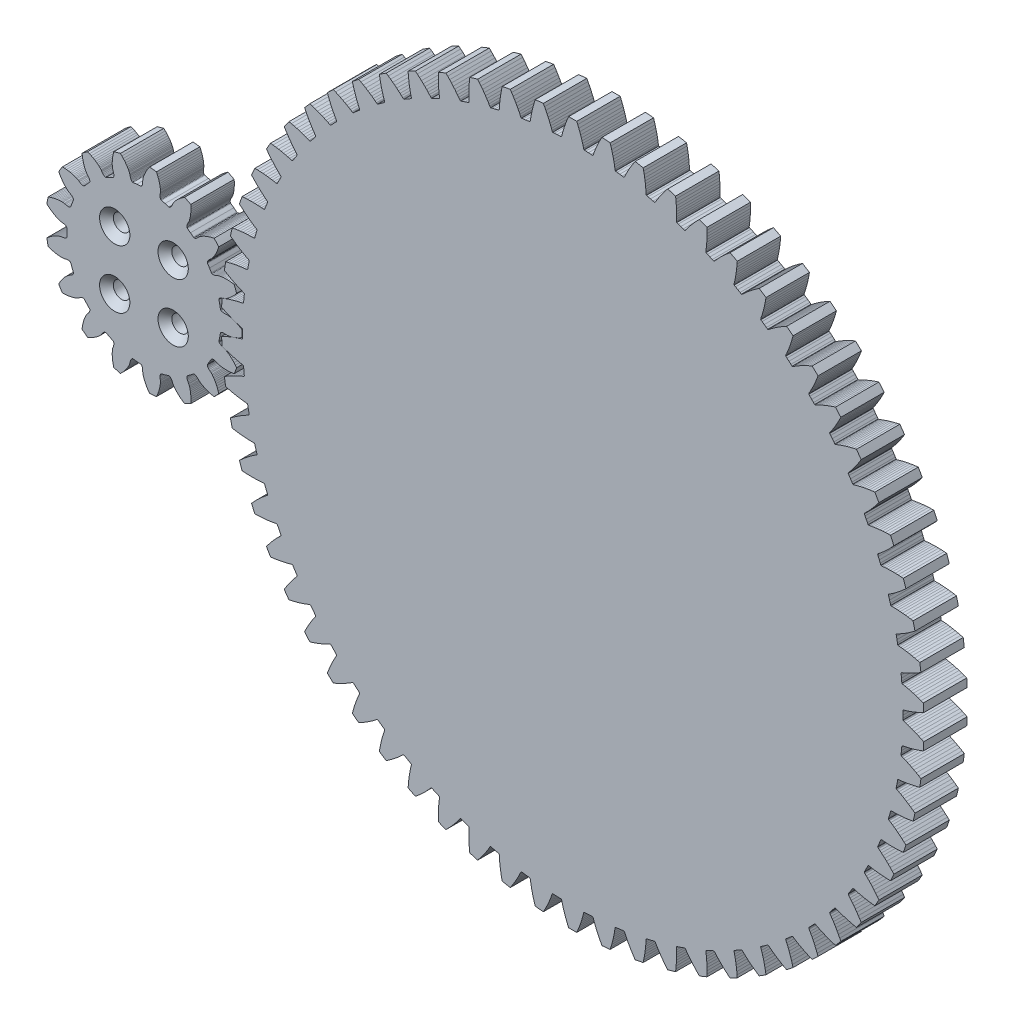
SolidWorks part; units mm, degrees
ref_plane "Front Plane" through (0, 0, 0) normal (0, 0, 1) x (1, 0, 0)
ref_plane "Top Plane" through (0, 0, 0) normal (0, 1, 0) x (1, 0, 0)
ref_plane "Right Plane" through (0, 0, 0) normal (1, 0, 0) x (0, 0, -1)
sketch "Model" plane through (0, 0, 0) normal (0, 0, 1) x (1, 0, 0)
  line L0 (12, -6.4817) -> (12.3555, -6.2755)
  line L1 (12.3555, -6.2755) -> (12.6973, -6.0868)
  line L2 (12.6973, -6.0868) -> (13.0251, -5.9146)
  line L3 (13.0251, -5.9146) -> (13.3372, -5.759)
  line L4 (13.3372, -5.759) -> (13.6339, -5.6187)
  line L5 (13.6339, -5.6187) -> (13.9158, -5.4926)
  line L6 (13.9158, -5.4926) -> (14.1799, -5.3809)
  line L7 (14.1799, -5.3809) -> (14.4044, -5.2913)
  line L8 (14.4044, -5.2913) -> (14.4813, -5.2564)
  line L9 (14.4813, -5.2564) -> (14.5358, -5.221)
  line L10 (14.5358, -5.221) -> (14.5678, -5.1861)
  line L11 (14.5678, -5.1861) -> (14.5755, -5.1691)
  line L12 (14.5755, -5.1691) -> (14.5775, -5.1526)
  line L13 (14.5775, -5.1526) -> (14.5542, -4.9322)
  line L14 (14.5542, -4.9322) -> (14.5171, -4.5579)
  line L15 (14.5171, -4.5579) -> (14.4827, -4.1834)
  line L16 (14.4827, -4.1834) -> (14.4639, -3.9626)
  line L17 (14.4639, -3.9626) -> (14.4588, -3.9468)
  line L18 (14.4588, -3.9468) -> (14.448, -3.9315)
  line L19 (14.448, -3.9315) -> (14.4099, -3.9033)
  line L20 (14.4099, -3.9033) -> (14.3498, -3.8789)
  line L21 (14.3498, -3.8789) -> (14.2676, -3.8592)
  line L22 (14.2676, -3.8592) -> (14.0303, -3.8137)
  line L23 (14.0303, -3.8137) -> (13.7497, -3.754)
  line L24 (13.7497, -3.754) -> (13.4492, -3.6835)
  line L25 (13.4492, -3.6835) -> (13.1312, -3.6019)
  line L26 (13.1312, -3.6019) -> (12.7954, -3.5081)
  line L27 (12.7954, -3.5081) -> (12.4408, -3.4011)
  line L28 (12.4408, -3.4011) -> (12.0695, -3.2805)
  line L29 (12.0695, -3.2805) -> (11.6814, -3.1453)
  line L30 (11.6814, -3.1453) -> (11.3394, -3.0186)
  line L31 (11.283, -1.8344) -> (11.6114, -1.6758)
  line L32 (11.6114, -1.6758) -> (11.9849, -1.5044)
  line L33 (11.9849, -1.5044) -> (12.3431, -1.349)
  line L34 (12.3431, -1.349) -> (12.6858, -1.2087)
  line L35 (12.6858, -1.2087) -> (13.0113, -1.0835)
  line L36 (13.0113, -1.0835) -> (13.32, -0.972)
  line L37 (13.32, -0.972) -> (13.6125, -0.8732)
  line L38 (13.6125, -0.8732) -> (13.8861, -0.7872)
  line L39 (13.8861, -0.7872) -> (14.1181, -0.7193)
  line L40 (14.1181, -0.7193) -> (14.1979, -0.6918)
  line L41 (14.1979, -0.6918) -> (14.2555, -0.6618)
  line L42 (14.2555, -0.6618) -> (14.2908, -0.6301)
  line L43 (14.2908, -0.6301) -> (14.3, -0.6139)
  line L44 (14.3, -0.6139) -> (14.3036, -0.5977)
  line L45 (14.3036, -0.5977) -> (14.3013, -0.3761)
  line L46 (14.3013, -0.3761) -> (14.3, 0)
  line L47 (14.3, 0) -> (14.3013, 0.3761)
  line L48 (14.3013, 0.3761) -> (14.3036, 0.5977)
  line L49 (14.3036, 0.5977) -> (14.3, 0.6139)
  line L50 (14.3, 0.6139) -> (14.2908, 0.6301)
  line L51 (14.2908, 0.6301) -> (14.2555, 0.6618)
  line L52 (14.2555, 0.6618) -> (14.1979, 0.6918)
  line L53 (14.1979, 0.6918) -> (14.1181, 0.7193)
  line L54 (14.1181, 0.7193) -> (13.8861, 0.7872)
  line L55 (13.8861, 0.7872) -> (13.6125, 0.8732)
  line L56 (13.6125, 0.8732) -> (13.32, 0.972)
  line L57 (13.32, 0.972) -> (13.0113, 1.0835)
  line L58 (13.0113, 1.0835) -> (12.6858, 1.2087)
  line L59 (12.6858, 1.2087) -> (12.3431, 1.349)
  line L60 (12.3431, 1.349) -> (11.9849, 1.5044)
  line L61 (11.9849, 1.5044) -> (11.6114, 1.6758)
  line L62 (11.6114, 1.6758) -> (11.283, 1.8344)
  line L63 (11.3394, 3.0186) -> (11.6814, 3.1453)
  line L64 (11.6814, 3.1453) -> (12.0695, 3.2805)
  line L65 (12.0695, 3.2805) -> (12.4408, 3.4011)
  line L66 (12.4408, 3.4011) -> (12.7954, 3.5081)
  line L67 (12.7954, 3.5081) -> (13.1312, 3.6019)
  line L68 (13.1312, 3.6019) -> (13.4492, 3.6835)
  line L69 (13.4492, 3.6835) -> (13.7497, 3.754)
  line L70 (13.7497, 3.754) -> (14.0303, 3.8137)
  line L71 (14.0303, 3.8137) -> (14.2676, 3.8592)
  line L72 (14.2676, 3.8592) -> (14.3498, 3.8789)
  line L73 (14.3498, 3.8789) -> (14.4099, 3.9033)
  line L74 (14.4099, 3.9033) -> (14.448, 3.9315)
  line L75 (14.448, 3.9315) -> (14.4588, 3.9468)
  line L76 (14.4588, 3.9468) -> (14.4639, 3.9626)
  line L77 (14.4639, 3.9626) -> (14.4827, 4.1834)
  line L78 (14.4827, 4.1834) -> (14.5171, 4.5579)
  line L79 (14.5171, 4.5579) -> (14.5542, 4.9322)
  line L80 (14.5542, 4.9322) -> (14.5775, 5.1526)
  line L81 (14.5775, 5.1526) -> (14.5755, 5.1691)
  line L82 (14.5755, 5.1691) -> (14.5678, 5.1861)
  line L83 (14.5678, 5.1861) -> (14.5358, 5.221)
  line L84 (14.5358, 5.221) -> (14.4813, 5.2564)
  line L85 (14.4813, 5.2564) -> (14.4044, 5.2913)
  line L86 (14.4044, 5.2913) -> (14.1799, 5.3809)
  line L87 (14.1799, 5.3809) -> (13.9158, 5.4926)
  line L88 (13.9158, 5.4926) -> (13.6339, 5.6187)
  line L89 (13.6339, 5.6187) -> (13.3372, 5.759)
  line L90 (13.3372, 5.759) -> (13.0251, 5.9146)
  line L91 (13.0251, 5.9146) -> (12.6973, 6.0868)
  line L92 (12.6973, 6.0868) -> (12.3555, 6.2755)
  line L93 (12.3555, 6.2755) -> (12, 6.4817)
  line L94 (12, 6.4817) -> (11.6882, 6.6708)
  line L95 (11.8569, 7.8443) -> (12.2094, 7.9379)
  line L96 (12.2094, 7.9379) -> (12.6086, 8.0356)
  line L97 (12.6086, 8.0356) -> (12.9897, 8.1204)
  line L98 (12.9897, 8.1204) -> (13.3528, 8.1932)
  line L99 (13.3528, 8.1932) -> (13.696, 8.2546)
  line L100 (13.696, 8.2546) -> (14.0203, 8.3056)
  line L101 (14.0203, 8.3056) -> (14.3262, 8.3473)
  line L102 (14.3262, 8.3473) -> (14.6111, 8.38)
  line L103 (14.6111, 8.38) -> (14.8517, 8.4027)
  line L104 (14.8517, 8.4027) -> (14.9354, 8.4146)
  line L105 (14.9354, 8.4146) -> (14.9976, 8.4332)
  line L106 (14.9976, 8.4332) -> (15.0382, 8.4576)
  line L107 (15.0382, 8.4576) -> (15.0503, 8.4718)
  line L108 (15.0503, 8.4718) -> (15.057, 8.487)
  line L109 (15.057, 8.487) -> (15.0966, 8.7051)
  line L110 (15.0966, 8.7051) -> (15.1665, 9.0746)
  line L111 (15.1665, 9.0746) -> (15.239, 9.4436)
  line L112 (15.239, 9.4436) -> (15.2832, 9.6608)
  line L113 (15.2832, 9.6608) -> (15.2827, 9.6774)
  line L114 (15.2827, 9.6774) -> (15.2767, 9.6951)
  line L115 (15.2767, 9.6951) -> (15.2481, 9.7329)
  line L116 (15.2481, 9.7329) -> (15.1972, 9.7733)
  line L117 (15.1972, 9.7733) -> (15.124, 9.8154)
  line L118 (15.124, 9.8154) -> (14.9091, 9.9259)
  line L119 (14.9091, 9.9259) -> (14.6567, 10.0622)
  line L120 (14.6567, 10.0622) -> (14.3882, 10.2145)
  line L121 (14.3882, 10.2145) -> (14.1061, 10.3824)
  line L122 (14.1061, 10.3824) -> (13.8103, 10.567)
  line L123 (13.8103, 10.567) -> (13.5003, 10.7695)
  line L124 (13.5003, 10.7695) -> (13.178, 10.9899)
  line L125 (13.178, 10.9899) -> (12.8437, 11.2289)
  line L126 (12.8437, 11.2289) -> (12.5512, 11.4468)
  line L127 (12.8307, 12.599) -> (13.1905, 12.6586)
  line L128 (13.1905, 12.6586) -> (13.5972, 12.7179)
  line L129 (13.5972, 12.7179) -> (13.9846, 12.7661)
  line L130 (13.9846, 12.7661) -> (14.353, 12.8041)
  line L131 (14.353, 12.8041) -> (14.7005, 12.8326)
  line L132 (14.7005, 12.8326) -> (15.0282, 12.8526)
  line L133 (15.0282, 12.8526) -> (15.3367, 12.8649)
  line L134 (15.3367, 12.8649) -> (15.6234, 12.8704)
  line L135 (15.6234, 12.8704) -> (15.8651, 12.8702)
  line L136 (15.8651, 12.8702) -> (15.9495, 12.874)
  line L137 (15.9495, 12.874) -> (16.0132, 12.8866)
  line L138 (16.0132, 12.8866) -> (16.0559, 12.9071)
  line L139 (16.0559, 12.9071) -> (16.0693, 12.92)
  line L140 (16.0693, 12.92) -> (16.0774, 12.9346)
  line L141 (16.0774, 12.9346) -> (16.1376, 13.1479)
  line L142 (16.1376, 13.1479) -> (16.2423, 13.5091)
  line L143 (16.2423, 13.5091) -> (16.3495, 13.8696)
  line L144 (16.3495, 13.8696) -> (16.4142, 14.0815)
  line L145 (16.4142, 14.0815) -> (16.4153, 14.0981)
  line L146 (16.4153, 14.0981) -> (16.411, 14.1163)
  line L147 (16.411, 14.1163) -> (16.3861, 14.1566)
  line L148 (16.3861, 14.1566) -> (16.3393, 14.2017)
  line L149 (16.3393, 14.2017) -> (16.2704, 14.2505)
  line L150 (16.2704, 14.2505) -> (16.067, 14.381)
  line L151 (16.067, 14.381) -> (15.8287, 14.5406)
  line L152 (15.8287, 14.5406) -> (15.5758, 14.7178)
  line L153 (15.5758, 14.7178) -> (15.311, 14.9117)
  line L154 (15.311, 14.9117) -> (15.0341, 15.1236)
  line L155 (15.0341, 15.1236) -> (14.7447, 15.3547)
  line L156 (14.7447, 15.3547) -> (14.4448, 15.6047)
  line L157 (14.4448, 15.6047) -> (14.1348, 15.8744)
  line L158 (14.1348, 15.8744) -> (13.8643, 16.1192)
  line L159 (14.2521, 17.2395) -> (14.616, 17.2647)
  line L160 (14.616, 17.2647) -> (15.0264, 17.285)
  line L161 (15.0264, 17.285) -> (15.4167, 17.2962)
  line L162 (15.4167, 17.2962) -> (15.787, 17.299)
  line L163 (15.787, 17.299) -> (16.1357, 17.2943)
  line L164 (16.1357, 17.2943) -> (16.4637, 17.2831)
  line L165 (16.4637, 17.2831) -> (16.772, 17.266)
  line L166 (16.772, 17.266) -> (17.0579, 17.2442)
  line L167 (17.0579, 17.2442) -> (17.2985, 17.221)
  line L168 (17.2985, 17.221) -> (17.3829, 17.2169)
  line L169 (17.3829, 17.2169) -> (17.4475, 17.2233)
  line L170 (17.4475, 17.2233) -> (17.492, 17.2397)
  line L171 (17.492, 17.2397) -> (17.5066, 17.2513)
  line L172 (17.5066, 17.2513) -> (17.516, 17.265)
  line L173 (17.516, 17.265) -> (17.5962, 17.4716)
  line L174 (17.5962, 17.4716) -> (17.7348, 17.8212)
  line L175 (17.7348, 17.8212) -> (17.8757, 18.1699)
  line L176 (17.8757, 18.1699) -> (17.9603, 18.3748)
  line L177 (17.9603, 18.3748) -> (17.9629, 18.3912)
  line L178 (17.9629, 18.3912) -> (17.9604, 18.4096)
  line L179 (17.9604, 18.4096) -> (17.9394, 18.4522)
  line L180 (17.9394, 18.4522) -> (17.8971, 18.5014)
  line L181 (17.8971, 18.5014) -> (17.8332, 18.5566)
  line L182 (17.8332, 18.5566) -> (17.6431, 18.7058)
  line L183 (17.6431, 18.7058) -> (17.4211, 18.8874)
  line L184 (17.4211, 18.8874) -> (17.1862, 19.0878)
  line L185 (17.1862, 19.0878) -> (16.941, 19.306)
  line L186 (16.941, 19.306) -> (16.6854, 19.5433)
  line L187 (16.6854, 19.5433) -> (16.4194, 19.8009)
  line L188 (16.4194, 19.8009) -> (16.1446, 20.0782)
  line L189 (16.1446, 20.0782) -> (15.8616, 20.3762)
  line L190 (15.8616, 20.3762) -> (15.6157, 20.6455)
  line L191 (16.1082, 21.7239) -> (16.4728, 21.7144)
  line L192 (16.4728, 21.7144) -> (16.8833, 21.6957)
  line L193 (16.8833, 21.6957) -> (17.2728, 21.6697)
  line L194 (17.2728, 21.6697) -> (17.6417, 21.6373)
  line L195 (17.6417, 21.6373) -> (17.9884, 21.5995)
  line L196 (17.9884, 21.5995) -> (18.3139, 21.5571)
  line L197 (18.3139, 21.5571) -> (18.6191, 21.5108)
  line L198 (18.6191, 21.5108) -> (18.9017, 21.4619)
  line L199 (18.9017, 21.4619) -> (19.139, 21.416)
  line L200 (19.139, 21.416) -> (19.2226, 21.4038)
  line L201 (19.2226, 21.4038) -> (19.2876, 21.4041)
  line L202 (19.2876, 21.4041) -> (19.3334, 21.4161)
  line L203 (19.3334, 21.4161) -> (19.349, 21.4263)
  line L204 (19.349, 21.4263) -> (19.3597, 21.439)
  line L205 (19.3597, 21.439) -> (19.4592, 21.6371)
  line L206 (19.4592, 21.6371) -> (19.6303, 21.972)
  line L207 (19.6303, 21.972) -> (19.8038, 22.3056)
  line L208 (19.8038, 22.3056) -> (19.9074, 22.5016)
  line L209 (19.9074, 22.5016) -> (19.9117, 22.5177)
  line L210 (19.9117, 22.5177) -> (19.9109, 22.5363)
  line L211 (19.9109, 22.5363) -> (19.8941, 22.5806)
  line L212 (19.8941, 22.5806) -> (19.8566, 22.6337)
  line L213 (19.8566, 22.6337) -> (19.7982, 22.6947)
  line L214 (19.7982, 22.6947) -> (19.6232, 22.8613)
  line L215 (19.6232, 22.8613) -> (19.4194, 23.0631)
  line L216 (19.4194, 23.0631) -> (19.2047, 23.285)
  line L217 (19.2047, 23.285) -> (18.9814, 23.5255)
  line L218 (18.9814, 23.5255) -> (18.7495, 23.786)
  line L219 (18.7495, 23.786) -> (18.5091, 24.0677)
  line L220 (18.5091, 24.0677) -> (18.262, 24.3699)
  line L221 (18.262, 24.3699) -> (18.0085, 24.6934)
  line L222 (18.0085, 24.6934) -> (17.7893, 24.9849)
  line L223 (18.3821, 26.0116) -> (18.7441, 25.9675)
  line L224 (18.7441, 25.9675) -> (19.151, 25.9098)
  line L225 (19.151, 25.9098) -> (19.5363, 25.8469)
  line L226 (19.5363, 25.8469) -> (19.9005, 25.7796)
  line L227 (19.9005, 25.7796) -> (20.242, 25.709)
  line L228 (20.242, 25.709) -> (20.562, 25.6359)
  line L229 (20.562, 25.6359) -> (20.8614, 25.5608)
  line L230 (20.8614, 25.5608) -> (21.1381, 25.4853)
  line L231 (21.1381, 25.4853) -> (21.3699, 25.417)
  line L232 (21.3699, 25.417) -> (21.452, 25.3969)
  line L233 (21.452, 25.3969) -> (21.5167, 25.391)
  line L234 (21.5167, 25.391) -> (21.5635, 25.3986)
  line L235 (21.5635, 25.3986) -> (21.58, 25.4072)
  line L236 (21.58, 25.4072) -> (21.5918, 25.4189)
  line L237 (21.5918, 25.4189) -> (21.7097, 25.6066)
  line L238 (21.7097, 25.6066) -> (21.9119, 25.9237)
  line L239 (21.9119, 25.9237) -> (22.1163, 26.2394)
  line L240 (22.1163, 26.2394) -> (22.2381, 26.4246)
  line L241 (22.2381, 26.4246) -> (22.2438, 26.4402)
  line L242 (22.2438, 26.4402) -> (22.2448, 26.4588)
  line L243 (22.2448, 26.4588) -> (22.2323, 26.5045)
  line L244 (22.2323, 26.5045) -> (22.2001, 26.5609)
  line L245 (22.2001, 26.5609) -> (22.1477, 26.6272)
  line L246 (22.1477, 26.6272) -> (21.9893, 26.8097)
  line L247 (21.9893, 26.8097) -> (21.8057, 27.03)
  line L248 (21.8057, 27.03) -> (21.613, 27.2713)
  line L249 (21.613, 27.2713) -> (21.4135, 27.5319)
  line L250 (21.4135, 27.5319) -> (21.2075, 27.8133)
  line L251 (21.2075, 27.8133) -> (20.9949, 28.1165)
  line L252 (20.9949, 28.1165) -> (20.7776, 28.4409)
  line L253 (20.7776, 28.4409) -> (20.5561, 28.787)
  line L254 (20.5561, 28.787) -> (20.3656, 29.098)
  line L255 (21.0533, 30.0638) -> (21.4095, 29.9854)
  line L256 (21.4095, 29.9854) -> (21.809, 29.8893)
  line L257 (21.809, 29.8893) -> (22.1866, 29.7901)
  line L258 (22.1866, 29.7901) -> (22.5427, 29.6884)
  line L259 (22.5427, 29.6884) -> (22.876, 29.5857)
  line L260 (22.876, 29.5857) -> (23.1876, 29.4825)
  line L261 (23.1876, 29.4825) -> (23.4786, 29.3793)
  line L262 (23.4786, 29.3793) -> (23.7468, 29.2778)
  line L263 (23.7468, 29.2778) -> (23.9711, 29.1878)
  line L264 (23.9711, 29.1878) -> (24.0509, 29.16)
  line L265 (24.0509, 29.16) -> (24.1147, 29.148)
  line L266 (24.1147, 29.148) -> (24.162, 29.1511)
  line L267 (24.162, 29.1511) -> (24.1792, 29.1581)
  line L268 (24.1792, 29.1581) -> (24.1921, 29.1687)
  line L269 (24.1921, 29.1687) -> (24.3273, 29.3443)
  line L270 (24.3273, 29.3443) -> (24.5588, 29.6407)
  line L271 (24.5588, 29.6407) -> (24.7923, 29.9355)
  line L272 (24.7923, 29.9355) -> (24.9311, 30.1083)
  line L273 (24.9311, 30.1083) -> (24.9383, 30.1233)
  line L274 (24.9383, 30.1233) -> (24.941, 30.1417)
  line L275 (24.941, 30.1417) -> (24.9329, 30.1884)
  line L276 (24.9329, 30.1884) -> (24.9062, 30.2476)
  line L277 (24.9062, 30.2476) -> (24.8604, 30.3186)
  line L278 (24.8604, 30.3186) -> (24.72, 30.5154)
  line L279 (24.72, 30.5154) -> (24.5582, 30.7521)
  line L280 (24.5582, 30.7521) -> (24.3893, 31.0106)
  line L281 (24.3893, 31.0106) -> (24.2155, 31.289)
  line L282 (24.2155, 31.289) -> (24.0371, 31.5887)
  line L283 (24.0371, 31.5887) -> (23.8544, 31.9108)
  line L284 (23.8544, 31.9108) -> (23.6689, 32.2543)
  line L285 (23.6689, 32.2543) -> (23.4813, 32.6199)
  line L286 (23.4813, 32.6199) -> (23.3212, 32.9477)
  line L287 (24.0976, 33.8436) -> (24.4447, 33.7318)
  line L288 (24.4447, 33.7318) -> (24.8333, 33.5981)
  line L289 (24.8333, 33.5981) -> (25.1998, 33.4634)
  line L290 (25.1998, 33.4634) -> (25.5446, 33.3284)
  line L291 (25.5446, 33.3284) -> (25.8666, 33.1945)
  line L292 (25.8666, 33.1945) -> (26.1669, 33.0621)
  line L293 (26.1669, 33.0621) -> (26.4468, 32.9317)
  line L294 (26.4468, 32.9317) -> (26.7042, 32.8052)
  line L295 (26.7042, 32.8052) -> (26.9189, 32.6942)
  line L296 (26.9189, 32.6942) -> (26.9957, 32.659)
  line L297 (26.9957, 32.659) -> (27.0581, 32.641)
  line L298 (27.0581, 32.641) -> (27.1054, 32.6396)
  line L299 (27.1054, 32.6396) -> (27.1233, 32.645)
  line L300 (27.1233, 32.645) -> (27.1371, 32.6542)
  line L301 (27.1371, 32.6542) -> (27.2884, 32.8162)
  line L302 (27.2884, 32.8162) -> (27.547, 33.0893)
  line L303 (27.547, 33.0893) -> (27.8074, 33.3606)
  line L304 (27.8074, 33.3606) -> (27.962, 33.5194)
  line L305 (27.962, 33.5194) -> (27.9706, 33.5336)
  line L306 (27.9706, 33.5336) -> (27.9751, 33.5517)
  line L307 (27.9751, 33.5517) -> (27.9715, 33.599)
  line L308 (27.9715, 33.599) -> (27.9505, 33.6604)
  line L309 (27.9505, 33.6604) -> (27.9117, 33.7354)
  line L310 (27.9117, 33.7354) -> (27.7906, 33.9446)
  line L311 (27.7906, 33.9446) -> (27.652, 34.1957)
  line L312 (27.652, 34.1957) -> (27.5084, 34.469)
  line L313 (27.5084, 34.469) -> (27.3619, 34.7627)
  line L314 (27.3619, 34.7627) -> (27.2128, 35.078)
  line L315 (27.2128, 35.078) -> (27.0616, 35.416)
  line L316 (27.0616, 35.416) -> (26.9096, 35.7756)
  line L317 (26.9096, 35.7756) -> (26.7576, 36.1574)
  line L318 (26.7576, 36.1574) -> (26.6293, 36.4989)
  line L319 (27.4874, 37.317) -> (27.8223, 37.1727)
  line L320 (27.8223, 37.1727) -> (28.1965, 37.0027)
  line L321 (28.1965, 37.0027) -> (28.5484, 36.8337)
  line L322 (28.5484, 36.8337) -> (28.8789, 36.6666)
  line L323 (28.8789, 36.6666) -> (29.1867, 36.5026)
  line L324 (29.1867, 36.5026) -> (29.4731, 36.3423)
  line L325 (29.4731, 36.3423) -> (29.7393, 36.1859)
  line L326 (29.7393, 36.1859) -> (29.9835, 36.0355)
  line L327 (29.9835, 36.0355) -> (30.1867, 35.9046)
  line L328 (30.1867, 35.9046) -> (30.2597, 35.8623)
  line L329 (30.2597, 35.8623) -> (30.3201, 35.8384)
  line L330 (30.3201, 35.8384) -> (30.3672, 35.8325)
  line L331 (30.3672, 35.8325) -> (30.3854, 35.8361)
  line L332 (30.3854, 35.8361) -> (30.4001, 35.844)
  line L333 (30.4001, 35.844) -> (30.5661, 35.9909)
  line L334 (30.5661, 35.9909) -> (30.8494, 36.2382)
  line L335 (30.8494, 36.2382) -> (31.1345, 36.4835)
  line L336 (31.1345, 36.4835) -> (31.3035, 36.6269)
  line L337 (31.3035, 36.6269) -> (31.3134, 36.6402)
  line L338 (31.3134, 36.6402) -> (31.3196, 36.6578)
  line L339 (31.3196, 36.6578) -> (31.3205, 36.7052)
  line L340 (31.3205, 36.7052) -> (31.3055, 36.7684)
  line L341 (31.3055, 36.7684) -> (31.2739, 36.8467)
  line L342 (31.2739, 36.8467) -> (31.1733, 37.0665)
  line L343 (31.1733, 37.0665) -> (31.0592, 37.3296)
  line L344 (31.0592, 37.3296) -> (30.9422, 37.6154)
  line L345 (30.9422, 37.6154) -> (30.8243, 37.9217)
  line L346 (30.8243, 37.9217) -> (30.7059, 38.2497)
  line L347 (30.7059, 38.2497) -> (30.5874, 38.6005)
  line L348 (30.5874, 38.6005) -> (30.4703, 38.973)
  line L349 (30.4703, 38.973) -> (30.3553, 39.3675)
  line L350 (30.3553, 39.3675) -> (30.2601, 39.7196)
  line L351 (31.192, 40.4524) -> (31.5117, 40.2769)
  line L352 (31.5117, 40.2769) -> (31.868, 40.0721)
  line L353 (31.868, 40.0721) -> (32.2023, 39.8705)
  line L354 (32.2023, 39.8705) -> (32.5153, 39.6727)
  line L355 (32.5153, 39.6727) -> (32.8062, 39.4802)
  line L356 (32.8062, 39.4802) -> (33.076, 39.2934)
  line L357 (33.076, 39.2934) -> (33.3262, 39.1124)
  line L358 (33.3262, 39.1124) -> (33.555, 38.9395)
  line L359 (33.555, 38.9395) -> (33.7448, 38.7899)
  line L360 (33.7448, 38.7899) -> (33.8135, 38.7407)
  line L361 (33.8135, 38.7407) -> (33.8714, 38.7112)
  line L362 (33.8714, 38.7112) -> (33.9176, 38.7009)
  line L363 (33.9176, 38.7009) -> (33.9362, 38.7028)
  line L364 (33.9362, 38.7028) -> (33.9515, 38.7093)
  line L365 (33.9515, 38.7093) -> (34.1307, 38.8397)
  line L366 (34.1307, 38.8397) -> (34.4363, 39.0589)
  line L367 (34.4363, 39.0589) -> (34.7434, 39.276)
  line L368 (34.7434, 39.276) -> (34.9252, 39.4027)
  line L369 (34.9252, 39.4027) -> (34.9364, 39.415)
  line L370 (34.9364, 39.415) -> (34.9442, 39.4319)
  line L371 (34.9442, 39.4319) -> (34.9496, 39.479)
  line L372 (34.9496, 39.479) -> (34.9406, 39.5434)
  line L373 (34.9406, 39.5434) -> (34.9167, 39.6244)
  line L374 (34.9167, 39.6244) -> (34.8374, 39.8527)
  line L375 (34.8374, 39.8527) -> (34.7488, 40.1254)
  line L376 (34.7488, 40.1254) -> (34.6596, 40.421)
  line L377 (34.6596, 40.421) -> (34.5713, 40.7371)
  line L378 (34.5713, 40.7371) -> (34.4846, 41.0749)
  line L379 (34.4846, 41.0749) -> (34.4, 41.4354)
  line L380 (34.4, 41.4354) -> (34.3188, 41.8173)
  line L381 (34.3188, 41.8173) -> (34.2418, 42.221)
  line L382 (34.2418, 42.221) -> (34.1805, 42.5806)
  line L383 (35.1779, 43.2215) -> (35.4795, 43.0164)
  line L384 (35.4795, 43.0164) -> (35.8146, 42.7787)
  line L385 (35.8146, 42.7787) -> (36.1283, 42.5462)
  line L386 (36.1283, 42.5462) -> (36.4211, 42.3195)
  line L387 (36.4211, 42.3195) -> (36.6923, 42.1003)
  line L388 (36.6923, 42.1003) -> (36.9432, 41.8886)
  line L389 (36.9432, 41.8886) -> (37.175, 41.6847)
  line L390 (37.175, 41.6847) -> (37.3863, 41.4908)
  line L391 (37.3863, 41.4908) -> (37.5611, 41.3238)
  line L392 (37.5611, 41.3238) -> (37.6248, 41.2684)
  line L393 (37.6248, 41.2684) -> (37.6796, 41.2335)
  line L394 (37.6796, 41.2335) -> (37.7247, 41.2189)
  line L395 (37.7247, 41.2189) -> (37.7433, 41.2189)
  line L396 (37.7433, 41.2189) -> (37.7592, 41.2239)
  line L397 (37.7592, 41.2239) -> (37.95, 41.3367)
  line L398 (37.95, 41.3367) -> (38.275, 41.5259)
  line L399 (38.275, 41.5259) -> (38.6013, 41.7128)
  line L400 (38.6013, 41.7128) -> (38.7944, 41.8216)
  line L401 (38.7944, 41.8216) -> (38.8067, 41.8329)
  line L402 (38.8067, 41.8329) -> (38.8161, 41.849)
  line L403 (38.8161, 41.849) -> (38.8259, 41.8953)
  line L404 (38.8259, 41.8953) -> (38.8231, 41.9602)
  line L405 (38.8231, 41.9602) -> (38.807, 42.0431)
  line L406 (38.807, 42.0431) -> (38.7498, 42.278)
  line L407 (38.7498, 42.278) -> (38.6875, 42.5579)
  line L408 (38.6875, 42.5579) -> (38.6268, 42.8606)
  line L409 (38.6268, 42.8606) -> (38.5689, 43.1837)
  line L410 (38.5689, 43.1837) -> (38.5147, 43.5282)
  line L411 (38.5147, 43.5282) -> (38.4648, 43.8951)
  line L412 (38.4648, 43.8951) -> (38.4203, 44.283)
  line L413 (38.4203, 44.283) -> (38.382, 44.6922)
  line L414 (38.382, 44.6922) -> (38.3551, 45.0559)
  line L415 (39.4089, 45.5992) -> (39.6896, 45.3663)
  line L416 (39.6896, 45.3663) -> (40.0007, 45.0978)
  line L417 (40.0007, 45.0978) -> (40.2909, 44.8365)
  line L418 (40.2909, 44.8365) -> (40.5608, 44.583)
  line L419 (40.5608, 44.583) -> (40.8099, 44.339)
  line L420 (40.8099, 44.339) -> (41.0396, 44.1045)
  line L421 (41.0396, 44.1045) -> (41.2509, 43.8795)
  line L422 (41.2509, 43.8795) -> (41.4429, 43.6663)
  line L423 (41.4429, 43.6663) -> (41.601, 43.4835)
  line L424 (41.601, 43.4835) -> (41.6591, 43.4223)
  line L425 (41.6591, 43.4223) -> (41.7104, 43.3824)
  line L426 (41.7104, 43.3824) -> (41.7538, 43.3635)
  line L427 (41.7538, 43.3635) -> (41.7724, 43.3618)
  line L428 (41.7724, 43.3618) -> (41.7887, 43.3653)
  line L429 (41.7887, 43.3653) -> (41.9893, 43.4594)
  line L430 (41.9893, 43.4594) -> (42.3309, 43.6169)
  line L431 (42.3309, 43.6169) -> (42.6735, 43.7719)
  line L432 (42.6735, 43.7719) -> (42.876, 43.8618)
  line L433 (42.876, 43.8618) -> (42.8893, 43.8719)
  line L434 (42.8893, 43.8719) -> (42.9002, 43.887)
  line L435 (42.9002, 43.887) -> (42.9144, 43.9322)
  line L436 (42.9144, 43.9322) -> (42.9178, 43.9971)
  line L437 (42.9178, 43.9971) -> (42.9096, 44.0812)
  line L438 (42.9096, 44.0812) -> (42.875, 44.3204)
  line L439 (42.875, 44.3204) -> (42.8396, 44.605)
  line L440 (42.8396, 44.605) -> (42.8079, 44.9121)
  line L441 (42.8079, 44.9121) -> (42.781, 45.2392)
  line L442 (42.781, 45.2392) -> (42.7598, 45.5873)
  line L443 (42.7598, 45.5873) -> (42.745, 45.9573)
  line L444 (42.745, 45.9573) -> (42.7375, 46.3477)
  line L445 (42.7375, 46.3477) -> (42.7383, 46.7586)
  line L446 (42.7383, 46.7586) -> (42.7462, 47.1233)
  line L447 (43.8468, 47.5639) -> (44.1041, 47.3054)
  line L448 (44.1041, 47.3054) -> (44.3883, 47.0085)
  line L449 (44.3883, 47.0085) -> (44.6523, 46.7209)
  line L450 (44.6523, 46.7209) -> (44.8969, 46.4429)
  line L451 (44.8969, 46.4429) -> (45.1217, 46.1763)
  line L452 (45.1217, 46.1763) -> (45.328, 45.921)
  line L453 (45.328, 45.921) -> (45.517, 45.6769)
  line L454 (45.517, 45.6769) -> (45.6878, 45.4465)
  line L455 (45.6878, 45.4465) -> (45.8278, 45.2495)
  line L456 (45.8278, 45.2495) -> (45.8799, 45.183)
  line L457 (45.8799, 45.183) -> (45.9271, 45.1384)
  line L458 (45.9271, 45.1384) -> (45.9686, 45.1154)
  line L459 (45.9686, 45.1154) -> (45.9869, 45.112)
  line L460 (45.9869, 45.112) -> (46.0035, 45.1139)
  line L461 (46.0035, 45.1139) -> (46.2121, 45.1885)
  line L462 (46.2121, 45.1885) -> (46.5671, 45.3128)
  line L463 (46.5671, 45.3128) -> (46.9229, 45.4346)
  line L464 (46.9229, 45.4346) -> (47.1331, 45.5048)
  line L465 (47.1331, 45.5048) -> (47.1473, 45.5136)
  line L466 (47.1473, 45.5136) -> (47.1595, 45.5276)
  line L467 (47.1595, 45.5276) -> (47.178, 45.5713)
  line L468 (47.178, 45.5713) -> (47.1875, 45.6355)
  line L469 (47.1875, 45.6355) -> (47.1873, 45.72)
  line L470 (47.1873, 45.72) -> (47.1756, 45.9614)
  line L471 (47.1756, 45.9614) -> (47.1674, 46.2481)
  line L472 (47.1674, 46.2481) -> (47.1651, 46.5568)
  line L473 (47.1651, 46.5568) -> (47.1695, 46.885)
  line L474 (47.1695, 46.885) -> (47.1814, 47.2335)
  line L475 (47.1814, 47.2335) -> (47.2018, 47.6033)
  line L476 (47.2018, 47.6033) -> (47.2315, 47.9926)
  line L477 (47.2315, 47.9926) -> (47.2714, 48.4016)
  line L478 (47.2714, 48.4016) -> (47.3138, 48.7638)
  line L479 (48.4514, 49.0978) -> (48.683, 48.8161)
  line L480 (48.683, 48.8161) -> (48.9376, 48.4935)
  line L481 (48.9376, 48.4935) -> (49.1731, 48.1821)
  line L482 (49.1731, 48.1821) -> (49.3901, 47.8821)
  line L483 (49.3901, 47.8821) -> (49.5886, 47.5953)
  line L484 (49.5886, 47.5953) -> (49.7697, 47.3216)
  line L485 (49.7697, 47.3216) -> (49.9347, 47.0606)
  line L486 (49.9347, 47.0606) -> (50.0828, 46.815)
  line L487 (50.0828, 46.815) -> (50.2034, 46.6056)
  line L488 (50.2034, 46.6056) -> (50.2489, 46.5344)
  line L489 (50.2489, 46.5344) -> (50.2917, 46.4856)
  line L490 (50.2917, 46.4856) -> (50.3308, 46.4588)
  line L491 (50.3308, 46.4588) -> (50.3487, 46.4536)
  line L492 (50.3487, 46.4536) -> (50.3654, 46.4539)
  line L493 (50.3654, 46.4539) -> (50.5802, 46.5084)
  line L494 (50.5802, 46.5084) -> (50.9454, 46.5984)
  line L495 (50.9454, 46.5984) -> (51.3111, 46.6858)
  line L496 (51.3111, 46.6858) -> (51.5271, 46.7358)
  line L497 (51.5271, 46.7358) -> (51.542, 46.7431)
  line L498 (51.542, 46.7431) -> (51.5555, 46.7559)
  line L499 (51.5555, 46.7559) -> (51.578, 46.7976)
  line L500 (51.578, 46.7976) -> (51.5936, 46.8607)
  line L501 (51.5936, 46.8607) -> (51.6015, 46.9448)
  line L502 (51.6015, 46.9448) -> (51.6128, 47.1862)
  line L503 (51.6128, 47.1862) -> (51.6319, 47.4723)
  line L504 (51.6319, 47.4723) -> (51.6589, 47.7799)
  line L505 (51.6589, 47.7799) -> (51.6945, 48.1062)
  line L506 (51.6945, 48.1062) -> (51.7395, 48.452)
  line L507 (51.7395, 48.452) -> (51.7949, 48.8181)
  line L508 (51.7949, 48.8181) -> (51.8615, 49.2029)
  line L509 (51.8615, 49.2029) -> (51.94, 49.6062)
  line L510 (51.94, 49.6062) -> (52.0168, 49.9628)
  line L511 (53.1809, 50.1872) -> (53.3847, 49.8846)
  line L512 (53.3847, 49.8846) -> (53.6075, 49.5394)
  line L513 (53.6075, 49.5394) -> (53.8123, 49.207)
  line L514 (53.8123, 49.207) -> (53.9998, 48.8877)
  line L515 (53.9998, 48.8877) -> (54.1702, 48.5833)
  line L516 (54.1702, 48.5833) -> (54.3244, 48.2936)
  line L517 (54.3244, 48.2936) -> (54.4638, 48.0181)
  line L518 (54.4638, 48.0181) -> (54.5879, 47.7596)
  line L519 (54.5879, 47.7596) -> (54.6881, 47.5397)
  line L520 (54.6881, 47.5397) -> (54.7267, 47.4645)
  line L521 (54.7267, 47.4645) -> (54.7646, 47.4118)
  line L522 (54.7646, 47.4118) -> (54.801, 47.3814)
  line L523 (54.801, 47.3814) -> (54.8183, 47.3746)
  line L524 (54.8183, 47.3746) -> (54.8349, 47.3733)
  line L525 (54.8349, 47.3733) -> (55.0539, 47.4071)
  line L526 (55.0539, 47.4071) -> (55.426, 47.4619)
  line L527 (55.426, 47.4619) -> (55.7984, 47.5142)
  line L528 (55.7984, 47.5142) -> (56.0181, 47.5434)
  line L529 (56.0181, 47.5434) -> (56.0337, 47.5493)
  line L530 (56.0337, 47.5493) -> (56.0484, 47.5607)
  line L531 (56.0484, 47.5607) -> (56.0748, 47.6001)
  line L532 (56.0748, 47.6001) -> (56.0963, 47.6614)
  line L533 (56.0963, 47.6614) -> (56.1121, 47.7444)
  line L534 (56.1121, 47.7444) -> (56.1463, 47.9837)
  line L535 (56.1463, 47.9837) -> (56.1925, 48.2667)
  line L536 (56.1925, 48.2667) -> (56.2486, 48.5703)
  line L537 (56.2486, 48.5703) -> (56.315, 48.8917)
  line L538 (56.315, 48.8917) -> (56.3927, 49.2317)
  line L539 (56.3927, 49.2317) -> (56.4827, 49.5909)
  line L540 (56.4827, 49.5909) -> (56.5856, 49.9675)
  line L541 (56.5856, 49.9675) -> (56.7021, 50.3616)
  line L542 (56.7021, 50.3616) -> (56.8124, 50.7093)
  line L543 (57.9926, 50.822) -> (58.1666, 50.5015)
  line L544 (58.1666, 50.5015) -> (58.3556, 50.1366)
  line L545 (58.3556, 50.1366) -> (58.5279, 49.7862)
  line L546 (58.5279, 49.7862) -> (58.6843, 49.4505)
  line L547 (58.6843, 49.4505) -> (58.8249, 49.1314)
  line L548 (58.8249, 49.1314) -> (58.9509, 48.8283)
  line L549 (58.9509, 48.8283) -> (59.0635, 48.5408)
  line L550 (59.0635, 48.5408) -> (59.1625, 48.2717)
  line L551 (59.1625, 48.2717) -> (59.2413, 48.0432)
  line L552 (59.2413, 48.0432) -> (59.2725, 47.9647)
  line L553 (59.2725, 47.9647) -> (59.3053, 47.9086)
  line L554 (59.3053, 47.9086) -> (59.3386, 47.8749)
  line L555 (59.3386, 47.8749) -> (59.3552, 47.8665)
  line L556 (59.3552, 47.8665) -> (59.3716, 47.8636)
  line L557 (59.3716, 47.8636) -> (59.5929, 47.8765)
  line L558 (59.5929, 47.8765) -> (59.9684, 47.8957)
  line L559 (59.9684, 47.8957) -> (60.3442, 47.9123)
  line L560 (60.3442, 47.9123) -> (60.5656, 47.9205)
  line L561 (60.5656, 47.9205) -> (60.5817, 47.9249)
  line L562 (60.5817, 47.9249) -> (60.5974, 47.9349)
  line L563 (60.5974, 47.9349) -> (60.6274, 47.9716)
  line L564 (60.6274, 47.9716) -> (60.6547, 48.0306)
  line L565 (60.6547, 48.0306) -> (60.6783, 48.1116)
  line L566 (60.6783, 48.1116) -> (60.7351, 48.3466)
  line L567 (60.7351, 48.3466) -> (60.808, 48.6239)
  line L568 (60.808, 48.6239) -> (60.8927, 48.9208)
  line L569 (60.8927, 48.9208) -> (60.9894, 49.2345)
  line L570 (60.9894, 49.2345) -> (61.099, 49.5656)
  line L571 (61.099, 49.5656) -> (61.2228, 49.9146)
  line L572 (61.2228, 49.9146) -> (61.3609, 50.2797)
  line L573 (61.3609, 50.2797) -> (61.5144, 50.6609)
  line L574 (61.5144, 50.6609) -> (61.6572, 50.9966)
  line L575 (62.8428, 50.9966) -> (62.9856, 50.6609)
  line L576 (62.9856, 50.6609) -> (63.1391, 50.2797)
  line L577 (63.1391, 50.2797) -> (63.2772, 49.9146)
  line L578 (63.2772, 49.9146) -> (63.401, 49.5656)
  line L579 (63.401, 49.5656) -> (63.5106, 49.2345)
  line L580 (63.5106, 49.2345) -> (63.6073, 48.9208)
  line L581 (63.6073, 48.9208) -> (63.692, 48.6239)
  line L582 (63.692, 48.6239) -> (63.7649, 48.3466)
  line L583 (63.7649, 48.3466) -> (63.8217, 48.1116)
  line L584 (63.8217, 48.1116) -> (63.8453, 48.0306)
  line L585 (63.8453, 48.0306) -> (63.8726, 47.9716)
  line L586 (63.8726, 47.9716) -> (63.9026, 47.9349)
  line L587 (63.9026, 47.9349) -> (63.9183, 47.9249)
  line L588 (63.9183, 47.9249) -> (63.9344, 47.9205)
  line L589 (63.9344, 47.9205) -> (64.1558, 47.9123)
  line L590 (64.1558, 47.9123) -> (64.5316, 47.8957)
  line L591 (64.5316, 47.8957) -> (64.9071, 47.8765)
  line L592 (64.9071, 47.8765) -> (65.1284, 47.8636)
  line L593 (65.1284, 47.8636) -> (65.1448, 47.8665)
  line L594 (65.1448, 47.8665) -> (65.1614, 47.8749)
  line L595 (65.1614, 47.8749) -> (65.1947, 47.9086)
  line L596 (65.1947, 47.9086) -> (65.2275, 47.9647)
  line L597 (65.2275, 47.9647) -> (65.2587, 48.0432)
  line L598 (65.2587, 48.0432) -> (65.3375, 48.2717)
  line L599 (65.3375, 48.2717) -> (65.4365, 48.5408)
  line L600 (65.4365, 48.5408) -> (65.5491, 48.8283)
  line L601 (65.5491, 48.8283) -> (65.6751, 49.1314)
  line L602 (65.6751, 49.1314) -> (65.8157, 49.4505)
  line L603 (65.8157, 49.4505) -> (65.9721, 49.7862)
  line L604 (65.9721, 49.7862) -> (66.1444, 50.1366)
  line L605 (66.1444, 50.1366) -> (66.3334, 50.5015)
  line L606 (66.3334, 50.5015) -> (66.5074, 50.822)
  line L607 (67.6876, 50.7093) -> (67.7979, 50.3616)
  line L608 (67.7979, 50.3616) -> (67.9144, 49.9675)
  line L609 (67.9144, 49.9675) -> (68.0173, 49.5909)
  line L610 (68.0173, 49.5909) -> (68.1073, 49.2317)
  line L611 (68.1073, 49.2317) -> (68.185, 48.8917)
  line L612 (68.185, 48.8917) -> (68.2514, 48.5703)
  line L613 (68.2514, 48.5703) -> (68.3075, 48.2667)
  line L614 (68.3075, 48.2667) -> (68.3537, 47.9837)
  line L615 (68.3537, 47.9837) -> (68.3879, 47.7444)
  line L616 (68.3879, 47.7444) -> (68.4037, 47.6614)
  line L617 (68.4037, 47.6614) -> (68.4252, 47.6001)
  line L618 (68.4252, 47.6001) -> (68.4516, 47.5607)
  line L619 (68.4516, 47.5607) -> (68.4663, 47.5493)
  line L620 (68.4663, 47.5493) -> (68.4819, 47.5434)
  line L621 (68.4819, 47.5434) -> (68.7016, 47.5142)
  line L622 (68.7016, 47.5142) -> (69.074, 47.4619)
  line L623 (69.074, 47.4619) -> (69.4461, 47.4071)
  line L624 (69.4461, 47.4071) -> (69.6651, 47.3733)
  line L625 (69.6651, 47.3733) -> (69.6817, 47.3746)
  line L626 (69.6817, 47.3746) -> (69.699, 47.3814)
  line L627 (69.699, 47.3814) -> (69.7354, 47.4118)
  line L628 (69.7354, 47.4118) -> (69.7733, 47.4645)
  line L629 (69.7733, 47.4645) -> (69.8119, 47.5397)
  line L630 (69.8119, 47.5397) -> (69.9121, 47.7596)
  line L631 (69.9121, 47.7596) -> (70.0362, 48.0181)
  line L632 (70.0362, 48.0181) -> (70.1756, 48.2936)
  line L633 (70.1756, 48.2936) -> (70.3298, 48.5833)
  line L634 (70.3298, 48.5833) -> (70.5002, 48.8877)
  line L635 (70.5002, 48.8877) -> (70.6877, 49.207)
  line L636 (70.6877, 49.207) -> (70.8925, 49.5394)
  line L637 (70.8925, 49.5394) -> (71.1153, 49.8846)
  line L638 (71.1153, 49.8846) -> (71.3191, 50.1872)
  line L639 (72.4832, 49.9628) -> (72.56, 49.6062)
  line L640 (72.56, 49.6062) -> (72.6385, 49.2029)
  line L641 (72.6385, 49.2029) -> (72.7051, 48.8181)
  line L642 (72.7051, 48.8181) -> (72.7605, 48.452)
  line L643 (72.7605, 48.452) -> (72.8055, 48.1062)
  line L644 (72.8055, 48.1062) -> (72.8411, 47.7799)
  line L645 (72.8411, 47.7799) -> (72.8681, 47.4723)
  line L646 (72.8681, 47.4723) -> (72.8872, 47.1862)
  line L647 (72.8872, 47.1862) -> (72.8985, 46.9448)
  line L648 (72.8985, 46.9448) -> (72.9064, 46.8607)
  line L649 (72.9064, 46.8607) -> (72.922, 46.7976)
  line L650 (72.922, 46.7976) -> (72.9445, 46.7559)
  line L651 (72.9445, 46.7559) -> (72.958, 46.7431)
  line L652 (72.958, 46.7431) -> (72.9729, 46.7358)
  line L653 (72.9729, 46.7358) -> (73.1889, 46.6858)
  line L654 (73.1889, 46.6858) -> (73.5546, 46.5984)
  line L655 (73.5546, 46.5984) -> (73.9198, 46.5084)
  line L656 (73.9198, 46.5084) -> (74.1346, 46.4539)
  line L657 (74.1346, 46.4539) -> (74.1513, 46.4536)
  line L658 (74.1513, 46.4536) -> (74.1692, 46.4588)
  line L659 (74.1692, 46.4588) -> (74.2083, 46.4856)
  line L660 (74.2083, 46.4856) -> (74.2511, 46.5344)
  line L661 (74.2511, 46.5344) -> (74.2966, 46.6056)
  line L662 (74.2966, 46.6056) -> (74.4172, 46.815)
  line L663 (74.4172, 46.815) -> (74.5653, 47.0606)
  line L664 (74.5653, 47.0606) -> (74.7303, 47.3216)
  line L665 (74.7303, 47.3216) -> (74.9114, 47.5953)
  line L666 (74.9114, 47.5953) -> (75.1099, 47.8821)
  line L667 (75.1099, 47.8821) -> (75.3269, 48.1821)
  line L668 (75.3269, 48.1821) -> (75.5624, 48.4935)
  line L669 (75.5624, 48.4935) -> (75.817, 48.8161)
  line L670 (75.817, 48.8161) -> (76.0486, 49.0978)
  line L671 (77.1862, 48.7638) -> (77.2286, 48.4016)
  line L672 (77.2286, 48.4016) -> (77.2685, 47.9926)
  line L673 (77.2685, 47.9926) -> (77.2982, 47.6033)
  line L674 (77.2982, 47.6033) -> (77.3186, 47.2335)
  line L675 (77.3186, 47.2335) -> (77.3305, 46.885)
  line L676 (77.3305, 46.885) -> (77.3349, 46.5568)
  line L677 (77.3349, 46.5568) -> (77.3326, 46.2481)
  line L678 (77.3326, 46.2481) -> (77.3244, 45.9614)
  line L679 (77.3244, 45.9614) -> (77.3127, 45.72)
  line L680 (77.3127, 45.72) -> (77.3125, 45.6355)
  line L681 (77.3125, 45.6355) -> (77.322, 45.5713)
  line L682 (77.322, 45.5713) -> (77.3405, 45.5276)
  line L683 (77.3405, 45.5276) -> (77.3527, 45.5136)
  line L684 (77.3527, 45.5136) -> (77.3669, 45.5048)
  line L685 (77.3669, 45.5048) -> (77.5771, 45.4346)
  line L686 (77.5771, 45.4346) -> (77.9329, 45.3128)
  line L687 (77.9329, 45.3128) -> (78.2879, 45.1885)
  line L688 (78.2879, 45.1885) -> (78.4965, 45.1139)
  line L689 (78.4965, 45.1139) -> (78.5131, 45.112)
  line L690 (78.5131, 45.112) -> (78.5314, 45.1154)
  line L691 (78.5314, 45.1154) -> (78.5729, 45.1384)
  line L692 (78.5729, 45.1384) -> (78.6201, 45.183)
  line L693 (78.6201, 45.183) -> (78.6722, 45.2495)
  line L694 (78.6722, 45.2495) -> (78.8122, 45.4465)
  line L695 (78.8122, 45.4465) -> (78.983, 45.6769)
  line L696 (78.983, 45.6769) -> (79.172, 45.921)
  line L697 (79.172, 45.921) -> (79.3783, 46.1763)
  line L698 (79.3783, 46.1763) -> (79.6031, 46.4429)
  line L699 (79.6031, 46.4429) -> (79.8477, 46.7209)
  line L700 (79.8477, 46.7209) -> (80.1117, 47.0085)
  line L701 (80.1117, 47.0085) -> (80.3959, 47.3054)
  line L702 (80.3959, 47.3054) -> (80.6532, 47.5639)
  line L703 (81.7538, 47.1233) -> (81.7617, 46.7586)
  line L704 (81.7617, 46.7586) -> (81.7625, 46.3477)
  line L705 (81.7625, 46.3477) -> (81.755, 45.9573)
  line L706 (81.755, 45.9573) -> (81.7402, 45.5873)
  line L707 (81.7402, 45.5873) -> (81.719, 45.2392)
  line L708 (81.719, 45.2392) -> (81.6921, 44.9121)
  line L709 (81.6921, 44.9121) -> (81.6604, 44.605)
  line L710 (81.6604, 44.605) -> (81.625, 44.3204)
  line L711 (81.625, 44.3204) -> (81.5904, 44.0812)
  line L712 (81.5904, 44.0812) -> (81.5822, 43.9971)
  line L713 (81.5822, 43.9971) -> (81.5856, 43.9322)
  line L714 (81.5856, 43.9322) -> (81.5998, 43.887)
  line L715 (81.5998, 43.887) -> (81.6107, 43.8719)
  line L716 (81.6107, 43.8719) -> (81.624, 43.8618)
  line L717 (81.624, 43.8618) -> (81.8265, 43.7719)
  line L718 (81.8265, 43.7719) -> (82.1691, 43.6169)
  line L719 (82.1691, 43.6169) -> (82.5107, 43.4594)
  line L720 (82.5107, 43.4594) -> (82.7113, 43.3653)
  line L721 (82.7113, 43.3653) -> (82.7276, 43.3618)
  line L722 (82.7276, 43.3618) -> (82.7462, 43.3635)
  line L723 (82.7462, 43.3635) -> (82.7896, 43.3824)
  line L724 (82.7896, 43.3824) -> (82.8409, 43.4223)
  line L725 (82.8409, 43.4223) -> (82.899, 43.4835)
  line L726 (82.899, 43.4835) -> (83.0571, 43.6663)
  line L727 (83.0571, 43.6663) -> (83.2491, 43.8795)
  line L728 (83.2491, 43.8795) -> (83.4604, 44.1045)
  line L729 (83.4604, 44.1045) -> (83.6901, 44.339)
  line L730 (83.6901, 44.339) -> (83.9392, 44.583)
  line L731 (83.9392, 44.583) -> (84.2091, 44.8365)
  line L732 (84.2091, 44.8365) -> (84.4993, 45.0978)
  line L733 (84.4993, 45.0978) -> (84.8104, 45.3663)
  line L734 (84.8104, 45.3663) -> (85.0911, 45.5992)
  line L735 (86.1449, 45.0559) -> (86.118, 44.6922)
  line L736 (86.118, 44.6922) -> (86.0797, 44.283)
  line L737 (86.0797, 44.283) -> (86.0352, 43.8951)
  line L738 (86.0352, 43.8951) -> (85.9853, 43.5282)
  line L739 (85.9853, 43.5282) -> (85.9311, 43.1837)
  line L740 (85.9311, 43.1837) -> (85.8732, 42.8606)
  line L741 (85.8732, 42.8606) -> (85.8125, 42.5579)
  line L742 (85.8125, 42.5579) -> (85.7502, 42.278)
  line L743 (85.7502, 42.278) -> (85.693, 42.0431)
  line L744 (85.693, 42.0431) -> (85.6769, 41.9602)
  line L745 (85.6769, 41.9602) -> (85.6741, 41.8953)
  line L746 (85.6741, 41.8953) -> (85.6839, 41.849)
  line L747 (85.6839, 41.849) -> (85.6933, 41.8329)
  line L748 (85.6933, 41.8329) -> (85.7056, 41.8216)
  line L749 (85.7056, 41.8216) -> (85.8987, 41.7128)
  line L750 (85.8987, 41.7128) -> (86.225, 41.5259)
  line L751 (86.225, 41.5259) -> (86.55, 41.3367)
  line L752 (86.55, 41.3367) -> (86.7408, 41.2239)
  line L753 (86.7408, 41.2239) -> (86.7567, 41.2189)
  line L754 (86.7567, 41.2189) -> (86.7753, 41.2189)
  line L755 (86.7753, 41.2189) -> (86.8204, 41.2335)
  line L756 (86.8204, 41.2335) -> (86.8752, 41.2684)
  line L757 (86.8752, 41.2684) -> (86.9389, 41.3238)
  line L758 (86.9389, 41.3238) -> (87.1137, 41.4908)
  line L759 (87.1137, 41.4908) -> (87.325, 41.6847)
  line L760 (87.325, 41.6847) -> (87.5568, 41.8886)
  line L761 (87.5568, 41.8886) -> (87.8077, 42.1003)
  line L762 (87.8077, 42.1003) -> (88.0789, 42.3195)
  line L763 (88.0789, 42.3195) -> (88.3717, 42.5462)
  line L764 (88.3717, 42.5462) -> (88.6854, 42.7787)
  line L765 (88.6854, 42.7787) -> (89.0205, 43.0164)
  line L766 (89.0205, 43.0164) -> (89.3221, 43.2215)
  line L767 (90.3195, 42.5806) -> (90.2582, 42.221)
  line L768 (90.2582, 42.221) -> (90.1812, 41.8173)
  line L769 (90.1812, 41.8173) -> (90.1, 41.4354)
  line L770 (90.1, 41.4354) -> (90.0154, 41.0749)
  line L771 (90.0154, 41.0749) -> (89.9287, 40.7371)
  line L772 (89.9287, 40.7371) -> (89.8404, 40.421)
  line L773 (89.8404, 40.421) -> (89.7512, 40.1254)
  line L774 (89.7512, 40.1254) -> (89.6626, 39.8527)
  line L775 (89.6626, 39.8527) -> (89.5833, 39.6244)
  line L776 (89.5833, 39.6244) -> (89.5594, 39.5434)
  line L777 (89.5594, 39.5434) -> (89.5504, 39.479)
  line L778 (89.5504, 39.479) -> (89.5558, 39.4319)
  line L779 (89.5558, 39.4319) -> (89.5636, 39.415)
  line L780 (89.5636, 39.415) -> (89.5748, 39.4027)
  line L781 (89.5748, 39.4027) -> (89.7566, 39.276)
  line L782 (89.7566, 39.276) -> (90.0637, 39.0589)
  line L783 (90.0637, 39.0589) -> (90.3693, 38.8397)
  line L784 (90.3693, 38.8397) -> (90.5485, 38.7093)
  line L785 (90.5485, 38.7093) -> (90.5638, 38.7028)
  line L786 (90.5638, 38.7028) -> (90.5824, 38.7009)
  line L787 (90.5824, 38.7009) -> (90.6286, 38.7112)
  line L788 (90.6286, 38.7112) -> (90.6865, 38.7407)
  line L789 (90.6865, 38.7407) -> (90.7552, 38.7899)
  line L790 (90.7552, 38.7899) -> (90.945, 38.9395)
  line L791 (90.945, 38.9395) -> (91.1738, 39.1124)
  line L792 (91.1738, 39.1124) -> (91.424, 39.2934)
  line L793 (91.424, 39.2934) -> (91.6938, 39.4802)
  line L794 (91.6938, 39.4802) -> (91.9847, 39.6727)
  line L795 (91.9847, 39.6727) -> (92.2977, 39.8705)
  line L796 (92.2977, 39.8705) -> (92.632, 40.0721)
  line L797 (92.632, 40.0721) -> (92.9883, 40.2769)
  line L798 (92.9883, 40.2769) -> (93.308, 40.4524)
  line L799 (94.2399, 39.7196) -> (94.1447, 39.3675)
  line L800 (94.1447, 39.3675) -> (94.0297, 38.973)
  line L801 (94.0297, 38.973) -> (93.9126, 38.6005)
  line L802 (93.9126, 38.6005) -> (93.7941, 38.2497)
  line L803 (93.7941, 38.2497) -> (93.6757, 37.9217)
  line L804 (93.6757, 37.9217) -> (93.5578, 37.6154)
  line L805 (93.5578, 37.6154) -> (93.4408, 37.3296)
  line L806 (93.4408, 37.3296) -> (93.3267, 37.0665)
  line L807 (93.3267, 37.0665) -> (93.2261, 36.8467)
  line L808 (93.2261, 36.8467) -> (93.1945, 36.7684)
  line L809 (93.1945, 36.7684) -> (93.1795, 36.7052)
  line L810 (93.1795, 36.7052) -> (93.1804, 36.6578)
  line L811 (93.1804, 36.6578) -> (93.1866, 36.6402)
  line L812 (93.1866, 36.6402) -> (93.1965, 36.6269)
  line L813 (93.1965, 36.6269) -> (93.3655, 36.4835)
  line L814 (93.3655, 36.4835) -> (93.6506, 36.2382)
  line L815 (93.6506, 36.2382) -> (93.9339, 35.9909)
  line L816 (93.9339, 35.9909) -> (94.0999, 35.844)
  line L817 (94.0999, 35.844) -> (94.1146, 35.8361)
  line L818 (94.1146, 35.8361) -> (94.1328, 35.8325)
  line L819 (94.1328, 35.8325) -> (94.1799, 35.8384)
  line L820 (94.1799, 35.8384) -> (94.2403, 35.8623)
  line L821 (94.2403, 35.8623) -> (94.3133, 35.9046)
  line L822 (94.3133, 35.9046) -> (94.5165, 36.0355)
  line L823 (94.5165, 36.0355) -> (94.7607, 36.1859)
  line L824 (94.7607, 36.1859) -> (95.0269, 36.3423)
  line L825 (95.0269, 36.3423) -> (95.3133, 36.5026)
  line L826 (95.3133, 36.5026) -> (95.6211, 36.6666)
  line L827 (95.6211, 36.6666) -> (95.9516, 36.8337)
  line L828 (95.9516, 36.8337) -> (96.3035, 37.0027)
  line L829 (96.3035, 37.0027) -> (96.6777, 37.1727)
  line L830 (96.6777, 37.1727) -> (97.0126, 37.317)
  line L831 (97.8707, 36.4989) -> (97.7424, 36.1574)
  line L832 (97.7424, 36.1574) -> (97.5904, 35.7756)
  line L833 (97.5904, 35.7756) -> (97.4384, 35.416)
  line L834 (97.4384, 35.416) -> (97.2872, 35.078)
  line L835 (97.2872, 35.078) -> (97.1381, 34.7627)
  line L836 (97.1381, 34.7627) -> (96.9916, 34.469)
  line L837 (96.9916, 34.469) -> (96.848, 34.1957)
  line L838 (96.848, 34.1957) -> (96.7094, 33.9446)
  line L839 (96.7094, 33.9446) -> (96.5883, 33.7354)
  line L840 (96.5883, 33.7354) -> (96.5495, 33.6604)
  line L841 (96.5495, 33.6604) -> (96.5285, 33.599)
  line L842 (96.5285, 33.599) -> (96.5249, 33.5517)
  line L843 (96.5249, 33.5517) -> (96.5294, 33.5336)
  line L844 (96.5294, 33.5336) -> (96.538, 33.5194)
  line L845 (96.538, 33.5194) -> (96.6926, 33.3606)
  line L846 (96.6926, 33.3606) -> (96.953, 33.0893)
  line L847 (96.953, 33.0893) -> (97.2116, 32.8162)
  line L848 (97.2116, 32.8162) -> (97.3629, 32.6542)
  line L849 (97.3629, 32.6542) -> (97.3767, 32.645)
  line L850 (97.3767, 32.645) -> (97.3946, 32.6396)
  line L851 (97.3946, 32.6396) -> (97.4419, 32.641)
  line L852 (97.4419, 32.641) -> (97.5043, 32.659)
  line L853 (97.5043, 32.659) -> (97.5811, 32.6942)
  line L854 (97.5811, 32.6942) -> (97.7958, 32.8052)
  line L855 (97.7958, 32.8052) -> (98.0532, 32.9317)
  line L856 (98.0532, 32.9317) -> (98.3331, 33.0621)
  line L857 (98.3331, 33.0621) -> (98.6334, 33.1945)
  line L858 (98.6334, 33.1945) -> (98.9554, 33.3284)
  line L859 (98.9554, 33.3284) -> (99.3002, 33.4634)
  line L860 (99.3002, 33.4634) -> (99.6667, 33.5981)
  line L861 (99.6667, 33.5981) -> (100.0553, 33.7318)
  line L862 (100.0553, 33.7318) -> (100.4024, 33.8436)
  line L863 (101.1788, 32.9477) -> (101.0187, 32.6199)
  line L864 (101.0187, 32.6199) -> (100.8311, 32.2543)
  line L865 (100.8311, 32.2543) -> (100.6456, 31.9108)
  line L866 (100.6456, 31.9108) -> (100.4629, 31.5887)
  line L867 (100.4629, 31.5887) -> (100.2845, 31.289)
  line L868 (100.2845, 31.289) -> (100.1107, 31.0106)
  line L869 (100.1107, 31.0106) -> (99.9418, 30.7521)
  line L870 (99.9418, 30.7521) -> (99.78, 30.5154)
  line L871 (99.78, 30.5154) -> (99.6396, 30.3186)
  line L872 (99.6396, 30.3186) -> (99.5938, 30.2476)
  line L873 (99.5938, 30.2476) -> (99.5671, 30.1884)
  line L874 (99.5671, 30.1884) -> (99.559, 30.1417)
  line L875 (99.559, 30.1417) -> (99.5617, 30.1233)
  line L876 (99.5617, 30.1233) -> (99.5689, 30.1083)
  line L877 (99.5689, 30.1083) -> (99.7077, 29.9355)
  line L878 (99.7077, 29.9355) -> (99.9412, 29.6407)
  line L879 (99.9412, 29.6407) -> (100.1727, 29.3443)
  line L880 (100.1727, 29.3443) -> (100.3079, 29.1687)
  line L881 (100.3079, 29.1687) -> (100.3208, 29.1581)
  line L882 (100.3208, 29.1581) -> (100.338, 29.1511)
  line L883 (100.338, 29.1511) -> (100.3853, 29.148)
  line L884 (100.3853, 29.148) -> (100.4491, 29.16)
  line L885 (100.4491, 29.16) -> (100.5289, 29.1878)
  line L886 (100.5289, 29.1878) -> (100.7532, 29.2778)
  line L887 (100.7532, 29.2778) -> (101.0214, 29.3793)
  line L888 (101.0214, 29.3793) -> (101.3124, 29.4825)
  line L889 (101.3124, 29.4825) -> (101.624, 29.5857)
  line L890 (101.624, 29.5857) -> (101.9573, 29.6884)
  line L891 (101.9573, 29.6884) -> (102.3134, 29.7901)
  line L892 (102.3134, 29.7901) -> (102.691, 29.8893)
  line L893 (102.691, 29.8893) -> (103.0905, 29.9854)
  line L894 (103.0905, 29.9854) -> (103.4467, 30.0638)
  line L895 (104.1344, 29.098) -> (103.9439, 28.787)
  line L896 (103.9439, 28.787) -> (103.7224, 28.4409)
  line L897 (103.7224, 28.4409) -> (103.5051, 28.1165)
  line L898 (103.5051, 28.1165) -> (103.2925, 27.8133)
  line L899 (103.2925, 27.8133) -> (103.0865, 27.5319)
  line L900 (103.0865, 27.5319) -> (102.887, 27.2713)
  line L901 (102.887, 27.2713) -> (102.6943, 27.03)
  line L902 (102.6943, 27.03) -> (102.5107, 26.8097)
  line L903 (102.5107, 26.8097) -> (102.3523, 26.6272)
  line L904 (102.3523, 26.6272) -> (102.2999, 26.5609)
  line L905 (102.2999, 26.5609) -> (102.2677, 26.5045)
  line L906 (102.2677, 26.5045) -> (102.2552, 26.4588)
  line L907 (102.2552, 26.4588) -> (102.2562, 26.4402)
  line L908 (102.2562, 26.4402) -> (102.2619, 26.4246)
  line L909 (102.2619, 26.4246) -> (102.3837, 26.2394)
  line L910 (102.3837, 26.2394) -> (102.5881, 25.9237)
  line L911 (102.5881, 25.9237) -> (102.7903, 25.6066)
  line L912 (102.7903, 25.6066) -> (102.9082, 25.4189)
  line L913 (102.9082, 25.4189) -> (102.92, 25.4072)
  line L914 (102.92, 25.4072) -> (102.9365, 25.3986)
  line L915 (102.9365, 25.3986) -> (102.9833, 25.391)
  line L916 (102.9833, 25.391) -> (103.048, 25.3969)
  line L917 (103.048, 25.3969) -> (103.1301, 25.417)
  line L918 (103.1301, 25.417) -> (103.3619, 25.4853)
  line L919 (103.3619, 25.4853) -> (103.6386, 25.5608)
  line L920 (103.6386, 25.5608) -> (103.938, 25.6359)
  line L921 (103.938, 25.6359) -> (104.258, 25.709)
  line L922 (104.258, 25.709) -> (104.5995, 25.7796)
  line L923 (104.5995, 25.7796) -> (104.9637, 25.8469)
  line L924 (104.9637, 25.8469) -> (105.349, 25.9098)
  line L925 (105.349, 25.9098) -> (105.7559, 25.9675)
  line L926 (105.7559, 25.9675) -> (106.1179, 26.0116)
  line L927 (106.7107, 24.9849) -> (106.4915, 24.6934)
  line L928 (106.4915, 24.6934) -> (106.238, 24.3699)
  line L929 (106.238, 24.3699) -> (105.9909, 24.0677)
  line L930 (105.9909, 24.0677) -> (105.7505, 23.786)
  line L931 (105.7505, 23.786) -> (105.5186, 23.5255)
  line L932 (105.5186, 23.5255) -> (105.2953, 23.285)
  line L933 (105.2953, 23.285) -> (105.0806, 23.0631)
  line L934 (105.0806, 23.0631) -> (104.8768, 22.8613)
  line L935 (104.8768, 22.8613) -> (104.7018, 22.6947)
  line L936 (104.7018, 22.6947) -> (104.6434, 22.6337)
  line L937 (104.6434, 22.6337) -> (104.6059, 22.5806)
  line L938 (104.6059, 22.5806) -> (104.5891, 22.5363)
  line L939 (104.5891, 22.5363) -> (104.5883, 22.5177)
  line L940 (104.5883, 22.5177) -> (104.5926, 22.5016)
  line L941 (104.5926, 22.5016) -> (104.6962, 22.3056)
  line L942 (104.6962, 22.3056) -> (104.8697, 21.972)
  line L943 (104.8697, 21.972) -> (105.0408, 21.6371)
  line L944 (105.0408, 21.6371) -> (105.1403, 21.439)
  line L945 (105.1403, 21.439) -> (105.151, 21.4263)
  line L946 (105.151, 21.4263) -> (105.1666, 21.4161)
  line L947 (105.1666, 21.4161) -> (105.2124, 21.4041)
  line L948 (105.2124, 21.4041) -> (105.2774, 21.4038)
  line L949 (105.2774, 21.4038) -> (105.361, 21.416)
  line L950 (105.361, 21.416) -> (105.5983, 21.4619)
  line L951 (105.5983, 21.4619) -> (105.8809, 21.5108)
  line L952 (105.8809, 21.5108) -> (106.1861, 21.5571)
  line L953 (106.1861, 21.5571) -> (106.5116, 21.5995)
  line L954 (106.5116, 21.5995) -> (106.8583, 21.6373)
  line L955 (106.8583, 21.6373) -> (107.2272, 21.6697)
  line L956 (107.2272, 21.6697) -> (107.6167, 21.6957)
  line L957 (107.6167, 21.6957) -> (108.0272, 21.7144)
  line L958 (108.0272, 21.7144) -> (108.3918, 21.7239)
  line L959 (108.8843, 20.6455) -> (108.6384, 20.3762)
  line L960 (108.6384, 20.3762) -> (108.3554, 20.0782)
  line L961 (108.3554, 20.0782) -> (108.0806, 19.8009)
  line L962 (108.0806, 19.8009) -> (107.8146, 19.5433)
  line L963 (107.8146, 19.5433) -> (107.559, 19.306)
  line L964 (107.559, 19.306) -> (107.3138, 19.0878)
  line L965 (107.3138, 19.0878) -> (107.0789, 18.8874)
  line L966 (107.0789, 18.8874) -> (106.8569, 18.7058)
  line L967 (106.8569, 18.7058) -> (106.6668, 18.5566)
  line L968 (106.6668, 18.5566) -> (106.6029, 18.5014)
  line L969 (106.6029, 18.5014) -> (106.5606, 18.4522)
  line L970 (106.5606, 18.4522) -> (106.5396, 18.4096)
  line L971 (106.5396, 18.4096) -> (106.5371, 18.3912)
  line L972 (106.5371, 18.3912) -> (106.5397, 18.3748)
  line L973 (106.5397, 18.3748) -> (106.6243, 18.1699)
  line L974 (106.6243, 18.1699) -> (106.7652, 17.8212)
  line L975 (106.7652, 17.8212) -> (106.9038, 17.4716)
  line L976 (106.9038, 17.4716) -> (106.984, 17.265)
  line L977 (106.984, 17.265) -> (106.9934, 17.2513)
  line L978 (106.9934, 17.2513) -> (107.008, 17.2397)
  line L979 (107.008, 17.2397) -> (107.0525, 17.2233)
  line L980 (107.0525, 17.2233) -> (107.1171, 17.2169)
  line L981 (107.1171, 17.2169) -> (107.2015, 17.221)
  line L982 (107.2015, 17.221) -> (107.4421, 17.2442)
  line L983 (107.4421, 17.2442) -> (107.728, 17.266)
  line L984 (107.728, 17.266) -> (108.0363, 17.2831)
  line L985 (108.0363, 17.2831) -> (108.3643, 17.2943)
  line L986 (108.3643, 17.2943) -> (108.713, 17.299)
  line L987 (108.713, 17.299) -> (109.0833, 17.2962)
  line L988 (109.0833, 17.2962) -> (109.4736, 17.285)
  line L989 (109.4736, 17.285) -> (109.884, 17.2647)
  line L990 (109.884, 17.2647) -> (110.2479, 17.2395)
  line L991 (110.6357, 16.1192) -> (110.3652, 15.8744)
  line L992 (110.3652, 15.8744) -> (110.0552, 15.6047)
  line L993 (110.0552, 15.6047) -> (109.7553, 15.3547)
  line L994 (109.7553, 15.3547) -> (109.4659, 15.1236)
  line L995 (109.4659, 15.1236) -> (109.189, 14.9117)
  line L996 (109.189, 14.9117) -> (108.9242, 14.7178)
  line L997 (108.9242, 14.7178) -> (108.6713, 14.5406)
  line L998 (108.6713, 14.5406) -> (108.433, 14.381)
  line L999 (108.433, 14.381) -> (108.2296, 14.2505)
  line L1000 (108.2296, 14.2505) -> (108.1607, 14.2017)
  line L1001 (108.1607, 14.2017) -> (108.1139, 14.1566)
  line L1002 (108.1139, 14.1566) -> (108.089, 14.1163)
  line L1003 (108.089, 14.1163) -> (108.0847, 14.0981)
  line L1004 (108.0847, 14.0981) -> (108.0858, 14.0815)
  line L1005 (108.0858, 14.0815) -> (108.1505, 13.8696)
  line L1006 (108.1505, 13.8696) -> (108.2577, 13.5091)
  line L1007 (108.2577, 13.5091) -> (108.3624, 13.1479)
  line L1008 (108.3624, 13.1479) -> (108.4226, 12.9346)
  line L1009 (108.4226, 12.9346) -> (108.4307, 12.92)
  line L1010 (108.4307, 12.92) -> (108.4441, 12.9071)
  line L1011 (108.4441, 12.9071) -> (108.4868, 12.8866)
  line L1012 (108.4868, 12.8866) -> (108.5505, 12.874)
  line L1013 (108.5505, 12.874) -> (108.6349, 12.8702)
  line L1014 (108.6349, 12.8702) -> (108.8766, 12.8704)
  line L1015 (108.8766, 12.8704) -> (109.1633, 12.8649)
  line L1016 (109.1633, 12.8649) -> (109.4718, 12.8526)
  line L1017 (109.4718, 12.8526) -> (109.7995, 12.8326)
  line L1018 (109.7995, 12.8326) -> (110.147, 12.8041)
  line L1019 (110.147, 12.8041) -> (110.5154, 12.7661)
  line L1020 (110.5154, 12.7661) -> (110.9028, 12.7179)
  line L1021 (110.9028, 12.7179) -> (111.3095, 12.6586)
  line L1022 (111.3095, 12.6586) -> (111.6693, 12.599)
  line L1023 (111.9488, 11.4468) -> (111.6563, 11.2289)
  line L1024 (111.6563, 11.2289) -> (111.322, 10.9899)
  line L1025 (111.322, 10.9899) -> (110.9997, 10.7695)
  line L1026 (110.9997, 10.7695) -> (110.6897, 10.567)
  line L1027 (110.6897, 10.567) -> (110.3939, 10.3824)
  line L1028 (110.3939, 10.3824) -> (110.1118, 10.2145)
  line L1029 (110.1118, 10.2145) -> (109.8433, 10.0622)
  line L1030 (109.8433, 10.0622) -> (109.5909, 9.9259)
  line L1031 (109.5909, 9.9259) -> (109.376, 9.8154)
  line L1032 (109.376, 9.8154) -> (109.3028, 9.7733)
  line L1033 (109.3028, 9.7733) -> (109.2519, 9.7329)
  line L1034 (109.2519, 9.7329) -> (109.2233, 9.6951)
  line L1035 (109.2233, 9.6951) -> (109.2173, 9.6774)
  line L1036 (109.2173, 9.6774) -> (109.2168, 9.6608)
  line L1037 (109.2168, 9.6608) -> (109.261, 9.4436)
  line L1038 (109.261, 9.4436) -> (109.3335, 9.0746)
  line L1039 (109.3335, 9.0746) -> (109.4034, 8.7051)
  line L1040 (109.4034, 8.7051) -> (109.443, 8.487)
  line L1041 (109.443, 8.487) -> (109.4497, 8.4718)
  line L1042 (109.4497, 8.4718) -> (109.4618, 8.4576)
  line L1043 (109.4618, 8.4576) -> (109.5024, 8.4332)
  line L1044 (109.5024, 8.4332) -> (109.5646, 8.4146)
  line L1045 (109.5646, 8.4146) -> (109.6483, 8.4027)
  line L1046 (109.6483, 8.4027) -> (109.8889, 8.38)
  line L1047 (109.8889, 8.38) -> (110.1738, 8.3473)
  line L1048 (110.1738, 8.3473) -> (110.4797, 8.3056)
  line L1049 (110.4797, 8.3056) -> (110.804, 8.2546)
  line L1050 (110.804, 8.2546) -> (111.1472, 8.1932)
  line L1051 (111.1472, 8.1932) -> (111.5103, 8.1204)
  line L1052 (111.5103, 8.1204) -> (111.8914, 8.0356)
  line L1053 (111.8914, 8.0356) -> (112.2906, 7.9379)
  line L1054 (112.2906, 7.9379) -> (112.6431, 7.8443)
  line L1055 (112.8118, 6.6708) -> (112.5, 6.4817)
  line L1056 (112.5, 6.4817) -> (112.1445, 6.2755)
  line L1057 (112.1445, 6.2755) -> (111.8027, 6.0868)
  line L1058 (111.8027, 6.0868) -> (111.4749, 5.9146)
  line L1059 (111.4749, 5.9146) -> (111.1628, 5.759)
  line L1060 (111.1628, 5.759) -> (110.8661, 5.6187)
  line L1061 (110.8661, 5.6187) -> (110.5842, 5.4926)
  line L1062 (110.5842, 5.4926) -> (110.3201, 5.3809)
  line L1063 (110.3201, 5.3809) -> (110.0956, 5.2913)
  line L1064 (110.0956, 5.2913) -> (110.0187, 5.2564)
  line L1065 (110.0187, 5.2564) -> (109.9642, 5.221)
  line L1066 (109.9642, 5.221) -> (109.9322, 5.1861)
  line L1067 (109.9322, 5.1861) -> (109.9245, 5.1691)
  line L1068 (109.9245, 5.1691) -> (109.9225, 5.1526)
  line L1069 (109.9225, 5.1526) -> (109.9458, 4.9322)
  line L1070 (109.9458, 4.9322) -> (109.9829, 4.5579)
  line L1071 (109.9829, 4.5579) -> (110.0173, 4.1834)
  line L1072 (110.0173, 4.1834) -> (110.0361, 3.9626)
  line L1073 (110.0361, 3.9626) -> (110.0412, 3.9468)
  line L1074 (110.0412, 3.9468) -> (110.052, 3.9315)
  line L1075 (110.052, 3.9315) -> (110.0901, 3.9033)
  line L1076 (110.0901, 3.9033) -> (110.1502, 3.8789)
  line L1077 (110.1502, 3.8789) -> (110.2324, 3.8592)
  line L1078 (110.2324, 3.8592) -> (110.4697, 3.8137)
  line L1079 (110.4697, 3.8137) -> (110.7503, 3.754)
  line L1080 (110.7503, 3.754) -> (111.0508, 3.6835)
  line L1081 (111.0508, 3.6835) -> (111.3688, 3.6019)
  line L1082 (111.3688, 3.6019) -> (111.7046, 3.5081)
  line L1083 (111.7046, 3.5081) -> (112.0592, 3.4011)
  line L1084 (112.0592, 3.4011) -> (112.4305, 3.2805)
  line L1085 (112.4305, 3.2805) -> (112.8186, 3.1453)
  line L1086 (112.8186, 3.1453) -> (113.1606, 3.0186)
  line L1087 (113.217, 1.8344) -> (112.8886, 1.6758)
  line L1088 (112.8886, 1.6758) -> (112.5151, 1.5044)
  line L1089 (112.5151, 1.5044) -> (112.1569, 1.349)
  line L1090 (112.1569, 1.349) -> (111.8142, 1.2087)
  line L1091 (111.8142, 1.2087) -> (111.4887, 1.0835)
  line L1092 (111.4887, 1.0835) -> (111.18, 0.972)
  line L1093 (111.18, 0.972) -> (110.8875, 0.8732)
  line L1094 (110.8875, 0.8732) -> (110.6139, 0.7872)
  line L1095 (110.6139, 0.7872) -> (110.3819, 0.7193)
  line L1096 (110.3819, 0.7193) -> (110.3021, 0.6918)
  line L1097 (110.3021, 0.6918) -> (110.2445, 0.6618)
  line L1098 (110.2445, 0.6618) -> (110.2092, 0.6301)
  line L1099 (110.2092, 0.6301) -> (110.2, 0.6139)
  line L1100 (110.2, 0.6139) -> (110.1964, 0.5977)
  line L1101 (110.1964, 0.5977) -> (110.1987, 0.3761)
  line L1102 (110.1987, 0.3761) -> (110.2, 0)
  line L1103 (110.2, 0) -> (110.1987, -0.3761)
  line L1104 (110.1987, -0.3761) -> (110.1964, -0.5977)
  line L1105 (110.1964, -0.5977) -> (110.2, -0.6139)
  line L1106 (110.2, -0.6139) -> (110.2092, -0.6301)
  line L1107 (110.2092, -0.6301) -> (110.2445, -0.6618)
  line L1108 (110.2445, -0.6618) -> (110.3021, -0.6918)
  line L1109 (110.3021, -0.6918) -> (110.3819, -0.7193)
  line L1110 (110.3819, -0.7193) -> (110.6139, -0.7872)
  line L1111 (110.6139, -0.7872) -> (110.8875, -0.8732)
  line L1112 (110.8875, -0.8732) -> (111.18, -0.972)
  line L1113 (111.18, -0.972) -> (111.4887, -1.0835)
  line L1114 (111.4887, -1.0835) -> (111.8142, -1.2087)
  line L1115 (111.8142, -1.2087) -> (112.1569, -1.349)
  line L1116 (112.1569, -1.349) -> (112.5151, -1.5044)
  line L1117 (112.5151, -1.5044) -> (112.8886, -1.6758)
  line L1118 (112.8886, -1.6758) -> (113.217, -1.8344)
  line L1119 (113.1606, -3.0186) -> (112.8186, -3.1453)
  line L1120 (112.8186, -3.1453) -> (112.4305, -3.2805)
  line L1121 (112.4305, -3.2805) -> (112.0592, -3.4011)
  line L1122 (112.0592, -3.4011) -> (111.7046, -3.5081)
  line L1123 (111.7046, -3.5081) -> (111.3688, -3.6019)
  line L1124 (111.3688, -3.6019) -> (111.0508, -3.6835)
  line L1125 (111.0508, -3.6835) -> (110.7503, -3.754)
  line L1126 (110.7503, -3.754) -> (110.4697, -3.8137)
  line L1127 (110.4697, -3.8137) -> (110.2324, -3.8592)
  line L1128 (110.2324, -3.8592) -> (110.1502, -3.8789)
  line L1129 (110.1502, -3.8789) -> (110.0901, -3.9033)
  line L1130 (110.0901, -3.9033) -> (110.052, -3.9315)
  line L1131 (110.052, -3.9315) -> (110.0412, -3.9468)
  line L1132 (110.0412, -3.9468) -> (110.0361, -3.9626)
  line L1133 (110.0361, -3.9626) -> (110.0173, -4.1834)
  line L1134 (110.0173, -4.1834) -> (109.9829, -4.5579)
  line L1135 (109.9829, -4.5579) -> (109.9458, -4.9322)
  line L1136 (109.9458, -4.9322) -> (109.9225, -5.1526)
  line L1137 (109.9225, -5.1526) -> (109.9245, -5.1691)
  line L1138 (109.9245, -5.1691) -> (109.9322, -5.1861)
  line L1139 (109.9322, -5.1861) -> (109.9642, -5.221)
  line L1140 (109.9642, -5.221) -> (110.0187, -5.2564)
  line L1141 (110.0187, -5.2564) -> (110.0956, -5.2913)
  line L1142 (110.0956, -5.2913) -> (110.3201, -5.3809)
  line L1143 (110.3201, -5.3809) -> (110.5842, -5.4926)
  line L1144 (110.5842, -5.4926) -> (110.8661, -5.6187)
  line L1145 (110.8661, -5.6187) -> (111.1628, -5.759)
  line L1146 (111.1628, -5.759) -> (111.4749, -5.9146)
  line L1147 (111.4749, -5.9146) -> (111.8027, -6.0868)
  line L1148 (111.8027, -6.0868) -> (112.1445, -6.2755)
  line L1149 (112.1445, -6.2755) -> (112.5, -6.4817)
  line L1150 (112.5, -6.4817) -> (112.8118, -6.6708)
  line L1151 (112.6431, -7.8443) -> (112.2906, -7.9379)
  line L1152 (112.2906, -7.9379) -> (111.8914, -8.0356)
  line L1153 (111.8914, -8.0356) -> (111.5103, -8.1204)
  line L1154 (111.5103, -8.1204) -> (111.1472, -8.1932)
  line L1155 (111.1472, -8.1932) -> (110.804, -8.2546)
  line L1156 (110.804, -8.2546) -> (110.4797, -8.3056)
  line L1157 (110.4797, -8.3056) -> (110.1738, -8.3473)
  line L1158 (110.1738, -8.3473) -> (109.8889, -8.38)
  line L1159 (109.8889, -8.38) -> (109.6483, -8.4027)
  line L1160 (109.6483, -8.4027) -> (109.5646, -8.4146)
  line L1161 (109.5646, -8.4146) -> (109.5024, -8.4332)
  line L1162 (109.5024, -8.4332) -> (109.4618, -8.4576)
  line L1163 (109.4618, -8.4576) -> (109.4497, -8.4718)
  line L1164 (109.4497, -8.4718) -> (109.443, -8.487)
  line L1165 (109.443, -8.487) -> (109.4034, -8.7051)
  line L1166 (109.4034, -8.7051) -> (109.3335, -9.0746)
  line L1167 (109.3335, -9.0746) -> (109.261, -9.4436)
  line L1168 (109.261, -9.4436) -> (109.2168, -9.6608)
  line L1169 (109.2168, -9.6608) -> (109.2173, -9.6774)
  line L1170 (109.2173, -9.6774) -> (109.2233, -9.6951)
  line L1171 (109.2233, -9.6951) -> (109.2519, -9.7329)
  line L1172 (109.2519, -9.7329) -> (109.3028, -9.7733)
  line L1173 (109.3028, -9.7733) -> (109.376, -9.8154)
  line L1174 (109.376, -9.8154) -> (109.5909, -9.9259)
  line L1175 (109.5909, -9.9259) -> (109.8433, -10.0622)
  line L1176 (109.8433, -10.0622) -> (110.1118, -10.2145)
  line L1177 (110.1118, -10.2145) -> (110.3939, -10.3824)
  line L1178 (110.3939, -10.3824) -> (110.6897, -10.567)
  line L1179 (110.6897, -10.567) -> (110.9997, -10.7695)
  line L1180 (110.9997, -10.7695) -> (111.322, -10.9899)
  line L1181 (111.322, -10.9899) -> (111.6563, -11.2289)
  line L1182 (111.6563, -11.2289) -> (111.9488, -11.4468)
  line L1183 (111.6693, -12.599) -> (111.3095, -12.6586)
  line L1184 (111.3095, -12.6586) -> (110.9028, -12.7179)
  line L1185 (110.9028, -12.7179) -> (110.5154, -12.7661)
  line L1186 (110.5154, -12.7661) -> (110.147, -12.8041)
  line L1187 (110.147, -12.8041) -> (109.7995, -12.8326)
  line L1188 (109.7995, -12.8326) -> (109.4718, -12.8526)
  line L1189 (109.4718, -12.8526) -> (109.1633, -12.8649)
  line L1190 (109.1633, -12.8649) -> (108.8766, -12.8704)
  line L1191 (108.8766, -12.8704) -> (108.6349, -12.8702)
  line L1192 (108.6349, -12.8702) -> (108.5505, -12.874)
  line L1193 (108.5505, -12.874) -> (108.4868, -12.8866)
  line L1194 (108.4868, -12.8866) -> (108.4441, -12.9071)
  line L1195 (108.4441, -12.9071) -> (108.4307, -12.92)
  line L1196 (108.4307, -12.92) -> (108.4226, -12.9346)
  line L1197 (108.4226, -12.9346) -> (108.3624, -13.1479)
  line L1198 (108.3624, -13.1479) -> (108.2577, -13.5091)
  line L1199 (108.2577, -13.5091) -> (108.1505, -13.8696)
  line L1200 (108.1505, -13.8696) -> (108.0858, -14.0815)
  line L1201 (108.0858, -14.0815) -> (108.0847, -14.0981)
  line L1202 (108.0847, -14.0981) -> (108.089, -14.1163)
  line L1203 (108.089, -14.1163) -> (108.1139, -14.1566)
  line L1204 (108.1139, -14.1566) -> (108.1607, -14.2017)
  line L1205 (108.1607, -14.2017) -> (108.2296, -14.2505)
  line L1206 (108.2296, -14.2505) -> (108.433, -14.381)
  line L1207 (108.433, -14.381) -> (108.6713, -14.5406)
  line L1208 (108.6713, -14.5406) -> (108.9242, -14.7178)
  line L1209 (108.9242, -14.7178) -> (109.189, -14.9117)
  line L1210 (109.189, -14.9117) -> (109.4659, -15.1236)
  line L1211 (109.4659, -15.1236) -> (109.7553, -15.3547)
  line L1212 (109.7553, -15.3547) -> (110.0552, -15.6047)
  line L1213 (110.0552, -15.6047) -> (110.3652, -15.8744)
  line L1214 (110.3652, -15.8744) -> (110.6357, -16.1192)
  line L1215 (110.2479, -17.2395) -> (109.884, -17.2647)
  line L1216 (109.884, -17.2647) -> (109.4736, -17.285)
  line L1217 (109.4736, -17.285) -> (109.0833, -17.2962)
  line L1218 (109.0833, -17.2962) -> (108.713, -17.299)
  line L1219 (108.713, -17.299) -> (108.3643, -17.2943)
  line L1220 (108.3643, -17.2943) -> (108.0363, -17.2831)
  line L1221 (108.0363, -17.2831) -> (107.728, -17.266)
  line L1222 (107.728, -17.266) -> (107.4421, -17.2442)
  line L1223 (107.4421, -17.2442) -> (107.2015, -17.221)
  line L1224 (107.2015, -17.221) -> (107.1171, -17.2169)
  line L1225 (107.1171, -17.2169) -> (107.0525, -17.2233)
  line L1226 (107.0525, -17.2233) -> (107.008, -17.2397)
  line L1227 (107.008, -17.2397) -> (106.9934, -17.2513)
  line L1228 (106.9934, -17.2513) -> (106.984, -17.265)
  line L1229 (106.984, -17.265) -> (106.9038, -17.4716)
  line L1230 (106.9038, -17.4716) -> (106.7652, -17.8212)
  line L1231 (106.7652, -17.8212) -> (106.6243, -18.1699)
  line L1232 (106.6243, -18.1699) -> (106.5397, -18.3748)
  line L1233 (106.5397, -18.3748) -> (106.5371, -18.3912)
  line L1234 (106.5371, -18.3912) -> (106.5396, -18.4096)
  line L1235 (106.5396, -18.4096) -> (106.5606, -18.4522)
  line L1236 (106.5606, -18.4522) -> (106.6029, -18.5014)
  line L1237 (106.6029, -18.5014) -> (106.6668, -18.5566)
  line L1238 (106.6668, -18.5566) -> (106.8569, -18.7058)
  line L1239 (106.8569, -18.7058) -> (107.0789, -18.8874)
  line L1240 (107.0789, -18.8874) -> (107.3138, -19.0878)
  line L1241 (107.3138, -19.0878) -> (107.559, -19.306)
  line L1242 (107.559, -19.306) -> (107.8146, -19.5433)
  line L1243 (107.8146, -19.5433) -> (108.0806, -19.8009)
  line L1244 (108.0806, -19.8009) -> (108.3554, -20.0782)
  line L1245 (108.3554, -20.0782) -> (108.6384, -20.3762)
  line L1246 (108.6384, -20.3762) -> (108.8843, -20.6455)
  line L1247 (108.3918, -21.7239) -> (108.0272, -21.7144)
  line L1248 (108.0272, -21.7144) -> (107.6167, -21.6957)
  line L1249 (107.6167, -21.6957) -> (107.2272, -21.6697)
  line L1250 (107.2272, -21.6697) -> (106.8583, -21.6373)
  line L1251 (106.8583, -21.6373) -> (106.5116, -21.5995)
  line L1252 (106.5116, -21.5995) -> (106.1861, -21.5571)
  line L1253 (106.1861, -21.5571) -> (105.8809, -21.5108)
  line L1254 (105.8809, -21.5108) -> (105.5983, -21.4619)
  line L1255 (105.5983, -21.4619) -> (105.361, -21.416)
  line L1256 (105.361, -21.416) -> (105.2774, -21.4038)
  line L1257 (105.2774, -21.4038) -> (105.2124, -21.4041)
  line L1258 (105.2124, -21.4041) -> (105.1666, -21.4161)
  line L1259 (105.1666, -21.4161) -> (105.151, -21.4263)
  line L1260 (105.151, -21.4263) -> (105.1403, -21.439)
  line L1261 (105.1403, -21.439) -> (105.0408, -21.6371)
  line L1262 (105.0408, -21.6371) -> (104.8697, -21.972)
  line L1263 (104.8697, -21.972) -> (104.6962, -22.3056)
  line L1264 (104.6962, -22.3056) -> (104.5926, -22.5016)
  line L1265 (104.5926, -22.5016) -> (104.5883, -22.5177)
  line L1266 (104.5883, -22.5177) -> (104.5891, -22.5363)
  line L1267 (104.5891, -22.5363) -> (104.6059, -22.5806)
  line L1268 (104.6059, -22.5806) -> (104.6434, -22.6337)
  line L1269 (104.6434, -22.6337) -> (104.7018, -22.6947)
  line L1270 (104.7018, -22.6947) -> (104.8768, -22.8613)
  line L1271 (104.8768, -22.8613) -> (105.0806, -23.0631)
  line L1272 (105.0806, -23.0631) -> (105.2953, -23.285)
  line L1273 (105.2953, -23.285) -> (105.5186, -23.5255)
  line L1274 (105.5186, -23.5255) -> (105.7505, -23.786)
  line L1275 (105.7505, -23.786) -> (105.9909, -24.0677)
  line L1276 (105.9909, -24.0677) -> (106.238, -24.3699)
  line L1277 (106.238, -24.3699) -> (106.4915, -24.6934)
  line L1278 (106.4915, -24.6934) -> (106.7107, -24.9849)
  line L1279 (106.1179, -26.0116) -> (105.7559, -25.9675)
  line L1280 (105.7559, -25.9675) -> (105.349, -25.9098)
  line L1281 (105.349, -25.9098) -> (104.9637, -25.8469)
  line L1282 (104.9637, -25.8469) -> (104.5995, -25.7796)
  line L1283 (104.5995, -25.7796) -> (104.258, -25.709)
  line L1284 (104.258, -25.709) -> (103.938, -25.6359)
  line L1285 (103.938, -25.6359) -> (103.6386, -25.5608)
  line L1286 (103.6386, -25.5608) -> (103.3619, -25.4853)
  line L1287 (103.3619, -25.4853) -> (103.1301, -25.417)
  line L1288 (103.1301, -25.417) -> (103.048, -25.3969)
  line L1289 (103.048, -25.3969) -> (102.9833, -25.391)
  line L1290 (102.9833, -25.391) -> (102.9365, -25.3986)
  line L1291 (102.9365, -25.3986) -> (102.92, -25.4072)
  line L1292 (102.92, -25.4072) -> (102.9082, -25.4189)
  line L1293 (102.9082, -25.4189) -> (102.7903, -25.6066)
  line L1294 (102.7903, -25.6066) -> (102.5881, -25.9237)
  line L1295 (102.5881, -25.9237) -> (102.3837, -26.2394)
  line L1296 (102.3837, -26.2394) -> (102.2619, -26.4246)
  line L1297 (102.2619, -26.4246) -> (102.2562, -26.4402)
  line L1298 (102.2562, -26.4402) -> (102.2552, -26.4588)
  line L1299 (102.2552, -26.4588) -> (102.2677, -26.5045)
  line L1300 (102.2677, -26.5045) -> (102.2999, -26.5609)
  line L1301 (102.2999, -26.5609) -> (102.3523, -26.6272)
  line L1302 (102.3523, -26.6272) -> (102.5107, -26.8097)
  line L1303 (102.5107, -26.8097) -> (102.6943, -27.03)
  line L1304 (102.6943, -27.03) -> (102.887, -27.2713)
  line L1305 (102.887, -27.2713) -> (103.0865, -27.5319)
  line L1306 (103.0865, -27.5319) -> (103.2925, -27.8133)
  line L1307 (103.2925, -27.8133) -> (103.5051, -28.1165)
  line L1308 (103.5051, -28.1165) -> (103.7224, -28.4409)
  line L1309 (103.7224, -28.4409) -> (103.9439, -28.787)
  line L1310 (103.9439, -28.787) -> (104.1344, -29.098)
  line L1311 (103.4467, -30.0638) -> (103.0905, -29.9854)
  line L1312 (103.0905, -29.9854) -> (102.691, -29.8893)
  line L1313 (102.691, -29.8893) -> (102.3134, -29.7901)
  line L1314 (102.3134, -29.7901) -> (101.9573, -29.6884)
  line L1315 (101.9573, -29.6884) -> (101.624, -29.5857)
  line L1316 (101.624, -29.5857) -> (101.3124, -29.4825)
  line L1317 (101.3124, -29.4825) -> (101.0214, -29.3793)
  line L1318 (101.0214, -29.3793) -> (100.7532, -29.2778)
  line L1319 (100.7532, -29.2778) -> (100.5289, -29.1878)
  line L1320 (100.5289, -29.1878) -> (100.4491, -29.16)
  line L1321 (100.4491, -29.16) -> (100.3853, -29.148)
  line L1322 (100.3853, -29.148) -> (100.338, -29.1511)
  line L1323 (100.338, -29.1511) -> (100.3208, -29.1581)
  line L1324 (100.3208, -29.1581) -> (100.3079, -29.1687)
  line L1325 (100.3079, -29.1687) -> (100.1727, -29.3443)
  line L1326 (100.1727, -29.3443) -> (99.9412, -29.6407)
  line L1327 (99.9412, -29.6407) -> (99.7077, -29.9355)
  line L1328 (99.7077, -29.9355) -> (99.5689, -30.1083)
  line L1329 (99.5689, -30.1083) -> (99.5617, -30.1233)
  line L1330 (99.5617, -30.1233) -> (99.559, -30.1417)
  line L1331 (99.559, -30.1417) -> (99.5671, -30.1884)
  line L1332 (99.5671, -30.1884) -> (99.5938, -30.2476)
  line L1333 (99.5938, -30.2476) -> (99.6396, -30.3186)
  line L1334 (99.6396, -30.3186) -> (99.78, -30.5154)
  line L1335 (99.78, -30.5154) -> (99.9418, -30.7521)
  line L1336 (99.9418, -30.7521) -> (100.1107, -31.0106)
  line L1337 (100.1107, -31.0106) -> (100.2845, -31.289)
  line L1338 (100.2845, -31.289) -> (100.4629, -31.5887)
  line L1339 (100.4629, -31.5887) -> (100.6456, -31.9108)
  line L1340 (100.6456, -31.9108) -> (100.8311, -32.2543)
  line L1341 (100.8311, -32.2543) -> (101.0187, -32.6199)
  line L1342 (101.0187, -32.6199) -> (101.1788, -32.9477)
  line L1343 (100.4024, -33.8436) -> (100.0553, -33.7318)
  line L1344 (100.0553, -33.7318) -> (99.6667, -33.5981)
  line L1345 (99.6667, -33.5981) -> (99.3002, -33.4634)
  line L1346 (99.3002, -33.4634) -> (98.9554, -33.3284)
  line L1347 (98.9554, -33.3284) -> (98.6334, -33.1945)
  line L1348 (98.6334, -33.1945) -> (98.3331, -33.0621)
  line L1349 (98.3331, -33.0621) -> (98.0532, -32.9317)
  line L1350 (98.0532, -32.9317) -> (97.7958, -32.8052)
  line L1351 (97.7958, -32.8052) -> (97.5811, -32.6942)
  line L1352 (97.5811, -32.6942) -> (97.5043, -32.659)
  line L1353 (97.5043, -32.659) -> (97.4419, -32.641)
  line L1354 (97.4419, -32.641) -> (97.3946, -32.6396)
  line L1355 (97.3946, -32.6396) -> (97.3767, -32.645)
  line L1356 (97.3767, -32.645) -> (97.3629, -32.6542)
  line L1357 (97.3629, -32.6542) -> (97.2116, -32.8162)
  line L1358 (97.2116, -32.8162) -> (96.953, -33.0893)
  line L1359 (96.953, -33.0893) -> (96.6926, -33.3606)
  line L1360 (96.6926, -33.3606) -> (96.538, -33.5194)
  line L1361 (96.538, -33.5194) -> (96.5294, -33.5336)
  line L1362 (96.5294, -33.5336) -> (96.5249, -33.5517)
  line L1363 (96.5249, -33.5517) -> (96.5285, -33.599)
  line L1364 (96.5285, -33.599) -> (96.5495, -33.6604)
  line L1365 (96.5495, -33.6604) -> (96.5883, -33.7354)
  line L1366 (96.5883, -33.7354) -> (96.7094, -33.9446)
  line L1367 (96.7094, -33.9446) -> (96.848, -34.1957)
  line L1368 (96.848, -34.1957) -> (96.9916, -34.469)
  line L1369 (96.9916, -34.469) -> (97.1381, -34.7627)
  line L1370 (97.1381, -34.7627) -> (97.2872, -35.078)
  line L1371 (97.2872, -35.078) -> (97.4384, -35.416)
  line L1372 (97.4384, -35.416) -> (97.5904, -35.7756)
  line L1373 (97.5904, -35.7756) -> (97.7424, -36.1574)
  line L1374 (97.7424, -36.1574) -> (97.8707, -36.4989)
  line L1375 (97.0126, -37.317) -> (96.6777, -37.1727)
  line L1376 (96.6777, -37.1727) -> (96.3035, -37.0027)
  line L1377 (96.3035, -37.0027) -> (95.9516, -36.8337)
  line L1378 (95.9516, -36.8337) -> (95.6211, -36.6666)
  line L1379 (95.6211, -36.6666) -> (95.3133, -36.5026)
  line L1380 (95.3133, -36.5026) -> (95.0269, -36.3423)
  line L1381 (95.0269, -36.3423) -> (94.7607, -36.1859)
  line L1382 (94.7607, -36.1859) -> (94.5165, -36.0355)
  line L1383 (94.5165, -36.0355) -> (94.3133, -35.9046)
  line L1384 (94.3133, -35.9046) -> (94.2403, -35.8623)
  line L1385 (94.2403, -35.8623) -> (94.1799, -35.8384)
  line L1386 (94.1799, -35.8384) -> (94.1328, -35.8325)
  line L1387 (94.1328, -35.8325) -> (94.1146, -35.8361)
  line L1388 (94.1146, -35.8361) -> (94.0999, -35.844)
  line L1389 (94.0999, -35.844) -> (93.9339, -35.9909)
  line L1390 (93.9339, -35.9909) -> (93.6506, -36.2382)
  line L1391 (93.6506, -36.2382) -> (93.3655, -36.4835)
  line L1392 (93.3655, -36.4835) -> (93.1965, -36.6269)
  line L1393 (93.1965, -36.6269) -> (93.1866, -36.6402)
  line L1394 (93.1866, -36.6402) -> (93.1804, -36.6578)
  line L1395 (93.1804, -36.6578) -> (93.1795, -36.7052)
  line L1396 (93.1795, -36.7052) -> (93.1945, -36.7684)
  line L1397 (93.1945, -36.7684) -> (93.2261, -36.8467)
  line L1398 (93.2261, -36.8467) -> (93.3267, -37.0665)
  line L1399 (93.3267, -37.0665) -> (93.4408, -37.3296)
  line L1400 (93.4408, -37.3296) -> (93.5578, -37.6154)
  line L1401 (93.5578, -37.6154) -> (93.6757, -37.9217)
  line L1402 (93.6757, -37.9217) -> (93.7941, -38.2497)
  line L1403 (93.7941, -38.2497) -> (93.9126, -38.6005)
  line L1404 (93.9126, -38.6005) -> (94.0297, -38.973)
  line L1405 (94.0297, -38.973) -> (94.1447, -39.3675)
  line L1406 (94.1447, -39.3675) -> (94.2399, -39.7196)
  line L1407 (93.308, -40.4524) -> (92.9883, -40.2769)
  line L1408 (92.9883, -40.2769) -> (92.632, -40.0721)
  line L1409 (92.632, -40.0721) -> (92.2977, -39.8705)
  line L1410 (92.2977, -39.8705) -> (91.9847, -39.6727)
  line L1411 (91.9847, -39.6727) -> (91.6938, -39.4802)
  line L1412 (91.6938, -39.4802) -> (91.424, -39.2934)
  line L1413 (91.424, -39.2934) -> (91.1738, -39.1124)
  line L1414 (91.1738, -39.1124) -> (90.945, -38.9395)
  line L1415 (90.945, -38.9395) -> (90.7552, -38.7899)
  line L1416 (90.7552, -38.7899) -> (90.6865, -38.7407)
  line L1417 (90.6865, -38.7407) -> (90.6286, -38.7112)
  line L1418 (90.6286, -38.7112) -> (90.5824, -38.7009)
  line L1419 (90.5824, -38.7009) -> (90.5638, -38.7028)
  line L1420 (90.5638, -38.7028) -> (90.5485, -38.7093)
  line L1421 (90.5485, -38.7093) -> (90.3693, -38.8397)
  line L1422 (90.3693, -38.8397) -> (90.0637, -39.0589)
  line L1423 (90.0637, -39.0589) -> (89.7566, -39.276)
  line L1424 (89.7566, -39.276) -> (89.5748, -39.4027)
  line L1425 (89.5748, -39.4027) -> (89.5636, -39.415)
  line L1426 (89.5636, -39.415) -> (89.5558, -39.4319)
  line L1427 (89.5558, -39.4319) -> (89.5504, -39.479)
  line L1428 (89.5504, -39.479) -> (89.5594, -39.5434)
  line L1429 (89.5594, -39.5434) -> (89.5833, -39.6244)
  line L1430 (89.5833, -39.6244) -> (89.6626, -39.8527)
  line L1431 (89.6626, -39.8527) -> (89.7512, -40.1254)
  line L1432 (89.7512, -40.1254) -> (89.8404, -40.421)
  line L1433 (89.8404, -40.421) -> (89.9287, -40.7371)
  line L1434 (89.9287, -40.7371) -> (90.0154, -41.0749)
  line L1435 (90.0154, -41.0749) -> (90.1, -41.4354)
  line L1436 (90.1, -41.4354) -> (90.1812, -41.8173)
  line L1437 (90.1812, -41.8173) -> (90.2582, -42.221)
  line L1438 (90.2582, -42.221) -> (90.3195, -42.5806)
  line L1439 (89.3221, -43.2215) -> (89.0205, -43.0164)
  line L1440 (89.0205, -43.0164) -> (88.6854, -42.7787)
  line L1441 (88.6854, -42.7787) -> (88.3717, -42.5462)
  line L1442 (88.3717, -42.5462) -> (88.0789, -42.3195)
  line L1443 (88.0789, -42.3195) -> (87.8077, -42.1003)
  line L1444 (87.8077, -42.1003) -> (87.5568, -41.8886)
  line L1445 (87.5568, -41.8886) -> (87.325, -41.6847)
  line L1446 (87.325, -41.6847) -> (87.1137, -41.4908)
  line L1447 (87.1137, -41.4908) -> (86.9389, -41.3238)
  line L1448 (86.9389, -41.3238) -> (86.8752, -41.2684)
  line L1449 (86.8752, -41.2684) -> (86.8204, -41.2335)
  line L1450 (86.8204, -41.2335) -> (86.7753, -41.2189)
  line L1451 (86.7753, -41.2189) -> (86.7567, -41.2189)
  line L1452 (86.7567, -41.2189) -> (86.7408, -41.2239)
  line L1453 (86.7408, -41.2239) -> (86.55, -41.3367)
  line L1454 (86.55, -41.3367) -> (86.225, -41.5259)
  line L1455 (86.225, -41.5259) -> (85.8987, -41.7128)
  line L1456 (85.8987, -41.7128) -> (85.7056, -41.8216)
  line L1457 (85.7056, -41.8216) -> (85.6933, -41.8329)
  line L1458 (85.6933, -41.8329) -> (85.6839, -41.849)
  line L1459 (85.6839, -41.849) -> (85.6741, -41.8953)
  line L1460 (85.6741, -41.8953) -> (85.6769, -41.9602)
  line L1461 (85.6769, -41.9602) -> (85.693, -42.0431)
  line L1462 (85.693, -42.0431) -> (85.7502, -42.278)
  line L1463 (85.7502, -42.278) -> (85.8125, -42.5579)
  line L1464 (85.8125, -42.5579) -> (85.8732, -42.8606)
  line L1465 (85.8732, -42.8606) -> (85.9311, -43.1837)
  line L1466 (85.9311, -43.1837) -> (85.9853, -43.5282)
  line L1467 (85.9853, -43.5282) -> (86.0352, -43.8951)
  line L1468 (86.0352, -43.8951) -> (86.0797, -44.283)
  line L1469 (86.0797, -44.283) -> (86.118, -44.6922)
  line L1470 (86.118, -44.6922) -> (86.1449, -45.0559)
  line L1471 (85.0911, -45.5992) -> (84.8104, -45.3663)
  line L1472 (84.8104, -45.3663) -> (84.4993, -45.0978)
  line L1473 (84.4993, -45.0978) -> (84.2091, -44.8365)
  line L1474 (84.2091, -44.8365) -> (83.9392, -44.583)
  line L1475 (83.9392, -44.583) -> (83.6901, -44.339)
  line L1476 (83.6901, -44.339) -> (83.4604, -44.1045)
  line L1477 (83.4604, -44.1045) -> (83.2491, -43.8795)
  line L1478 (83.2491, -43.8795) -> (83.0571, -43.6663)
  line L1479 (83.0571, -43.6663) -> (82.899, -43.4835)
  line L1480 (82.899, -43.4835) -> (82.8409, -43.4223)
  line L1481 (82.8409, -43.4223) -> (82.7896, -43.3824)
  line L1482 (82.7896, -43.3824) -> (82.7462, -43.3635)
  line L1483 (82.7462, -43.3635) -> (82.7276, -43.3618)
  line L1484 (82.7276, -43.3618) -> (82.7113, -43.3653)
  line L1485 (82.7113, -43.3653) -> (82.5107, -43.4594)
  line L1486 (82.5107, -43.4594) -> (82.1691, -43.6169)
  line L1487 (82.1691, -43.6169) -> (81.8265, -43.7719)
  line L1488 (81.8265, -43.7719) -> (81.624, -43.8618)
  line L1489 (81.624, -43.8618) -> (81.6107, -43.8719)
  line L1490 (81.6107, -43.8719) -> (81.5998, -43.887)
  line L1491 (81.5998, -43.887) -> (81.5856, -43.9322)
  line L1492 (81.5856, -43.9322) -> (81.5822, -43.9971)
  line L1493 (81.5822, -43.9971) -> (81.5904, -44.0812)
  line L1494 (81.5904, -44.0812) -> (81.625, -44.3204)
  line L1495 (81.625, -44.3204) -> (81.6604, -44.605)
  line L1496 (81.6604, -44.605) -> (81.6921, -44.9121)
  line L1497 (81.6921, -44.9121) -> (81.719, -45.2392)
  line L1498 (81.719, -45.2392) -> (81.7402, -45.5873)
  line L1499 (81.7402, -45.5873) -> (81.755, -45.9573)
  line L1500 (81.755, -45.9573) -> (81.7625, -46.3477)
  line L1501 (81.7625, -46.3477) -> (81.7617, -46.7586)
  line L1502 (81.7617, -46.7586) -> (81.7538, -47.1233)
  line L1503 (80.6532, -47.5639) -> (80.3959, -47.3054)
  line L1504 (80.3959, -47.3054) -> (80.1117, -47.0085)
  line L1505 (80.1117, -47.0085) -> (79.8477, -46.7209)
  line L1506 (79.8477, -46.7209) -> (79.6031, -46.4429)
  line L1507 (79.6031, -46.4429) -> (79.3783, -46.1763)
  line L1508 (79.3783, -46.1763) -> (79.172, -45.921)
  line L1509 (79.172, -45.921) -> (78.983, -45.6769)
  line L1510 (78.983, -45.6769) -> (78.8122, -45.4465)
  line L1511 (78.8122, -45.4465) -> (78.6722, -45.2495)
  line L1512 (78.6722, -45.2495) -> (78.6201, -45.183)
  line L1513 (78.6201, -45.183) -> (78.5729, -45.1384)
  line L1514 (78.5729, -45.1384) -> (78.5314, -45.1154)
  line L1515 (78.5314, -45.1154) -> (78.5131, -45.112)
  line L1516 (78.5131, -45.112) -> (78.4965, -45.1139)
  line L1517 (78.4965, -45.1139) -> (78.2879, -45.1885)
  line L1518 (78.2879, -45.1885) -> (77.9329, -45.3128)
  line L1519 (77.9329, -45.3128) -> (77.5771, -45.4346)
  line L1520 (77.5771, -45.4346) -> (77.3669, -45.5048)
  line L1521 (77.3669, -45.5048) -> (77.3527, -45.5136)
  line L1522 (77.3527, -45.5136) -> (77.3405, -45.5276)
  line L1523 (77.3405, -45.5276) -> (77.322, -45.5713)
  line L1524 (77.322, -45.5713) -> (77.3125, -45.6355)
  line L1525 (77.3125, -45.6355) -> (77.3127, -45.72)
  line L1526 (77.3127, -45.72) -> (77.3244, -45.9614)
  line L1527 (77.3244, -45.9614) -> (77.3326, -46.2481)
  line L1528 (77.3326, -46.2481) -> (77.3349, -46.5568)
  line L1529 (77.3349, -46.5568) -> (77.3305, -46.885)
  line L1530 (77.3305, -46.885) -> (77.3186, -47.2335)
  line L1531 (77.3186, -47.2335) -> (77.2982, -47.6033)
  line L1532 (77.2982, -47.6033) -> (77.2685, -47.9926)
  line L1533 (77.2685, -47.9926) -> (77.2286, -48.4016)
  line L1534 (77.2286, -48.4016) -> (77.1862, -48.7638)
  line L1535 (76.0486, -49.0978) -> (75.817, -48.8161)
  line L1536 (75.817, -48.8161) -> (75.5624, -48.4935)
  line L1537 (75.5624, -48.4935) -> (75.3269, -48.1821)
  line L1538 (75.3269, -48.1821) -> (75.1099, -47.8821)
  line L1539 (75.1099, -47.8821) -> (74.9114, -47.5953)
  line L1540 (74.9114, -47.5953) -> (74.7303, -47.3216)
  line L1541 (74.7303, -47.3216) -> (74.5653, -47.0606)
  line L1542 (74.5653, -47.0606) -> (74.4172, -46.815)
  line L1543 (74.4172, -46.815) -> (74.2966, -46.6056)
  line L1544 (74.2966, -46.6056) -> (74.2511, -46.5344)
  line L1545 (74.2511, -46.5344) -> (74.2083, -46.4856)
  line L1546 (74.2083, -46.4856) -> (74.1692, -46.4588)
  line L1547 (74.1692, -46.4588) -> (74.1513, -46.4536)
  line L1548 (74.1513, -46.4536) -> (74.1346, -46.4539)
  line L1549 (74.1346, -46.4539) -> (73.9198, -46.5084)
  line L1550 (73.9198, -46.5084) -> (73.5546, -46.5984)
  line L1551 (73.5546, -46.5984) -> (73.1889, -46.6858)
  line L1552 (73.1889, -46.6858) -> (72.9729, -46.7358)
  line L1553 (72.9729, -46.7358) -> (72.958, -46.7431)
  line L1554 (72.958, -46.7431) -> (72.9445, -46.7559)
  line L1555 (72.9445, -46.7559) -> (72.922, -46.7976)
  line L1556 (72.922, -46.7976) -> (72.9064, -46.8607)
  line L1557 (72.9064, -46.8607) -> (72.8985, -46.9448)
  line L1558 (72.8985, -46.9448) -> (72.8872, -47.1862)
  line L1559 (72.8872, -47.1862) -> (72.8681, -47.4723)
  line L1560 (72.8681, -47.4723) -> (72.8411, -47.7799)
  line L1561 (72.8411, -47.7799) -> (72.8055, -48.1062)
  line L1562 (72.8055, -48.1062) -> (72.7605, -48.452)
  line L1563 (72.7605, -48.452) -> (72.7051, -48.8181)
  line L1564 (72.7051, -48.8181) -> (72.6385, -49.2029)
  line L1565 (72.6385, -49.2029) -> (72.56, -49.6062)
  line L1566 (72.56, -49.6062) -> (72.4832, -49.9628)
  line L1567 (71.3191, -50.1872) -> (71.1153, -49.8846)
  line L1568 (71.1153, -49.8846) -> (70.8925, -49.5394)
  line L1569 (70.8925, -49.5394) -> (70.6877, -49.207)
  line L1570 (70.6877, -49.207) -> (70.5002, -48.8877)
  line L1571 (70.5002, -48.8877) -> (70.3298, -48.5833)
  line L1572 (70.3298, -48.5833) -> (70.1756, -48.2936)
  line L1573 (70.1756, -48.2936) -> (70.0362, -48.0181)
  line L1574 (70.0362, -48.0181) -> (69.9121, -47.7596)
  line L1575 (69.9121, -47.7596) -> (69.8119, -47.5397)
  line L1576 (69.8119, -47.5397) -> (69.7733, -47.4645)
  line L1577 (69.7733, -47.4645) -> (69.7354, -47.4118)
  line L1578 (69.7354, -47.4118) -> (69.699, -47.3814)
  line L1579 (69.699, -47.3814) -> (69.6817, -47.3746)
  line L1580 (69.6817, -47.3746) -> (69.6651, -47.3733)
  line L1581 (69.6651, -47.3733) -> (69.4461, -47.4071)
  line L1582 (69.4461, -47.4071) -> (69.074, -47.4619)
  line L1583 (69.074, -47.4619) -> (68.7016, -47.5142)
  line L1584 (68.7016, -47.5142) -> (68.4819, -47.5434)
  line L1585 (68.4819, -47.5434) -> (68.4663, -47.5493)
  line L1586 (68.4663, -47.5493) -> (68.4516, -47.5607)
  line L1587 (68.4516, -47.5607) -> (68.4252, -47.6001)
  line L1588 (68.4252, -47.6001) -> (68.4037, -47.6614)
  line L1589 (68.4037, -47.6614) -> (68.3879, -47.7444)
  line L1590 (68.3879, -47.7444) -> (68.3537, -47.9837)
  line L1591 (68.3537, -47.9837) -> (68.3075, -48.2667)
  line L1592 (68.3075, -48.2667) -> (68.2514, -48.5703)
  line L1593 (68.2514, -48.5703) -> (68.185, -48.8917)
  line L1594 (68.185, -48.8917) -> (68.1073, -49.2317)
  line L1595 (68.1073, -49.2317) -> (68.0173, -49.5909)
  line L1596 (68.0173, -49.5909) -> (67.9144, -49.9675)
  line L1597 (67.9144, -49.9675) -> (67.7979, -50.3616)
  line L1598 (67.7979, -50.3616) -> (67.6876, -50.7093)
  line L1599 (66.5074, -50.822) -> (66.3334, -50.5015)
  line L1600 (66.3334, -50.5015) -> (66.1444, -50.1366)
  line L1601 (66.1444, -50.1366) -> (65.9721, -49.7862)
  line L1602 (65.9721, -49.7862) -> (65.8157, -49.4505)
  line L1603 (65.8157, -49.4505) -> (65.6751, -49.1314)
  line L1604 (65.6751, -49.1314) -> (65.5491, -48.8283)
  line L1605 (65.5491, -48.8283) -> (65.4365, -48.5408)
  line L1606 (65.4365, -48.5408) -> (65.3375, -48.2717)
  line L1607 (65.3375, -48.2717) -> (65.2587, -48.0432)
  line L1608 (65.2587, -48.0432) -> (65.2275, -47.9647)
  line L1609 (65.2275, -47.9647) -> (65.1947, -47.9086)
  line L1610 (65.1947, -47.9086) -> (65.1614, -47.8749)
  line L1611 (65.1614, -47.8749) -> (65.1448, -47.8665)
  line L1612 (65.1448, -47.8665) -> (65.1284, -47.8636)
  line L1613 (65.1284, -47.8636) -> (64.9071, -47.8765)
  line L1614 (64.9071, -47.8765) -> (64.5316, -47.8957)
  line L1615 (64.5316, -47.8957) -> (64.1558, -47.9123)
  line L1616 (64.1558, -47.9123) -> (63.9344, -47.9205)
  line L1617 (63.9344, -47.9205) -> (63.9183, -47.9249)
  line L1618 (63.9183, -47.9249) -> (63.9026, -47.9349)
  line L1619 (63.9026, -47.9349) -> (63.8726, -47.9716)
  line L1620 (63.8726, -47.9716) -> (63.8453, -48.0306)
  line L1621 (63.8453, -48.0306) -> (63.8217, -48.1116)
  line L1622 (63.8217, -48.1116) -> (63.7649, -48.3466)
  line L1623 (63.7649, -48.3466) -> (63.692, -48.6239)
  line L1624 (63.692, -48.6239) -> (63.6073, -48.9208)
  line L1625 (63.6073, -48.9208) -> (63.5106, -49.2345)
  line L1626 (63.5106, -49.2345) -> (63.401, -49.5656)
  line L1627 (63.401, -49.5656) -> (63.2772, -49.9146)
  line L1628 (63.2772, -49.9146) -> (63.1391, -50.2797)
  line L1629 (63.1391, -50.2797) -> (62.9856, -50.6609)
  line L1630 (62.9856, -50.6609) -> (62.8428, -50.9966)
  line L1631 (61.6572, -50.9966) -> (61.5144, -50.6609)
  line L1632 (61.5144, -50.6609) -> (61.3609, -50.2797)
  line L1633 (61.3609, -50.2797) -> (61.2228, -49.9146)
  line L1634 (61.2228, -49.9146) -> (61.099, -49.5656)
  line L1635 (61.099, -49.5656) -> (60.9894, -49.2345)
  line L1636 (60.9894, -49.2345) -> (60.8927, -48.9208)
  line L1637 (60.8927, -48.9208) -> (60.808, -48.6239)
  line L1638 (60.808, -48.6239) -> (60.7351, -48.3466)
  line L1639 (60.7351, -48.3466) -> (60.6783, -48.1116)
  line L1640 (60.6783, -48.1116) -> (60.6547, -48.0306)
  line L1641 (60.6547, -48.0306) -> (60.6274, -47.9716)
  line L1642 (60.6274, -47.9716) -> (60.5974, -47.9349)
  line L1643 (60.5974, -47.9349) -> (60.5817, -47.9249)
  line L1644 (60.5817, -47.9249) -> (60.5656, -47.9205)
  line L1645 (60.5656, -47.9205) -> (60.3442, -47.9123)
  line L1646 (60.3442, -47.9123) -> (59.9684, -47.8957)
  line L1647 (59.9684, -47.8957) -> (59.5929, -47.8765)
  line L1648 (59.5929, -47.8765) -> (59.3716, -47.8636)
  line L1649 (59.3716, -47.8636) -> (59.3552, -47.8665)
  line L1650 (59.3552, -47.8665) -> (59.3386, -47.8749)
  line L1651 (59.3386, -47.8749) -> (59.3053, -47.9086)
  line L1652 (59.3053, -47.9086) -> (59.2725, -47.9647)
  line L1653 (59.2725, -47.9647) -> (59.2413, -48.0432)
  line L1654 (59.2413, -48.0432) -> (59.1625, -48.2717)
  line L1655 (59.1625, -48.2717) -> (59.0635, -48.5408)
  line L1656 (59.0635, -48.5408) -> (58.9509, -48.8283)
  line L1657 (58.9509, -48.8283) -> (58.8249, -49.1314)
  line L1658 (58.8249, -49.1314) -> (58.6843, -49.4505)
  line L1659 (58.6843, -49.4505) -> (58.5279, -49.7862)
  line L1660 (58.5279, -49.7862) -> (58.3556, -50.1366)
  line L1661 (58.3556, -50.1366) -> (58.1666, -50.5015)
  line L1662 (58.1666, -50.5015) -> (57.9926, -50.822)
  line L1663 (56.8124, -50.7093) -> (56.7021, -50.3616)
  line L1664 (56.7021, -50.3616) -> (56.5856, -49.9675)
  line L1665 (56.5856, -49.9675) -> (56.4827, -49.5909)
  line L1666 (56.4827, -49.5909) -> (56.3927, -49.2317)
  line L1667 (56.3927, -49.2317) -> (56.315, -48.8917)
  line L1668 (56.315, -48.8917) -> (56.2486, -48.5703)
  line L1669 (56.2486, -48.5703) -> (56.1925, -48.2667)
  line L1670 (56.1925, -48.2667) -> (56.1463, -47.9837)
  line L1671 (56.1463, -47.9837) -> (56.1121, -47.7444)
  line L1672 (56.1121, -47.7444) -> (56.0963, -47.6614)
  line L1673 (56.0963, -47.6614) -> (56.0748, -47.6001)
  line L1674 (56.0748, -47.6001) -> (56.0484, -47.5607)
  line L1675 (56.0484, -47.5607) -> (56.0337, -47.5493)
  line L1676 (56.0337, -47.5493) -> (56.0181, -47.5434)
  line L1677 (56.0181, -47.5434) -> (55.7984, -47.5142)
  line L1678 (55.7984, -47.5142) -> (55.426, -47.4619)
  line L1679 (55.426, -47.4619) -> (55.0539, -47.4071)
  line L1680 (55.0539, -47.4071) -> (54.8349, -47.3733)
  line L1681 (54.8349, -47.3733) -> (54.8183, -47.3746)
  line L1682 (54.8183, -47.3746) -> (54.801, -47.3814)
  line L1683 (54.801, -47.3814) -> (54.7646, -47.4118)
  line L1684 (54.7646, -47.4118) -> (54.7267, -47.4645)
  line L1685 (54.7267, -47.4645) -> (54.6881, -47.5397)
  line L1686 (54.6881, -47.5397) -> (54.5879, -47.7596)
  line L1687 (54.5879, -47.7596) -> (54.4638, -48.0181)
  line L1688 (54.4638, -48.0181) -> (54.3244, -48.2936)
  line L1689 (54.3244, -48.2936) -> (54.1702, -48.5833)
  line L1690 (54.1702, -48.5833) -> (53.9998, -48.8877)
  line L1691 (53.9998, -48.8877) -> (53.8123, -49.207)
  line L1692 (53.8123, -49.207) -> (53.6075, -49.5394)
  line L1693 (53.6075, -49.5394) -> (53.3847, -49.8846)
  line L1694 (53.3847, -49.8846) -> (53.1809, -50.1872)
  line L1695 (52.0168, -49.9628) -> (51.94, -49.6062)
  line L1696 (51.94, -49.6062) -> (51.8615, -49.2029)
  line L1697 (51.8615, -49.2029) -> (51.7949, -48.8181)
  line L1698 (51.7949, -48.8181) -> (51.7395, -48.452)
  line L1699 (51.7395, -48.452) -> (51.6945, -48.1062)
  line L1700 (51.6945, -48.1062) -> (51.6589, -47.7799)
  line L1701 (51.6589, -47.7799) -> (51.6319, -47.4723)
  line L1702 (51.6319, -47.4723) -> (51.6128, -47.1862)
  line L1703 (51.6128, -47.1862) -> (51.6015, -46.9448)
  line L1704 (51.6015, -46.9448) -> (51.5936, -46.8607)
  line L1705 (51.5936, -46.8607) -> (51.578, -46.7976)
  line L1706 (51.578, -46.7976) -> (51.5555, -46.7559)
  line L1707 (51.5555, -46.7559) -> (51.542, -46.7431)
  line L1708 (51.542, -46.7431) -> (51.5271, -46.7358)
  line L1709 (51.5271, -46.7358) -> (51.3111, -46.6858)
  line L1710 (51.3111, -46.6858) -> (50.9454, -46.5984)
  line L1711 (50.9454, -46.5984) -> (50.5802, -46.5084)
  line L1712 (50.5802, -46.5084) -> (50.3654, -46.4539)
  line L1713 (50.3654, -46.4539) -> (50.3487, -46.4536)
  line L1714 (50.3487, -46.4536) -> (50.3308, -46.4588)
  line L1715 (50.3308, -46.4588) -> (50.2917, -46.4856)
  line L1716 (50.2917, -46.4856) -> (50.2489, -46.5344)
  line L1717 (50.2489, -46.5344) -> (50.2034, -46.6056)
  line L1718 (50.2034, -46.6056) -> (50.0828, -46.815)
  line L1719 (50.0828, -46.815) -> (49.9347, -47.0606)
  line L1720 (49.9347, -47.0606) -> (49.7697, -47.3216)
  line L1721 (49.7697, -47.3216) -> (49.5886, -47.5953)
  line L1722 (49.5886, -47.5953) -> (49.3901, -47.8821)
  line L1723 (49.3901, -47.8821) -> (49.1731, -48.1821)
  line L1724 (49.1731, -48.1821) -> (48.9376, -48.4935)
  line L1725 (48.9376, -48.4935) -> (48.683, -48.8161)
  line L1726 (48.683, -48.8161) -> (48.4514, -49.0978)
  line L1727 (47.3138, -48.7638) -> (47.2714, -48.4016)
  line L1728 (47.2714, -48.4016) -> (47.2315, -47.9926)
  line L1729 (47.2315, -47.9926) -> (47.2018, -47.6033)
  line L1730 (47.2018, -47.6033) -> (47.1814, -47.2335)
  line L1731 (47.1814, -47.2335) -> (47.1695, -46.885)
  line L1732 (47.1695, -46.885) -> (47.1651, -46.5568)
  line L1733 (47.1651, -46.5568) -> (47.1674, -46.2481)
  line L1734 (47.1674, -46.2481) -> (47.1756, -45.9614)
  line L1735 (47.1756, -45.9614) -> (47.1873, -45.72)
  line L1736 (47.1873, -45.72) -> (47.1875, -45.6355)
  line L1737 (47.1875, -45.6355) -> (47.178, -45.5713)
  line L1738 (47.178, -45.5713) -> (47.1595, -45.5276)
  line L1739 (47.1595, -45.5276) -> (47.1473, -45.5136)
  line L1740 (47.1473, -45.5136) -> (47.1331, -45.5048)
  line L1741 (47.1331, -45.5048) -> (46.9229, -45.4346)
  line L1742 (46.9229, -45.4346) -> (46.5671, -45.3128)
  line L1743 (46.5671, -45.3128) -> (46.2121, -45.1885)
  line L1744 (46.2121, -45.1885) -> (46.0035, -45.1139)
  line L1745 (46.0035, -45.1139) -> (45.9869, -45.112)
  line L1746 (45.9869, -45.112) -> (45.9686, -45.1154)
  line L1747 (45.9686, -45.1154) -> (45.9271, -45.1384)
  line L1748 (45.9271, -45.1384) -> (45.8799, -45.183)
  line L1749 (45.8799, -45.183) -> (45.8278, -45.2495)
  line L1750 (45.8278, -45.2495) -> (45.6878, -45.4465)
  line L1751 (45.6878, -45.4465) -> (45.517, -45.6769)
  line L1752 (45.517, -45.6769) -> (45.328, -45.921)
  line L1753 (45.328, -45.921) -> (45.1217, -46.1763)
  line L1754 (45.1217, -46.1763) -> (44.8969, -46.4429)
  line L1755 (44.8969, -46.4429) -> (44.6523, -46.7209)
  line L1756 (44.6523, -46.7209) -> (44.3883, -47.0085)
  line L1757 (44.3883, -47.0085) -> (44.1041, -47.3054)
  line L1758 (44.1041, -47.3054) -> (43.8468, -47.5639)
  line L1759 (42.7462, -47.1233) -> (42.7383, -46.7586)
  line L1760 (42.7383, -46.7586) -> (42.7375, -46.3477)
  line L1761 (42.7375, -46.3477) -> (42.745, -45.9573)
  line L1762 (42.745, -45.9573) -> (42.7598, -45.5873)
  line L1763 (42.7598, -45.5873) -> (42.781, -45.2392)
  line L1764 (42.781, -45.2392) -> (42.8079, -44.9121)
  line L1765 (42.8079, -44.9121) -> (42.8396, -44.605)
  line L1766 (42.8396, -44.605) -> (42.875, -44.3204)
  line L1767 (42.875, -44.3204) -> (42.9096, -44.0812)
  line L1768 (42.9096, -44.0812) -> (42.9178, -43.9971)
  line L1769 (42.9178, -43.9971) -> (42.9144, -43.9322)
  line L1770 (42.9144, -43.9322) -> (42.9002, -43.887)
  line L1771 (42.9002, -43.887) -> (42.8893, -43.8719)
  line L1772 (42.8893, -43.8719) -> (42.876, -43.8618)
  line L1773 (42.876, -43.8618) -> (42.6735, -43.7719)
  line L1774 (42.6735, -43.7719) -> (42.3309, -43.6169)
  line L1775 (42.3309, -43.6169) -> (41.9893, -43.4594)
  line L1776 (41.9893, -43.4594) -> (41.7887, -43.3653)
  line L1777 (41.7887, -43.3653) -> (41.7724, -43.3618)
  line L1778 (41.7724, -43.3618) -> (41.7538, -43.3635)
  line L1779 (41.7538, -43.3635) -> (41.7104, -43.3824)
  line L1780 (41.7104, -43.3824) -> (41.6591, -43.4223)
  line L1781 (41.6591, -43.4223) -> (41.601, -43.4835)
  line L1782 (41.601, -43.4835) -> (41.4429, -43.6663)
  line L1783 (41.4429, -43.6663) -> (41.2509, -43.8795)
  line L1784 (41.2509, -43.8795) -> (41.0396, -44.1045)
  line L1785 (41.0396, -44.1045) -> (40.8099, -44.339)
  line L1786 (40.8099, -44.339) -> (40.5608, -44.583)
  line L1787 (40.5608, -44.583) -> (40.2909, -44.8365)
  line L1788 (40.2909, -44.8365) -> (40.0007, -45.0978)
  line L1789 (40.0007, -45.0978) -> (39.6896, -45.3663)
  line L1790 (39.6896, -45.3663) -> (39.4089, -45.5992)
  line L1791 (38.3551, -45.0559) -> (38.382, -44.6922)
  line L1792 (38.382, -44.6922) -> (38.4203, -44.283)
  line L1793 (38.4203, -44.283) -> (38.4648, -43.8951)
  line L1794 (38.4648, -43.8951) -> (38.5147, -43.5282)
  line L1795 (38.5147, -43.5282) -> (38.5689, -43.1837)
  line L1796 (38.5689, -43.1837) -> (38.6268, -42.8606)
  line L1797 (38.6268, -42.8606) -> (38.6875, -42.5579)
  line L1798 (38.6875, -42.5579) -> (38.7498, -42.278)
  line L1799 (38.7498, -42.278) -> (38.807, -42.0431)
  line L1800 (38.807, -42.0431) -> (38.8231, -41.9602)
  line L1801 (38.8231, -41.9602) -> (38.8259, -41.8953)
  line L1802 (38.8259, -41.8953) -> (38.8161, -41.849)
  line L1803 (38.8161, -41.849) -> (38.8067, -41.8329)
  line L1804 (38.8067, -41.8329) -> (38.7944, -41.8216)
  line L1805 (38.7944, -41.8216) -> (38.6013, -41.7128)
  line L1806 (38.6013, -41.7128) -> (38.275, -41.5259)
  line L1807 (38.275, -41.5259) -> (37.95, -41.3367)
  line L1808 (37.95, -41.3367) -> (37.7592, -41.2239)
  line L1809 (37.7592, -41.2239) -> (37.7433, -41.2189)
  line L1810 (37.7433, -41.2189) -> (37.7247, -41.2189)
  line L1811 (37.7247, -41.2189) -> (37.6796, -41.2335)
  line L1812 (37.6796, -41.2335) -> (37.6248, -41.2684)
  line L1813 (37.6248, -41.2684) -> (37.5611, -41.3238)
  line L1814 (37.5611, -41.3238) -> (37.3863, -41.4908)
  line L1815 (37.3863, -41.4908) -> (37.175, -41.6847)
  line L1816 (37.175, -41.6847) -> (36.9432, -41.8886)
  line L1817 (36.9432, -41.8886) -> (36.6923, -42.1003)
  line L1818 (36.6923, -42.1003) -> (36.4211, -42.3195)
  line L1819 (36.4211, -42.3195) -> (36.1283, -42.5462)
  line L1820 (36.1283, -42.5462) -> (35.8146, -42.7787)
  line L1821 (35.8146, -42.7787) -> (35.4795, -43.0164)
  line L1822 (35.4795, -43.0164) -> (35.1779, -43.2215)
  line L1823 (34.1805, -42.5806) -> (34.2418, -42.221)
  line L1824 (34.2418, -42.221) -> (34.3188, -41.8173)
  line L1825 (34.3188, -41.8173) -> (34.4, -41.4354)
  line L1826 (34.4, -41.4354) -> (34.4846, -41.0749)
  line L1827 (34.4846, -41.0749) -> (34.5713, -40.7371)
  line L1828 (34.5713, -40.7371) -> (34.6596, -40.421)
  line L1829 (34.6596, -40.421) -> (34.7488, -40.1254)
  line L1830 (34.7488, -40.1254) -> (34.8374, -39.8527)
  line L1831 (34.8374, -39.8527) -> (34.9167, -39.6244)
  line L1832 (34.9167, -39.6244) -> (34.9406, -39.5434)
  line L1833 (34.9406, -39.5434) -> (34.9496, -39.479)
  line L1834 (34.9496, -39.479) -> (34.9442, -39.4319)
  line L1835 (34.9442, -39.4319) -> (34.9364, -39.415)
  line L1836 (34.9364, -39.415) -> (34.9252, -39.4027)
  line L1837 (34.9252, -39.4027) -> (34.7434, -39.276)
  line L1838 (34.7434, -39.276) -> (34.4363, -39.0589)
  line L1839 (34.4363, -39.0589) -> (34.1307, -38.8397)
  line L1840 (34.1307, -38.8397) -> (33.9515, -38.7093)
  line L1841 (33.9515, -38.7093) -> (33.9362, -38.7028)
  line L1842 (33.9362, -38.7028) -> (33.9176, -38.7009)
  line L1843 (33.9176, -38.7009) -> (33.8714, -38.7112)
  line L1844 (33.8714, -38.7112) -> (33.8135, -38.7407)
  line L1845 (33.8135, -38.7407) -> (33.7448, -38.7899)
  line L1846 (33.7448, -38.7899) -> (33.555, -38.9395)
  line L1847 (33.555, -38.9395) -> (33.3262, -39.1124)
  line L1848 (33.3262, -39.1124) -> (33.076, -39.2934)
  line L1849 (33.076, -39.2934) -> (32.8062, -39.4802)
  line L1850 (32.8062, -39.4802) -> (32.5153, -39.6727)
  line L1851 (32.5153, -39.6727) -> (32.2023, -39.8705)
  line L1852 (32.2023, -39.8705) -> (31.868, -40.0721)
  line L1853 (31.868, -40.0721) -> (31.5117, -40.2769)
  line L1854 (31.5117, -40.2769) -> (31.192, -40.4524)
  line L1855 (30.2601, -39.7196) -> (30.3553, -39.3675)
  line L1856 (30.3553, -39.3675) -> (30.4703, -38.973)
  line L1857 (30.4703, -38.973) -> (30.5874, -38.6005)
  line L1858 (30.5874, -38.6005) -> (30.7059, -38.2497)
  line L1859 (30.7059, -38.2497) -> (30.8243, -37.9217)
  line L1860 (30.8243, -37.9217) -> (30.9422, -37.6154)
  line L1861 (30.9422, -37.6154) -> (31.0592, -37.3296)
  line L1862 (31.0592, -37.3296) -> (31.1733, -37.0665)
  line L1863 (31.1733, -37.0665) -> (31.2739, -36.8467)
  line L1864 (31.2739, -36.8467) -> (31.3055, -36.7684)
  line L1865 (31.3055, -36.7684) -> (31.3205, -36.7052)
  line L1866 (31.3205, -36.7052) -> (31.3196, -36.6578)
  line L1867 (31.3196, -36.6578) -> (31.3134, -36.6402)
  line L1868 (31.3134, -36.6402) -> (31.3035, -36.6269)
  line L1869 (31.3035, -36.6269) -> (31.1345, -36.4835)
  line L1870 (31.1345, -36.4835) -> (30.8494, -36.2382)
  line L1871 (30.8494, -36.2382) -> (30.5661, -35.9909)
  line L1872 (30.5661, -35.9909) -> (30.4001, -35.844)
  line L1873 (30.4001, -35.844) -> (30.3854, -35.8361)
  line L1874 (30.3854, -35.8361) -> (30.3672, -35.8325)
  line L1875 (30.3672, -35.8325) -> (30.3201, -35.8384)
  line L1876 (30.3201, -35.8384) -> (30.2597, -35.8623)
  line L1877 (30.2597, -35.8623) -> (30.1867, -35.9046)
  line L1878 (30.1867, -35.9046) -> (29.9835, -36.0355)
  line L1879 (29.9835, -36.0355) -> (29.7393, -36.1859)
  line L1880 (29.7393, -36.1859) -> (29.4731, -36.3423)
  line L1881 (29.4731, -36.3423) -> (29.1867, -36.5026)
  line L1882 (29.1867, -36.5026) -> (28.8789, -36.6666)
  line L1883 (28.8789, -36.6666) -> (28.5484, -36.8337)
  line L1884 (28.5484, -36.8337) -> (28.1965, -37.0027)
  line L1885 (28.1965, -37.0027) -> (27.8223, -37.1727)
  line L1886 (27.8223, -37.1727) -> (27.4874, -37.317)
  line L1887 (26.6293, -36.4989) -> (26.7576, -36.1574)
  line L1888 (26.7576, -36.1574) -> (26.9096, -35.7756)
  line L1889 (26.9096, -35.7756) -> (27.0616, -35.416)
  line L1890 (27.0616, -35.416) -> (27.2128, -35.078)
  line L1891 (27.2128, -35.078) -> (27.3619, -34.7627)
  line L1892 (27.3619, -34.7627) -> (27.5084, -34.469)
  line L1893 (27.5084, -34.469) -> (27.652, -34.1957)
  line L1894 (27.652, -34.1957) -> (27.7906, -33.9446)
  line L1895 (27.7906, -33.9446) -> (27.9117, -33.7354)
  line L1896 (27.9117, -33.7354) -> (27.9505, -33.6604)
  line L1897 (27.9505, -33.6604) -> (27.9715, -33.599)
  line L1898 (27.9715, -33.599) -> (27.9751, -33.5517)
  line L1899 (27.9751, -33.5517) -> (27.9706, -33.5336)
  line L1900 (27.9706, -33.5336) -> (27.962, -33.5194)
  line L1901 (27.962, -33.5194) -> (27.8074, -33.3606)
  line L1902 (27.8074, -33.3606) -> (27.547, -33.0893)
  line L1903 (27.547, -33.0893) -> (27.2884, -32.8162)
  line L1904 (27.2884, -32.8162) -> (27.1371, -32.6542)
  line L1905 (27.1371, -32.6542) -> (27.1233, -32.645)
  line L1906 (27.1233, -32.645) -> (27.1054, -32.6396)
  line L1907 (27.1054, -32.6396) -> (27.0581, -32.641)
  line L1908 (27.0581, -32.641) -> (26.9957, -32.659)
  line L1909 (26.9957, -32.659) -> (26.9189, -32.6942)
  line L1910 (26.9189, -32.6942) -> (26.7042, -32.8052)
  line L1911 (26.7042, -32.8052) -> (26.4468, -32.9317)
  line L1912 (26.4468, -32.9317) -> (26.1669, -33.0621)
  line L1913 (26.1669, -33.0621) -> (25.8666, -33.1945)
  line L1914 (25.8666, -33.1945) -> (25.5446, -33.3284)
  line L1915 (25.5446, -33.3284) -> (25.1998, -33.4634)
  line L1916 (25.1998, -33.4634) -> (24.8333, -33.5981)
  line L1917 (24.8333, -33.5981) -> (24.4447, -33.7318)
  line L1918 (24.4447, -33.7318) -> (24.0976, -33.8436)
  line L1919 (23.3212, -32.9477) -> (23.4813, -32.6199)
  line L1920 (23.4813, -32.6199) -> (23.6689, -32.2543)
  line L1921 (23.6689, -32.2543) -> (23.8544, -31.9108)
  line L1922 (23.8544, -31.9108) -> (24.0371, -31.5887)
  line L1923 (24.0371, -31.5887) -> (24.2155, -31.289)
  line L1924 (24.2155, -31.289) -> (24.3893, -31.0106)
  line L1925 (24.3893, -31.0106) -> (24.5582, -30.7521)
  line L1926 (24.5582, -30.7521) -> (24.72, -30.5154)
  line L1927 (24.72, -30.5154) -> (24.8604, -30.3186)
  line L1928 (24.8604, -30.3186) -> (24.9062, -30.2476)
  line L1929 (24.9062, -30.2476) -> (24.9329, -30.1884)
  line L1930 (24.9329, -30.1884) -> (24.941, -30.1417)
  line L1931 (24.941, -30.1417) -> (24.9383, -30.1233)
  line L1932 (24.9383, -30.1233) -> (24.9311, -30.1083)
  line L1933 (24.9311, -30.1083) -> (24.7923, -29.9355)
  line L1934 (24.7923, -29.9355) -> (24.5588, -29.6407)
  line L1935 (24.5588, -29.6407) -> (24.3273, -29.3443)
  line L1936 (24.3273, -29.3443) -> (24.1921, -29.1687)
  line L1937 (24.1921, -29.1687) -> (24.1792, -29.1581)
  line L1938 (24.1792, -29.1581) -> (24.162, -29.1511)
  line L1939 (24.162, -29.1511) -> (24.1147, -29.148)
  line L1940 (24.1147, -29.148) -> (24.0509, -29.16)
  line L1941 (24.0509, -29.16) -> (23.9711, -29.1878)
  line L1942 (23.9711, -29.1878) -> (23.7468, -29.2778)
  line L1943 (23.7468, -29.2778) -> (23.4786, -29.3793)
  line L1944 (23.4786, -29.3793) -> (23.1876, -29.4825)
  line L1945 (23.1876, -29.4825) -> (22.876, -29.5857)
  line L1946 (22.876, -29.5857) -> (22.5427, -29.6884)
  line L1947 (22.5427, -29.6884) -> (22.1866, -29.7901)
  line L1948 (22.1866, -29.7901) -> (21.809, -29.8893)
  line L1949 (21.809, -29.8893) -> (21.4095, -29.9854)
  line L1950 (21.4095, -29.9854) -> (21.0533, -30.0638)
  line L1951 (20.3656, -29.098) -> (20.5561, -28.787)
  line L1952 (20.5561, -28.787) -> (20.7776, -28.4409)
  line L1953 (20.7776, -28.4409) -> (20.9949, -28.1165)
  line L1954 (20.9949, -28.1165) -> (21.2075, -27.8133)
  line L1955 (21.2075, -27.8133) -> (21.4135, -27.5319)
  line L1956 (21.4135, -27.5319) -> (21.613, -27.2713)
  line L1957 (21.613, -27.2713) -> (21.8057, -27.03)
  line L1958 (21.8057, -27.03) -> (21.9893, -26.8097)
  line L1959 (21.9893, -26.8097) -> (22.1477, -26.6272)
  line L1960 (22.1477, -26.6272) -> (22.2001, -26.5609)
  line L1961 (22.2001, -26.5609) -> (22.2323, -26.5045)
  line L1962 (22.2323, -26.5045) -> (22.2448, -26.4588)
  line L1963 (22.2448, -26.4588) -> (22.2438, -26.4402)
  line L1964 (22.2438, -26.4402) -> (22.2381, -26.4246)
  line L1965 (22.2381, -26.4246) -> (22.1163, -26.2394)
  line L1966 (22.1163, -26.2394) -> (21.9119, -25.9237)
  line L1967 (21.9119, -25.9237) -> (21.7097, -25.6066)
  line L1968 (21.7097, -25.6066) -> (21.5918, -25.4189)
  line L1969 (21.5918, -25.4189) -> (21.58, -25.4072)
  line L1970 (21.58, -25.4072) -> (21.5635, -25.3986)
  line L1971 (21.5635, -25.3986) -> (21.5167, -25.391)
  line L1972 (21.5167, -25.391) -> (21.452, -25.3969)
  line L1973 (21.452, -25.3969) -> (21.3699, -25.417)
  line L1974 (21.3699, -25.417) -> (21.1381, -25.4853)
  line L1975 (21.1381, -25.4853) -> (20.8614, -25.5608)
  line L1976 (20.8614, -25.5608) -> (20.562, -25.6359)
  line L1977 (20.562, -25.6359) -> (20.242, -25.709)
  line L1978 (20.242, -25.709) -> (19.9005, -25.7796)
  line L1979 (19.9005, -25.7796) -> (19.5363, -25.8469)
  line L1980 (19.5363, -25.8469) -> (19.151, -25.9098)
  line L1981 (19.151, -25.9098) -> (18.7441, -25.9675)
  line L1982 (18.7441, -25.9675) -> (18.3821, -26.0116)
  line L1983 (17.7893, -24.9849) -> (18.0085, -24.6934)
  line L1984 (18.0085, -24.6934) -> (18.262, -24.3699)
  line L1985 (18.262, -24.3699) -> (18.5091, -24.0677)
  line L1986 (18.5091, -24.0677) -> (18.7495, -23.786)
  line L1987 (18.7495, -23.786) -> (18.9814, -23.5255)
  line L1988 (18.9814, -23.5255) -> (19.2047, -23.285)
  line L1989 (19.2047, -23.285) -> (19.4194, -23.0631)
  line L1990 (19.4194, -23.0631) -> (19.6232, -22.8613)
  line L1991 (19.6232, -22.8613) -> (19.7982, -22.6947)
  line L1992 (19.7982, -22.6947) -> (19.8566, -22.6337)
  line L1993 (19.8566, -22.6337) -> (19.8941, -22.5806)
  line L1994 (19.8941, -22.5806) -> (19.9109, -22.5363)
  line L1995 (19.9109, -22.5363) -> (19.9117, -22.5177)
  line L1996 (19.9117, -22.5177) -> (19.9074, -22.5016)
  line L1997 (19.9074, -22.5016) -> (19.8038, -22.3056)
  line L1998 (19.8038, -22.3056) -> (19.6303, -21.972)
  line L1999 (19.6303, -21.972) -> (19.4592, -21.6371)
  line L2000 (19.4592, -21.6371) -> (19.3597, -21.439)
  line L2001 (19.3597, -21.439) -> (19.349, -21.4263)
  line L2002 (19.349, -21.4263) -> (19.3334, -21.4161)
  line L2003 (19.3334, -21.4161) -> (19.2876, -21.4041)
  line L2004 (19.2876, -21.4041) -> (19.2226, -21.4038)
  line L2005 (19.2226, -21.4038) -> (19.139, -21.416)
  line L2006 (19.139, -21.416) -> (18.9017, -21.4619)
  line L2007 (18.9017, -21.4619) -> (18.6191, -21.5108)
  line L2008 (18.6191, -21.5108) -> (18.3139, -21.5571)
  line L2009 (18.3139, -21.5571) -> (17.9884, -21.5995)
  line L2010 (17.9884, -21.5995) -> (17.6417, -21.6373)
  line L2011 (17.6417, -21.6373) -> (17.2728, -21.6697)
  line L2012 (17.2728, -21.6697) -> (16.8833, -21.6957)
  line L2013 (16.8833, -21.6957) -> (16.4728, -21.7144)
  line L2014 (16.4728, -21.7144) -> (16.1082, -21.7239)
  line L2015 (15.6157, -20.6455) -> (15.8616, -20.3762)
  line L2016 (15.8616, -20.3762) -> (16.1446, -20.0782)
  line L2017 (16.1446, -20.0782) -> (16.4194, -19.8009)
  line L2018 (16.4194, -19.8009) -> (16.6854, -19.5433)
  line L2019 (16.6854, -19.5433) -> (16.941, -19.306)
  line L2020 (16.941, -19.306) -> (17.1862, -19.0878)
  line L2021 (17.1862, -19.0878) -> (17.4211, -18.8874)
  line L2022 (17.4211, -18.8874) -> (17.6431, -18.7058)
  line L2023 (17.6431, -18.7058) -> (17.8332, -18.5566)
  line L2024 (17.8332, -18.5566) -> (17.8971, -18.5014)
  line L2025 (17.8971, -18.5014) -> (17.9394, -18.4522)
  line L2026 (17.9394, -18.4522) -> (17.9604, -18.4096)
  line L2027 (17.9604, -18.4096) -> (17.9629, -18.3912)
  line L2028 (17.9629, -18.3912) -> (17.9603, -18.3748)
  line L2029 (17.9603, -18.3748) -> (17.8757, -18.1699)
  line L2030 (17.8757, -18.1699) -> (17.7348, -17.8212)
  line L2031 (17.7348, -17.8212) -> (17.5962, -17.4716)
  line L2032 (17.5962, -17.4716) -> (17.516, -17.265)
  line L2033 (17.516, -17.265) -> (17.5066, -17.2513)
  line L2034 (17.5066, -17.2513) -> (17.492, -17.2397)
  line L2035 (17.492, -17.2397) -> (17.4475, -17.2233)
  line L2036 (17.4475, -17.2233) -> (17.3829, -17.2169)
  line L2037 (17.3829, -17.2169) -> (17.2985, -17.221)
  line L2038 (17.2985, -17.221) -> (17.0579, -17.2442)
  line L2039 (17.0579, -17.2442) -> (16.772, -17.266)
  line L2040 (16.772, -17.266) -> (16.4637, -17.2831)
  line L2041 (16.4637, -17.2831) -> (16.1357, -17.2943)
  line L2042 (16.1357, -17.2943) -> (15.787, -17.299)
  line L2043 (15.787, -17.299) -> (15.4167, -17.2962)
  line L2044 (15.4167, -17.2962) -> (15.0264, -17.285)
  line L2045 (15.0264, -17.285) -> (14.616, -17.2647)
  line L2046 (14.616, -17.2647) -> (14.2521, -17.2395)
  line L2047 (13.8643, -16.1192) -> (14.1348, -15.8744)
  line L2048 (14.1348, -15.8744) -> (14.4448, -15.6047)
  line L2049 (14.4448, -15.6047) -> (14.7447, -15.3547)
  line L2050 (14.7447, -15.3547) -> (15.0341, -15.1236)
  line L2051 (15.0341, -15.1236) -> (15.311, -14.9117)
  line L2052 (15.311, -14.9117) -> (15.5758, -14.7178)
  line L2053 (15.5758, -14.7178) -> (15.8287, -14.5406)
  line L2054 (15.8287, -14.5406) -> (16.067, -14.381)
  line L2055 (16.067, -14.381) -> (16.2704, -14.2505)
  line L2056 (16.2704, -14.2505) -> (16.3393, -14.2017)
  line L2057 (16.3393, -14.2017) -> (16.3861, -14.1566)
  line L2058 (16.3861, -14.1566) -> (16.411, -14.1163)
  line L2059 (16.411, -14.1163) -> (16.4153, -14.0981)
  line L2060 (16.4153, -14.0981) -> (16.4142, -14.0815)
  line L2061 (16.4142, -14.0815) -> (16.3495, -13.8696)
  line L2062 (16.3495, -13.8696) -> (16.2423, -13.5091)
  line L2063 (16.2423, -13.5091) -> (16.1376, -13.1479)
  line L2064 (16.1376, -13.1479) -> (16.0774, -12.9346)
  line L2065 (16.0774, -12.9346) -> (16.0693, -12.92)
  line L2066 (16.0693, -12.92) -> (16.0559, -12.9071)
  line L2067 (16.0559, -12.9071) -> (16.0132, -12.8866)
  line L2068 (16.0132, -12.8866) -> (15.9495, -12.874)
  line L2069 (15.9495, -12.874) -> (15.8651, -12.8702)
  line L2070 (15.8651, -12.8702) -> (15.6234, -12.8704)
  line L2071 (15.6234, -12.8704) -> (15.3367, -12.8649)
  line L2072 (15.3367, -12.8649) -> (15.0282, -12.8526)
  line L2073 (15.0282, -12.8526) -> (14.7005, -12.8326)
  line L2074 (14.7005, -12.8326) -> (14.353, -12.8041)
  line L2075 (14.353, -12.8041) -> (13.9846, -12.7661)
  line L2076 (13.9846, -12.7661) -> (13.5972, -12.7179)
  line L2077 (13.5972, -12.7179) -> (13.1905, -12.6586)
  line L2078 (13.1905, -12.6586) -> (12.8307, -12.599)
  line L2079 (12.5512, -11.4468) -> (12.8437, -11.2289)
  line L2080 (12.8437, -11.2289) -> (13.178, -10.9899)
  line L2081 (13.178, -10.9899) -> (13.5003, -10.7695)
  line L2082 (13.5003, -10.7695) -> (13.8103, -10.567)
  line L2083 (13.8103, -10.567) -> (14.1061, -10.3824)
  line L2084 (14.1061, -10.3824) -> (14.3882, -10.2145)
  line L2085 (14.3882, -10.2145) -> (14.6567, -10.0622)
  line L2086 (14.6567, -10.0622) -> (14.9091, -9.9259)
  line L2087 (14.9091, -9.9259) -> (15.124, -9.8154)
  line L2088 (15.124, -9.8154) -> (15.1972, -9.7733)
  line L2089 (15.1972, -9.7733) -> (15.2481, -9.7329)
  line L2090 (15.2481, -9.7329) -> (15.2767, -9.6951)
  line L2091 (15.2767, -9.6951) -> (15.2827, -9.6774)
  line L2092 (15.2827, -9.6774) -> (15.2832, -9.6608)
  line L2093 (15.2832, -9.6608) -> (15.239, -9.4436)
  line L2094 (15.239, -9.4436) -> (15.1665, -9.0746)
  line L2095 (15.1665, -9.0746) -> (15.0966, -8.7051)
  line L2096 (15.0966, -8.7051) -> (15.057, -8.487)
  line L2097 (15.057, -8.487) -> (15.0503, -8.4718)
  line L2098 (15.0503, -8.4718) -> (15.0382, -8.4576)
  line L2099 (15.0382, -8.4576) -> (14.9976, -8.4332)
  line L2100 (14.9976, -8.4332) -> (14.9354, -8.4146)
  line L2101 (14.9354, -8.4146) -> (14.8517, -8.4027)
  line L2102 (14.8517, -8.4027) -> (14.6111, -8.38)
  line L2103 (14.6111, -8.38) -> (14.3262, -8.3473)
  line L2104 (14.3262, -8.3473) -> (14.0203, -8.3056)
  line L2105 (14.0203, -8.3056) -> (13.696, -8.2546)
  line L2106 (13.696, -8.2546) -> (13.3528, -8.1932)
  line L2107 (13.3528, -8.1932) -> (12.9897, -8.1204)
  line L2108 (12.9897, -8.1204) -> (12.6086, -8.0356)
  line L2109 (12.6086, -8.0356) -> (12.2094, -7.9379)
  line L2110 (12.2094, -7.9379) -> (11.8569, -7.8443)
  line L2111 (11.6882, -6.6708) -> (12, -6.4817)
  line L2112 (13.2735, 4.4421) -> (13.0796, 4.2233)
  line L2113 (13.0796, 4.2233) -> (12.8918, 4.0284)
  line L2114 (12.8918, 4.0284) -> (12.71, 3.855)
  line L2115 (12.71, 3.855) -> (12.5366, 3.7029)
  line L2116 (12.5366, 3.7029) -> (12.375, 3.5727)
  line L2117 (12.375, 3.5727) -> (12.2247, 3.4616)
  line L2118 (12.2247, 3.4616) -> (12.0855, 3.3675)
  line L2119 (12.0855, 3.3675) -> (11.9627, 3.2918)
  line L2120 (11.9627, 3.2918) -> (11.8533, 3.2305)
  line L2121 (11.8533, 3.2305) -> (11.6861, 3.1496)
  line L2122 (11.6861, 3.1496) -> (11.5902, 3.1125)
  line L2123 (11.5902, 3.1125) -> (11.4708, 3.0786)
  line L2124 (11.4708, 3.0786) -> (11.3131, 3.0225)
  line L2125 (11.3131, 3.0225) -> (11.1802, 2.9596)
  line L2126 (11.1802, 2.9596) -> (11.0724, 2.8917)
  line L2127 (11.0724, 2.8917) -> (10.9899, 2.821)
  line L2128 (10.9899, 2.821) -> (10.9582, 2.7851)
  line L2129 (10.9582, 2.7851) -> (10.9327, 2.7493)
  line L2130 (10.9327, 2.7493) -> (10.9135, 2.7138)
  line L2131 (10.9135, 2.7138) -> (10.9006, 2.6787)
  line L2132 (10.9006, 2.6787) -> (10.8939, 2.6445)
  line L2133 (10.8939, 2.6445) -> (10.8971, 2.5871)
  line L2134 (10.8971, 2.5871) -> (11.0093, 2.058)
  line L2135 (11.0093, 2.058) -> (11.0958, 1.5241)
  line L2136 (11.0958, 1.5241) -> (11.1136, 1.4695)
  line L2137 (11.1136, 1.4695) -> (11.1322, 1.4399)
  line L2138 (11.1322, 1.4399) -> (11.1569, 1.4119)
  line L2139 (11.1569, 1.4119) -> (11.1876, 1.3857)
  line L2140 (11.1876, 1.3857) -> (11.2243, 1.3615)
  line L2141 (11.2243, 1.3615) -> (11.2669, 1.3396)
  line L2142 (11.2669, 1.3396) -> (11.3693, 1.3034)
  line L2143 (11.3693, 1.3034) -> (11.4944, 1.279)
  line L2144 (11.4944, 1.279) -> (11.641, 1.2683)
  line L2145 (11.641, 1.2683) -> (11.8083, 1.273)
  line L2146 (11.8083, 1.273) -> (11.932, 1.2845)
  line L2147 (11.932, 1.2845) -> (12.0347, 1.2846)
  line L2148 (12.0347, 1.2846) -> (12.2199, 1.2696)
  line L2149 (12.2199, 1.2696) -> (12.344, 1.252)
  line L2150 (12.344, 1.252) -> (12.4858, 1.2257)
  line L2151 (12.4858, 1.2257) -> (12.6496, 1.1882)
  line L2152 (12.6496, 1.1882) -> (12.83, 1.1389)
  line L2153 (12.83, 1.1389) -> (13.0277, 1.0759)
  line L2154 (13.0277, 1.0759) -> (13.2443, 0.9967)
  line L2155 (13.2443, 0.9967) -> (13.4764, 0.9007)
  line L2156 (13.4764, 0.9007) -> (13.722, 0.7868)
  line L2157 (13.722, 0.7868) -> (13.9819, 0.6528)
  line L2158 (13.9819, 0.6528) -> (14.241, 0.5052)
  line L2159 (14.241, -0.5052) -> (13.9819, -0.6528)
  line L2160 (13.9819, -0.6528) -> (13.722, -0.7868)
  line L2161 (13.722, -0.7868) -> (13.4764, -0.9007)
  line L2162 (13.4764, -0.9007) -> (13.2443, -0.9967)
  line L2163 (13.2443, -0.9967) -> (13.0277, -1.0759)
  line L2164 (13.0277, -1.0759) -> (12.83, -1.1389)
  line L2165 (12.83, -1.1389) -> (12.6496, -1.1882)
  line L2166 (12.6496, -1.1882) -> (12.4858, -1.2257)
  line L2167 (12.4858, -1.2257) -> (12.344, -1.252)
  line L2168 (12.344, -1.252) -> (12.2199, -1.2696)
  line L2169 (12.2199, -1.2696) -> (12.0347, -1.2846)
  line L2170 (12.0347, -1.2846) -> (11.932, -1.2845)
  line L2171 (11.932, -1.2845) -> (11.8083, -1.273)
  line L2172 (11.8083, -1.273) -> (11.641, -1.2683)
  line L2173 (11.641, -1.2683) -> (11.4944, -1.279)
  line L2174 (11.4944, -1.279) -> (11.3693, -1.3034)
  line L2175 (11.3693, -1.3034) -> (11.2669, -1.3396)
  line L2176 (11.2669, -1.3396) -> (11.2243, -1.3615)
  line L2177 (11.2243, -1.3615) -> (11.1876, -1.3857)
  line L2178 (11.1876, -1.3857) -> (11.1569, -1.4119)
  line L2179 (11.1569, -1.4119) -> (11.1322, -1.4399)
  line L2180 (11.1322, -1.4399) -> (11.1136, -1.4695)
  line L2181 (11.1136, -1.4695) -> (11.0958, -1.5241)
  line L2182 (11.0958, -1.5241) -> (11.0093, -2.058)
  line L2183 (11.0093, -2.058) -> (10.8971, -2.5871)
  line L2184 (10.8971, -2.5871) -> (10.8939, -2.6445)
  line L2185 (10.8939, -2.6445) -> (10.9006, -2.6787)
  line L2186 (10.9006, -2.6787) -> (10.9135, -2.7138)
  line L2187 (10.9135, -2.7138) -> (10.9327, -2.7493)
  line L2188 (10.9327, -2.7493) -> (10.9582, -2.7851)
  line L2189 (10.9582, -2.7851) -> (10.9899, -2.821)
  line L2190 (10.9899, -2.821) -> (11.0724, -2.8917)
  line L2191 (11.0724, -2.8917) -> (11.1802, -2.9596)
  line L2192 (11.1802, -2.9596) -> (11.3131, -3.0225)
  line L2193 (11.3131, -3.0225) -> (11.4708, -3.0786)
  line L2194 (11.4708, -3.0786) -> (11.5902, -3.1125)
  line L2195 (11.5902, -3.1125) -> (11.6861, -3.1496)
  line L2196 (11.6861, -3.1496) -> (11.8533, -3.2305)
  line L2197 (11.8533, -3.2305) -> (11.9627, -3.2918)
  line L2198 (11.9627, -3.2918) -> (12.0855, -3.3675)
  line L2199 (12.0855, -3.3675) -> (12.2247, -3.4616)
  line L2200 (12.2247, -3.4616) -> (12.375, -3.5727)
  line L2201 (12.375, -3.5727) -> (12.5366, -3.7029)
  line L2202 (12.5366, -3.7029) -> (12.71, -3.855)
  line L2203 (12.71, -3.855) -> (12.8918, -4.0284)
  line L2204 (12.8918, -4.0284) -> (13.0796, -4.2233)
  line L2205 (13.0796, -4.2233) -> (13.2735, -4.4421)
  line L2206 (13.2735, -4.4421) -> (13.4619, -4.6733)
  line L2207 (13.0968, -5.6156) -> (12.8019, -5.6595)
  line L2208 (12.8019, -5.6595) -> (12.5111, -5.6906)
  line L2209 (12.5111, -5.6906) -> (12.2411, -5.7081)
  line L2210 (12.2411, -5.7081) -> (11.9899, -5.7138)
  line L2211 (11.9899, -5.7138) -> (11.7593, -5.7094)
  line L2212 (11.7593, -5.7094) -> (11.5522, -5.6967)
  line L2213 (11.5522, -5.6967) -> (11.3662, -5.6776)
  line L2214 (11.3662, -5.6776) -> (11.1999, -5.6533)
  line L2215 (11.1999, -5.6533) -> (11.0582, -5.6266)
  line L2216 (11.0582, -5.6266) -> (10.9361, -5.5982)
  line L2217 (10.9361, -5.5982) -> (10.758, -5.5453)
  line L2218 (10.758, -5.5453) -> (10.6622, -5.5081)
  line L2219 (10.6622, -5.5081) -> (10.5511, -5.4527)
  line L2220 (10.5511, -5.4527) -> (10.3967, -5.3879)
  line L2221 (10.3967, -5.3879) -> (10.2561, -5.3449)
  line L2222 (10.2561, -5.3449) -> (10.1308, -5.3225)
  line L2223 (10.1308, -5.3225) -> (10.0221, -5.3192)
  line L2224 (10.0221, -5.3192) -> (9.9745, -5.3242)
  line L2225 (9.9745, -5.3242) -> (9.9315, -5.3335)
  line L2226 (9.9315, -5.3335) -> (9.8934, -5.3469)
  line L2227 (9.8934, -5.3469) -> (9.8603, -5.3641)
  line L2228 (9.8603, -5.3641) -> (9.8323, -5.3849)
  line L2229 (9.8323, -5.3849) -> (9.796, -5.4295)
  line L2230 (9.796, -5.4295) -> (9.5224, -5.896)
  line L2231 (9.5224, -5.896) -> (9.2267, -6.3489)
  line L2232 (9.2267, -6.3489) -> (9.203, -6.4012)
  line L2233 (9.203, -6.4012) -> (9.1968, -6.4356)
  line L2234 (9.1968, -6.4356) -> (9.1962, -6.4729)
  line L2235 (9.1962, -6.4729) -> (9.2013, -6.513)
  line L2236 (9.2013, -6.513) -> (9.2121, -6.5556)
  line L2237 (9.2121, -6.5556) -> (9.2288, -6.6005)
  line L2238 (9.2288, -6.6005) -> (9.2801, -6.6963)
  line L2239 (9.2801, -6.6963) -> (9.3561, -6.7985)
  line L2240 (9.3561, -6.7985) -> (9.4573, -6.9052)
  line L2241 (9.4573, -6.9052) -> (9.5841, -7.0145)
  line L2242 (9.5841, -7.0145) -> (9.6832, -7.0892)
  line L2243 (9.6832, -7.0892) -> (9.7592, -7.1584)
  line L2244 (9.7592, -7.1584) -> (9.8859, -7.2942)
  line L2245 (9.8859, -7.2942) -> (9.9658, -7.3909)
  line L2246 (9.9658, -7.3909) -> (10.0529, -7.5058)
  line L2247 (10.0529, -7.5058) -> (10.1487, -7.6439)
  line L2248 (10.1487, -7.6439) -> (10.2488, -7.8018)
  line L2249 (10.2488, -7.8018) -> (10.3524, -7.9816)
  line L2250 (10.3524, -7.9816) -> (10.4592, -8.1861)
  line L2251 (10.4592, -8.1861) -> (10.566, -8.4134)
  line L2252 (10.566, -8.4134) -> (10.6707, -8.663)
  line L2253 (10.6707, -8.663) -> (10.7725, -8.9371)
  line L2254 (10.7725, -8.9371) -> (10.8646, -9.2207)
  line L2255 (10.1838, -9.9675) -> (9.8929, -9.9019)
  line L2256 (9.8929, -9.9019) -> (9.6106, -9.8259)
  line L2257 (9.6106, -9.8259) -> (9.3524, -9.7446)
  line L2258 (9.3524, -9.7446) -> (9.1162, -9.6592)
  line L2259 (9.1162, -9.6592) -> (8.9027, -9.5718)
  line L2260 (8.9027, -9.5718) -> (8.7142, -9.4852)
  line L2261 (8.7142, -9.4852) -> (8.5477, -9.4001)
  line L2262 (8.5477, -9.4001) -> (8.4014, -9.3175)
  line L2263 (8.4014, -9.3175) -> (8.2789, -9.2413)
  line L2264 (8.2789, -9.2413) -> (8.1753, -9.1707)
  line L2265 (8.1753, -9.1707) -> (8.0283, -9.0571)
  line L2266 (8.0283, -9.0571) -> (7.9524, -8.9878)
  line L2267 (7.9524, -8.9878) -> (7.8689, -8.896)
  line L2268 (7.8689, -8.896) -> (7.7483, -8.7798)
  line L2269 (7.7483, -8.7798) -> (7.6327, -8.6889)
  line L2270 (7.6327, -8.6889) -> (7.524, -8.6227)
  line L2271 (7.524, -8.6227) -> (7.4239, -8.5804)
  line L2272 (7.4239, -8.5804) -> (7.3776, -8.5679)
  line L2273 (7.3776, -8.5679) -> (7.3342, -8.5611)
  line L2274 (7.3342, -8.5611) -> (7.2938, -8.5597)
  line L2275 (7.2938, -8.5597) -> (7.2567, -8.5638)
  line L2276 (7.2567, -8.5638) -> (7.2231, -8.5731)
  line L2277 (7.2231, -8.5731) -> (7.1731, -8.6015)
  line L2278 (7.1731, -8.6015) -> (6.7495, -8.9378)
  line L2279 (6.7495, -8.9378) -> (6.3102, -9.2532)
  line L2280 (6.3102, -9.2532) -> (6.2691, -9.2935)
  line L2281 (6.2691, -9.2935) -> (6.251, -9.3233)
  line L2282 (6.251, -9.3233) -> (6.2369, -9.3579)
  line L2283 (6.2369, -9.3579) -> (6.2272, -9.3971)
  line L2284 (6.2272, -9.3971) -> (6.2219, -9.4407)
  line L2285 (6.2219, -9.4407) -> (6.2212, -9.4886)
  line L2286 (6.2212, -9.4886) -> (6.2345, -9.5965)
  line L2287 (6.2345, -9.5965) -> (6.2684, -9.7192)
  line L2288 (6.2684, -9.7192) -> (6.3242, -9.8553)
  line L2289 (6.3242, -9.8553) -> (6.403, -10.003)
  line L2290 (6.403, -10.003) -> (6.4684, -10.1085)
  line L2291 (6.4684, -10.1085) -> (6.5143, -10.2004)
  line L2292 (6.5143, -10.2004) -> (6.5834, -10.3729)
  line L2293 (6.5834, -10.3729) -> (6.6229, -10.4919)
  line L2294 (6.6229, -10.4919) -> (6.6626, -10.6305)
  line L2295 (6.6626, -10.6305) -> (6.7021, -10.7939)
  line L2296 (6.7021, -10.7939) -> (6.7383, -10.9773)
  line L2297 (6.7383, -10.9773) -> (6.7701, -11.1823)
  line L2298 (6.7701, -11.1823) -> (6.7957, -11.4116)
  line L2299 (6.7957, -11.4116) -> (6.8132, -11.6622)
  line L2300 (6.8132, -11.6622) -> (6.8207, -11.9327)
  line L2301 (6.8207, -11.9327) -> (6.8166, -12.2251)
  line L2302 (6.8166, -12.2251) -> (6.8, -12.5228)
  line L2303 (5.8955, -12.9732) -> (5.6479, -12.807)
  line L2304 (5.6479, -12.807) -> (5.4121, -12.6341)
  line L2305 (5.4121, -12.6341) -> (5.2007, -12.4651)
  line L2306 (5.2007, -12.4651) -> (5.0113, -12.3001)
  line L2307 (5.0113, -12.3001) -> (4.8438, -12.1415)
  line L2308 (4.8438, -12.1415) -> (4.6993, -11.9926)
  line L2309 (4.6993, -11.9926) -> (4.5748, -11.8531)
  line L2310 (4.5748, -11.8531) -> (4.4682, -11.7232)
  line L2311 (4.4682, -11.7232) -> (4.3815, -11.608)
  line L2312 (4.3815, -11.608) -> (4.3104, -11.5047)
  line L2313 (4.3104, -11.5047) -> (4.2144, -11.3456)
  line L2314 (4.2144, -11.3456) -> (4.1687, -11.2536)
  line L2315 (4.1687, -11.2536) -> (4.1239, -11.1378)
  line L2316 (4.1239, -11.1378) -> (4.0535, -10.9859)
  line L2317 (4.0535, -10.9859) -> (3.9785, -10.8594)
  line L2318 (3.9785, -10.8594) -> (3.901, -10.7584)
  line L2319 (3.901, -10.7584) -> (3.8229, -10.6828)
  line L2320 (3.8229, -10.6828) -> (3.7843, -10.6544)
  line L2321 (3.7843, -10.6544) -> (3.7463, -10.6324)
  line L2322 (3.7463, -10.6324) -> (3.7092, -10.6166)
  line L2323 (3.7092, -10.6166) -> (3.6731, -10.6069)
  line L2324 (3.6731, -10.6069) -> (3.6383, -10.6035)
  line L2325 (3.6383, -10.6035) -> (3.5815, -10.6119)
  line L2326 (3.5815, -10.6119) -> (3.065, -10.7724)
  line L2327 (3.065, -10.7724) -> (2.5414, -10.9079)
  line L2328 (2.5414, -10.9079) -> (2.4886, -10.9306)
  line L2329 (2.4886, -10.9306) -> (2.4609, -10.9518)
  line L2330 (2.4609, -10.9518) -> (2.4353, -10.979)
  line L2331 (2.4353, -10.979) -> (2.412, -11.012)
  line L2332 (2.412, -11.012) -> (2.3913, -11.0508)
  line L2333 (2.3913, -11.0508) -> (2.3734, -11.0952)
  line L2334 (2.3734, -11.0952) -> (2.3469, -11.2006)
  line L2335 (2.3469, -11.2006) -> (2.3341, -11.3273)
  line L2336 (2.3341, -11.3273) -> (2.337, -11.4743)
  line L2337 (2.337, -11.4743) -> (2.3571, -11.6405)
  line L2338 (2.3571, -11.6405) -> (2.38, -11.7625)
  line L2339 (2.38, -11.7625) -> (2.3896, -11.8648)
  line L2340 (2.3896, -11.8648) -> (2.3917, -12.0506)
  line L2341 (2.3917, -12.0506) -> (2.3856, -12.1759)
  line L2342 (2.3856, -12.1759) -> (2.3725, -12.3195)
  line L2343 (2.3725, -12.3195) -> (2.3503, -12.4861)
  line L2344 (2.3503, -12.4861) -> (2.3179, -12.6702)
  line L2345 (2.3179, -12.6702) -> (2.2734, -12.8728)
  line L2346 (2.2734, -12.8728) -> (2.2145, -13.0959)
  line L2347 (2.2145, -13.0959) -> (2.1403, -13.3359)
  line L2348 (2.1403, -13.3359) -> (2.0495, -13.5908)
  line L2349 (2.0495, -13.5908) -> (1.9401, -13.862)
  line L2350 (1.9401, -13.862) -> (1.8171, -14.1336)
  line L2351 (0.8109, -14.2269) -> (0.6401, -13.9825)
  line L2352 (0.6401, -13.9825) -> (0.4827, -13.736)
  line L2353 (0.4827, -13.736) -> (0.3466, -13.5021)
  line L2354 (0.3466, -13.5021) -> (0.2296, -13.2798)
  line L2355 (0.2296, -13.2798) -> (0.1307, -13.0714)
  line L2356 (0.1307, -13.0714) -> (0.0497, -12.8803)
  line L2357 (0.0497, -12.8803) -> (-0.016, -12.7053)
  line L2358 (-0.016, -12.7053) -> (-0.0684, -12.5457)
  line L2359 (-0.0684, -12.5457) -> (-0.1077, -12.4069)
  line L2360 (-0.1077, -12.4069) -> (-0.1367, -12.2849)
  line L2361 (-0.1367, -12.2849) -> (-0.1687, -12.1019)
  line L2362 (-0.1687, -12.1019) -> (-0.1781, -11.9996)
  line L2363 (-0.1781, -11.9996) -> (-0.178, -11.8754)
  line L2364 (-0.178, -11.8754) -> (-0.1888, -11.7084)
  line L2365 (-0.1888, -11.7084) -> (-0.213, -11.5633)
  line L2366 (-0.213, -11.5633) -> (-0.2488, -11.4411)
  line L2367 (-0.2488, -11.4411) -> (-0.2943, -11.3424)
  line L2368 (-0.2943, -11.3424) -> (-0.32, -11.302)
  line L2369 (-0.32, -11.302) -> (-0.3475, -11.2677)
  line L2370 (-0.3475, -11.2677) -> (-0.3765, -11.2396)
  line L2371 (-0.3765, -11.2396) -> (-0.4066, -11.2175)
  line L2372 (-0.4066, -11.2175) -> (-0.4378, -11.2017)
  line L2373 (-0.4378, -11.2017) -> (-0.4938, -11.1891)
  line L2374 (-0.4938, -11.1891) -> (-1.0334, -11.1522)
  line L2375 (-1.0334, -11.1522) -> (-1.5706, -11.0893)
  line L2376 (-1.5706, -11.0893) -> (-1.628, -11.0914)
  line L2377 (-1.628, -11.0914) -> (-1.6615, -11.1013)
  line L2378 (-1.6615, -11.1013) -> (-1.6952, -11.1174)
  line L2379 (-1.6952, -11.1174) -> (-1.7288, -11.1397)
  line L2380 (-1.7288, -11.1397) -> (-1.7621, -11.1684)
  line L2381 (-1.7621, -11.1684) -> (-1.7949, -11.2033)
  line L2382 (-1.7949, -11.2033) -> (-1.8577, -11.292)
  line L2383 (-1.8577, -11.292) -> (-1.9154, -11.4056)
  line L2384 (-1.9154, -11.4056) -> (-1.9658, -11.5437)
  line L2385 (-1.9658, -11.5437) -> (-2.0071, -11.7059)
  line L2386 (-2.0071, -11.7059) -> (-2.0298, -11.828)
  line L2387 (-2.0298, -11.828) -> (-2.0579, -11.9269)
  line L2388 (-2.0579, -11.9269) -> (-2.123, -12.1008)
  line L2389 (-2.123, -12.1008) -> (-2.1739, -12.2154)
  line L2390 (-2.1739, -12.2154) -> (-2.238, -12.3446)
  line L2391 (-2.238, -12.3446) -> (-2.3189, -12.4919)
  line L2392 (-2.3189, -12.4919) -> (-2.4156, -12.6519)
  line L2393 (-2.4156, -12.6519) -> (-2.5303, -12.8248)
  line L2394 (-2.5303, -12.8248) -> (-2.6658, -13.0115)
  line L2395 (-2.6658, -13.0115) -> (-2.8217, -13.2085)
  line L2396 (-2.8217, -13.2085) -> (-2.9984, -13.4135)
  line L2397 (-2.9984, -13.4135) -> (-3.1984, -13.6268)
  line L2398 (-3.1984, -13.6268) -> (-3.4113, -13.8356)
  line L2399 (-4.3832, -13.5591) -> (-4.4542, -13.2695)
  line L2400 (-4.4542, -13.2695) -> (-4.512, -12.9828)
  line L2401 (-4.512, -12.9828) -> (-4.5543, -12.7155)
  line L2402 (-4.5543, -12.7155) -> (-4.5832, -12.466)
  line L2403 (-4.5832, -12.466) -> (-4.6, -12.2359)
  line L2404 (-4.6, -12.2359) -> (-4.6065, -12.0285)
  line L2405 (-4.6065, -12.0285) -> (-4.6046, -11.8416)
  line L2406 (-4.6046, -11.8416) -> (-4.5958, -11.6738)
  line L2407 (-4.5958, -11.6738) -> (-4.5823, -11.5302)
  line L2408 (-4.5823, -11.5302) -> (-4.5653, -11.406)
  line L2409 (-4.5653, -11.406) -> (-4.529, -11.2237)
  line L2410 (-4.529, -11.2237) -> (-4.5008, -11.1249)
  line L2411 (-4.5008, -11.1249) -> (-4.4559, -11.0092)
  line L2412 (-4.4559, -11.0092) -> (-4.4056, -10.8495)
  line L2413 (-4.4056, -10.8495) -> (-4.3758, -10.7055)
  line L2414 (-4.3758, -10.7055) -> (-4.365, -10.5786)
  line L2415 (-4.365, -10.5786) -> (-4.3717, -10.4702)
  line L2416 (-4.3717, -10.4702) -> (-4.3812, -10.4232)
  line L2417 (-4.3812, -10.4232) -> (-4.3944, -10.3813)
  line L2418 (-4.3944, -10.3813) -> (-4.4112, -10.3446)
  line L2419 (-4.4112, -10.3446) -> (-4.4314, -10.3132)
  line L2420 (-4.4314, -10.3132) -> (-4.4547, -10.2872)
  line L2421 (-4.4547, -10.2872) -> (-4.5024, -10.2552)
  line L2422 (-4.5024, -10.2552) -> (-4.9923, -10.0258)
  line L2423 (-4.9923, -10.0258) -> (-5.4705, -9.7731)
  line L2424 (-5.4705, -9.7731) -> (-5.5248, -9.7544)
  line L2425 (-5.5248, -9.7544) -> (-5.5596, -9.7514)
  line L2426 (-5.5596, -9.7514) -> (-5.5968, -9.7542)
  line L2427 (-5.5968, -9.7542) -> (-5.6362, -9.763)
  line L2428 (-5.6362, -9.763) -> (-5.6776, -9.7777)
  line L2429 (-5.6776, -9.7777) -> (-5.7208, -9.7984)
  line L2430 (-5.7208, -9.7984) -> (-5.8114, -9.8584)
  line L2431 (-5.8114, -9.8584) -> (-5.9062, -9.9435)
  line L2432 (-5.9062, -9.9435) -> (-6.0031, -10.0541)
  line L2433 (-6.0031, -10.0541) -> (-6.1002, -10.1904)
  line L2434 (-6.1002, -10.1904) -> (-6.1655, -10.296)
  line L2435 (-6.1655, -10.296) -> (-6.2274, -10.3781)
  line L2436 (-6.2274, -10.3781) -> (-6.351, -10.5168)
  line L2437 (-6.351, -10.5168) -> (-6.4399, -10.6052)
  line L2438 (-6.4399, -10.6052) -> (-6.5463, -10.7026)
  line L2439 (-6.5463, -10.7026) -> (-6.6749, -10.8107)
  line L2440 (-6.6749, -10.8107) -> (-6.8229, -10.9249)
  line L2441 (-6.8229, -10.9249) -> (-6.9923, -11.0447)
  line L2442 (-6.9923, -11.0447) -> (-7.1861, -11.1699)
  line L2443 (-7.1861, -11.1699) -> (-7.4026, -11.2972)
  line L2444 (-7.4026, -11.2972) -> (-7.6415, -11.4245)
  line L2445 (-7.6415, -11.4245) -> (-7.905, -11.5512)
  line L2446 (-7.905, -11.5512) -> (-8.1789, -11.6691)
  line L2447 (-8.9853, -11.0601) -> (-8.9469, -10.7644)
  line L2448 (-8.9469, -10.7644) -> (-8.8972, -10.4762)
  line L2449 (-8.8972, -10.4762) -> (-8.8401, -10.2117)
  line L2450 (-8.8401, -10.2117) -> (-8.7769, -9.9686)
  line L2451 (-8.7769, -9.9686) -> (-8.7095, -9.7479)
  line L2452 (-8.7095, -9.7479) -> (-8.6407, -9.5522)
  line L2453 (-8.6407, -9.5522) -> (-8.5713, -9.3786)
  line L2454 (-8.5713, -9.3786) -> (-8.5025, -9.2253)
  line L2455 (-8.5025, -9.2253) -> (-8.438, -9.0963)
  line L2456 (-8.438, -9.0963) -> (-8.3773, -8.9866)
  line L2457 (-8.3773, -8.9866) -> (-8.2777, -8.8298)
  line L2458 (-8.2777, -8.8298) -> (-8.2157, -8.7478)
  line L2459 (-8.2157, -8.7478) -> (-8.132, -8.6561)
  line L2460 (-8.132, -8.6561) -> (-8.0274, -8.5254)
  line L2461 (-8.0274, -8.5254) -> (-7.9476, -8.4019)
  line L2462 (-7.9476, -8.4019) -> (-7.8917, -8.2875)
  line L2463 (-7.8917, -8.2875) -> (-7.8588, -8.1839)
  line L2464 (-7.8588, -8.1839) -> (-7.8506, -8.1367)
  line L2465 (-7.8506, -8.1367) -> (-7.8478, -8.0928)
  line L2466 (-7.8478, -8.0928) -> (-7.8502, -8.0525)
  line L2467 (-7.8502, -8.0525) -> (-7.8577, -8.0159)
  line L2468 (-7.8577, -8.0159) -> (-7.8701, -7.9833)
  line L2469 (-7.8701, -7.9833) -> (-7.903, -7.9362)
  line L2470 (-7.903, -7.9362) -> (-8.2769, -7.5454)
  line L2471 (-8.2769, -7.5454) -> (-8.6315, -7.137)
  line L2472 (-8.6315, -7.137) -> (-8.6754, -7.0999)
  line L2473 (-8.6754, -7.0999) -> (-8.7068, -7.0846)
  line L2474 (-8.7068, -7.0846) -> (-8.7425, -7.0738)
  line L2475 (-8.7425, -7.0738) -> (-8.7824, -7.0677)
  line L2476 (-8.7824, -7.0677) -> (-8.8263, -7.0664)
  line L2477 (-8.8263, -7.0664) -> (-8.8741, -7.0702)
  line L2478 (-8.8741, -7.0702) -> (-8.9803, -7.0934)
  line L2479 (-8.9803, -7.0934) -> (-9.0994, -7.1385)
  line L2480 (-9.0994, -7.1385) -> (-9.2297, -7.2065)
  line L2481 (-9.2297, -7.2065) -> (-9.3695, -7.2986)
  line L2482 (-9.3695, -7.2986) -> (-9.4685, -7.3735)
  line L2483 (-9.4685, -7.3735) -> (-9.5559, -7.4277)
  line L2484 (-9.5559, -7.4277) -> (-9.7212, -7.5124)
  line L2485 (-9.7212, -7.5124) -> (-9.836, -7.5627)
  line L2486 (-9.836, -7.5627) -> (-9.9704, -7.6151)
  line L2487 (-9.9704, -7.6151) -> (-10.1294, -7.6694)
  line L2488 (-10.1294, -7.6694) -> (-10.3087, -7.7224)
  line L2489 (-10.3087, -7.7224) -> (-10.51, -7.773)
  line L2490 (-10.51, -7.773) -> (-10.7359, -7.8197)
  line L2491 (-10.7359, -7.8197) -> (-10.9838, -7.8602)
  line L2492 (-10.9838, -7.8602) -> (-11.2525, -7.8926)
  line L2493 (-11.2525, -7.8926) -> (-11.544, -7.9155)
  line L2494 (-11.544, -7.9155) -> (-11.842, -7.9265)
  line L2495 (-12.3739, -7.0674) -> (-12.2313, -6.8055)
  line L2496 (-12.2313, -6.8055) -> (-12.0808, -6.5547)
  line L2497 (-12.0808, -6.5547) -> (-11.932, -6.3287)
  line L2498 (-11.932, -6.3287) -> (-11.7853, -6.1248)
  line L2499 (-11.7853, -6.1248) -> (-11.6428, -5.9434)
  line L2500 (-11.6428, -5.9434) -> (-11.5078, -5.7858)
  line L2501 (-11.5078, -5.7858) -> (-11.3805, -5.6489)
  line L2502 (-11.3805, -5.6489) -> (-11.2609, -5.5308)
  line L2503 (-11.2609, -5.5308) -> (-11.1542, -5.4339)
  line L2504 (-11.1542, -5.4339) -> (-11.0579, -5.3535)
  line L2505 (-11.0579, -5.3535) -> (-10.9084, -5.2433)
  line L2506 (-10.9084, -5.2433) -> (-10.821, -5.1892)
  line L2507 (-10.821, -5.1892) -> (-10.7098, -5.134)
  line L2508 (-10.7098, -5.134) -> (-10.5651, -5.0498)
  line L2509 (-10.5651, -5.0498) -> (-10.446, -4.9635)
  line L2510 (-10.446, -4.9635) -> (-10.3526, -4.877)
  line L2511 (-10.3526, -4.877) -> (-10.2845, -4.7923)
  line L2512 (-10.2845, -4.7923) -> (-10.2598, -4.7513)
  line L2513 (-10.2598, -4.7513) -> (-10.2414, -4.7114)
  line L2514 (-10.2414, -4.7114) -> (-10.229, -4.6729)
  line L2515 (-10.229, -4.6729) -> (-10.2228, -4.6361)
  line L2516 (-10.2228, -4.6361) -> (-10.2225, -4.6012)
  line L2517 (-10.2225, -4.6012) -> (-10.2362, -4.5454)
  line L2518 (-10.2362, -4.5454) -> (-10.4437, -4.0459)
  line L2519 (-10.4437, -4.0459) -> (-10.6268, -3.537)
  line L2520 (-10.6268, -3.537) -> (-10.6543, -3.4865)
  line L2521 (-10.6543, -3.4865) -> (-10.678, -3.4609)
  line L2522 (-10.678, -3.4609) -> (-10.7075, -3.4379)
  line L2523 (-10.7075, -3.4379) -> (-10.7425, -3.4178)
  line L2524 (-10.7425, -3.4178) -> (-10.783, -3.4008)
  line L2525 (-10.783, -3.4008) -> (-10.8289, -3.387)
  line L2526 (-10.8289, -3.387) -> (-10.9363, -3.3703)
  line L2527 (-10.9363, -3.3703) -> (-11.0636, -3.3693)
  line L2528 (-11.0636, -3.3693) -> (-11.2097, -3.3858)
  line L2529 (-11.2097, -3.3858) -> (-11.3734, -3.4211)
  line L2530 (-11.3734, -3.4211) -> (-11.4928, -3.4551)
  line L2531 (-11.4928, -3.4551) -> (-11.5938, -3.4741)
  line L2532 (-11.5938, -3.4741) -> (-11.7785, -3.4934)
  line L2533 (-11.7785, -3.4934) -> (-11.9038, -3.4989)
  line L2534 (-11.9038, -3.4989) -> (-12.048, -3.4991)
  line L2535 (-12.048, -3.4991) -> (-12.2159, -3.4924)
  line L2536 (-12.2159, -3.4924) -> (-12.4022, -3.477)
  line L2537 (-12.4022, -3.477) -> (-12.6082, -3.4514)
  line L2538 (-12.6082, -3.4514) -> (-12.8357, -3.4134)
  line L2539 (-12.8357, -3.4134) -> (-13.0815, -3.3616)
  line L2540 (-13.0815, -3.3616) -> (-13.3438, -3.2948)
  line L2541 (-13.3438, -3.2948) -> (-13.6238, -3.2108)
  line L2542 (-13.6238, -3.2108) -> (-13.9057, -3.1134)
  line L2543 (-14.0914, -2.1201) -> (-13.8637, -1.9275)
  line L2544 (-13.8637, -1.9275) -> (-13.6329, -1.748)
  line L2545 (-13.6329, -1.748) -> (-13.4125, -1.591)
  line L2546 (-13.4125, -1.591) -> (-13.202, -1.4539)
  line L2547 (-13.202, -1.4539) -> (-13.0036, -1.3362)
  line L2548 (-13.0036, -1.3362) -> (-12.8208, -1.238)
  line L2549 (-12.8208, -1.238) -> (-12.6526, -1.1564)
  line L2550 (-12.6526, -1.1564) -> (-12.4985, -1.0894)
  line L2551 (-12.4985, -1.0894) -> (-12.3639, -1.0376)
  line L2552 (-12.3639, -1.0376) -> (-12.2451, -0.9974)
  line L2553 (-12.2451, -0.9974) -> (-12.0658, -0.9486)
  line L2554 (-12.0658, -0.9486) -> (-11.9648, -0.9298)
  line L2555 (-11.9648, -0.9298) -> (-11.8412, -0.9185)
  line L2556 (-11.8412, -0.9185) -> (-11.6758, -0.8923)
  line L2557 (-11.6758, -0.8923) -> (-11.5337, -0.8548)
  line L2558 (-11.5337, -0.8548) -> (-11.4153, -0.8079)
  line L2559 (-11.4153, -0.8079) -> (-11.3212, -0.7535)
  line L2560 (-11.3212, -0.7535) -> (-11.2833, -0.7241)
  line L2561 (-11.2833, -0.7241) -> (-11.2517, -0.6936)
  line L2562 (-11.2517, -0.6936) -> (-11.2263, -0.6622)
  line L2563 (-11.2263, -0.6622) -> (-11.2072, -0.6301)
  line L2564 (-11.2072, -0.6301) -> (-11.1944, -0.5977)
  line L2565 (-11.1944, -0.5977) -> (-11.1869, -0.5407)
  line L2566 (-11.1869, -0.5407) -> (-11.2, 0)
  line L2567 (-11.2, 0) -> (-11.1869, 0.5407)
  line L2568 (-11.1869, 0.5407) -> (-11.1944, 0.5977)
  line L2569 (-11.1944, 0.5977) -> (-11.2072, 0.6301)
  line L2570 (-11.2072, 0.6301) -> (-11.2263, 0.6622)
  line L2571 (-11.2263, 0.6622) -> (-11.2517, 0.6936)
  line L2572 (-11.2517, 0.6936) -> (-11.2833, 0.7241)
  line L2573 (-11.2833, 0.7241) -> (-11.3212, 0.7535)
  line L2574 (-11.3212, 0.7535) -> (-11.4153, 0.8079)
  line L2575 (-11.4153, 0.8079) -> (-11.5337, 0.8548)
  line L2576 (-11.5337, 0.8548) -> (-11.6758, 0.8923)
  line L2577 (-11.6758, 0.8923) -> (-11.8412, 0.9185)
  line L2578 (-11.8412, 0.9185) -> (-11.9648, 0.9298)
  line L2579 (-11.9648, 0.9298) -> (-12.0658, 0.9486)
  line L2580 (-12.0658, 0.9486) -> (-12.2451, 0.9974)
  line L2581 (-12.2451, 0.9974) -> (-12.3639, 1.0376)
  line L2582 (-12.3639, 1.0376) -> (-12.4985, 1.0894)
  line L2583 (-12.4985, 1.0894) -> (-12.6526, 1.1564)
  line L2584 (-12.6526, 1.1564) -> (-12.8208, 1.238)
  line L2585 (-12.8208, 1.238) -> (-13.0036, 1.3362)
  line L2586 (-13.0036, 1.3362) -> (-13.202, 1.4539)
  line L2587 (-13.202, 1.4539) -> (-13.4125, 1.591)
  line L2588 (-13.4125, 1.591) -> (-13.6329, 1.748)
  line L2589 (-13.6329, 1.748) -> (-13.8637, 1.9275)
  line L2590 (-13.8637, 1.9275) -> (-14.0914, 2.1201)
  line L2591 (-13.9057, 3.1134) -> (-13.6238, 3.2108)
  line L2592 (-13.6238, 3.2108) -> (-13.3438, 3.2948)
  line L2593 (-13.3438, 3.2948) -> (-13.0815, 3.3616)
  line L2594 (-13.0815, 3.3616) -> (-12.8357, 3.4134)
  line L2595 (-12.8357, 3.4134) -> (-12.6082, 3.4514)
  line L2596 (-12.6082, 3.4514) -> (-12.4022, 3.477)
  line L2597 (-12.4022, 3.477) -> (-12.2159, 3.4924)
  line L2598 (-12.2159, 3.4924) -> (-12.048, 3.4991)
  line L2599 (-12.048, 3.4991) -> (-11.9038, 3.4989)
  line L2600 (-11.9038, 3.4989) -> (-11.7785, 3.4934)
  line L2601 (-11.7785, 3.4934) -> (-11.5938, 3.4741)
  line L2602 (-11.5938, 3.4741) -> (-11.4928, 3.4551)
  line L2603 (-11.4928, 3.4551) -> (-11.3734, 3.4211)
  line L2604 (-11.3734, 3.4211) -> (-11.2097, 3.3858)
  line L2605 (-11.2097, 3.3858) -> (-11.0636, 3.3693)
  line L2606 (-11.0636, 3.3693) -> (-10.9363, 3.3703)
  line L2607 (-10.9363, 3.3703) -> (-10.8289, 3.387)
  line L2608 (-10.8289, 3.387) -> (-10.783, 3.4008)
  line L2609 (-10.783, 3.4008) -> (-10.7425, 3.4178)
  line L2610 (-10.7425, 3.4178) -> (-10.7075, 3.4379)
  line L2611 (-10.7075, 3.4379) -> (-10.678, 3.4609)
  line L2612 (-10.678, 3.4609) -> (-10.6543, 3.4865)
  line L2613 (-10.6543, 3.4865) -> (-10.6268, 3.537)
  line L2614 (-10.6268, 3.537) -> (-10.4437, 4.0459)
  line L2615 (-10.4437, 4.0459) -> (-10.2362, 4.5454)
  line L2616 (-10.2362, 4.5454) -> (-10.2225, 4.6012)
  line L2617 (-10.2225, 4.6012) -> (-10.2228, 4.6361)
  line L2618 (-10.2228, 4.6361) -> (-10.229, 4.6729)
  line L2619 (-10.229, 4.6729) -> (-10.2414, 4.7114)
  line L2620 (-10.2414, 4.7114) -> (-10.2598, 4.7513)
  line L2621 (-10.2598, 4.7513) -> (-10.2845, 4.7923)
  line L2622 (-10.2845, 4.7923) -> (-10.3526, 4.877)
  line L2623 (-10.3526, 4.877) -> (-10.446, 4.9635)
  line L2624 (-10.446, 4.9635) -> (-10.5651, 5.0498)
  line L2625 (-10.5651, 5.0498) -> (-10.7098, 5.134)
  line L2626 (-10.7098, 5.134) -> (-10.821, 5.1892)
  line L2627 (-10.821, 5.1892) -> (-10.9084, 5.2433)
  line L2628 (-10.9084, 5.2433) -> (-11.0579, 5.3535)
  line L2629 (-11.0579, 5.3535) -> (-11.1542, 5.4339)
  line L2630 (-11.1542, 5.4339) -> (-11.2609, 5.5308)
  line L2631 (-11.2609, 5.5308) -> (-11.3805, 5.6489)
  line L2632 (-11.3805, 5.6489) -> (-11.5078, 5.7858)
  line L2633 (-11.5078, 5.7858) -> (-11.6428, 5.9434)
  line L2634 (-11.6428, 5.9434) -> (-11.7853, 6.1248)
  line L2635 (-11.7853, 6.1248) -> (-11.932, 6.3287)
  line L2636 (-11.932, 6.3287) -> (-12.0808, 6.5547)
  line L2637 (-12.0808, 6.5547) -> (-12.2313, 6.8055)
  line L2638 (-12.2313, 6.8055) -> (-12.3739, 7.0674)
  line L2639 (-11.842, 7.9265) -> (-11.544, 7.9155)
  line L2640 (-11.544, 7.9155) -> (-11.2525, 7.8926)
  line L2641 (-11.2525, 7.8926) -> (-10.9838, 7.8602)
  line L2642 (-10.9838, 7.8602) -> (-10.7359, 7.8197)
  line L2643 (-10.7359, 7.8197) -> (-10.51, 7.773)
  line L2644 (-10.51, 7.773) -> (-10.3087, 7.7224)
  line L2645 (-10.3087, 7.7224) -> (-10.1294, 7.6694)
  line L2646 (-10.1294, 7.6694) -> (-9.9704, 7.6151)
  line L2647 (-9.9704, 7.6151) -> (-9.836, 7.5627)
  line L2648 (-9.836, 7.5627) -> (-9.7212, 7.5124)
  line L2649 (-9.7212, 7.5124) -> (-9.5559, 7.4277)
  line L2650 (-9.5559, 7.4277) -> (-9.4685, 7.3735)
  line L2651 (-9.4685, 7.3735) -> (-9.3695, 7.2986)
  line L2652 (-9.3695, 7.2986) -> (-9.2297, 7.2065)
  line L2653 (-9.2297, 7.2065) -> (-9.0994, 7.1385)
  line L2654 (-9.0994, 7.1385) -> (-8.9803, 7.0934)
  line L2655 (-8.9803, 7.0934) -> (-8.8741, 7.0702)
  line L2656 (-8.8741, 7.0702) -> (-8.8263, 7.0664)
  line L2657 (-8.8263, 7.0664) -> (-8.7824, 7.0677)
  line L2658 (-8.7824, 7.0677) -> (-8.7425, 7.0738)
  line L2659 (-8.7425, 7.0738) -> (-8.7068, 7.0846)
  line L2660 (-8.7068, 7.0846) -> (-8.6754, 7.0999)
  line L2661 (-8.6754, 7.0999) -> (-8.6315, 7.137)
  line L2662 (-8.6315, 7.137) -> (-8.2769, 7.5454)
  line L2663 (-8.2769, 7.5454) -> (-7.903, 7.9362)
  line L2664 (-7.903, 7.9362) -> (-7.8701, 7.9833)
  line L2665 (-7.8701, 7.9833) -> (-7.8577, 8.0159)
  line L2666 (-7.8577, 8.0159) -> (-7.8502, 8.0525)
  line L2667 (-7.8502, 8.0525) -> (-7.8478, 8.0928)
  line L2668 (-7.8478, 8.0928) -> (-7.8506, 8.1367)
  line L2669 (-7.8506, 8.1367) -> (-7.8588, 8.1839)
  line L2670 (-7.8588, 8.1839) -> (-7.8917, 8.2875)
  line L2671 (-7.8917, 8.2875) -> (-7.9476, 8.4019)
  line L2672 (-7.9476, 8.4019) -> (-8.0274, 8.5254)
  line L2673 (-8.0274, 8.5254) -> (-8.132, 8.6561)
  line L2674 (-8.132, 8.6561) -> (-8.2157, 8.7478)
  line L2675 (-8.2157, 8.7478) -> (-8.2777, 8.8298)
  line L2676 (-8.2777, 8.8298) -> (-8.3773, 8.9866)
  line L2677 (-8.3773, 8.9866) -> (-8.438, 9.0963)
  line L2678 (-8.438, 9.0963) -> (-8.5025, 9.2253)
  line L2679 (-8.5025, 9.2253) -> (-8.5713, 9.3786)
  line L2680 (-8.5713, 9.3786) -> (-8.6407, 9.5522)
  line L2681 (-8.6407, 9.5522) -> (-8.7095, 9.7479)
  line L2682 (-8.7095, 9.7479) -> (-8.7769, 9.9686)
  line L2683 (-8.7769, 9.9686) -> (-8.8401, 10.2117)
  line L2684 (-8.8401, 10.2117) -> (-8.8972, 10.4762)
  line L2685 (-8.8972, 10.4762) -> (-8.9469, 10.7644)
  line L2686 (-8.9469, 10.7644) -> (-8.9853, 11.0601)
  line L2687 (-8.1789, 11.6691) -> (-7.905, 11.5512)
  line L2688 (-7.905, 11.5512) -> (-7.6415, 11.4245)
  line L2689 (-7.6415, 11.4245) -> (-7.4026, 11.2972)
  line L2690 (-7.4026, 11.2972) -> (-7.1861, 11.1699)
  line L2691 (-7.1861, 11.1699) -> (-6.9923, 11.0447)
  line L2692 (-6.9923, 11.0447) -> (-6.8229, 10.9249)
  line L2693 (-6.8229, 10.9249) -> (-6.6749, 10.8107)
  line L2694 (-6.6749, 10.8107) -> (-6.5463, 10.7026)
  line L2695 (-6.5463, 10.7026) -> (-6.4399, 10.6052)
  line L2696 (-6.4399, 10.6052) -> (-6.351, 10.5168)
  line L2697 (-6.351, 10.5168) -> (-6.2274, 10.3781)
  line L2698 (-6.2274, 10.3781) -> (-6.1655, 10.296)
  line L2699 (-6.1655, 10.296) -> (-6.1002, 10.1904)
  line L2700 (-6.1002, 10.1904) -> (-6.0031, 10.0541)
  line L2701 (-6.0031, 10.0541) -> (-5.9062, 9.9435)
  line L2702 (-5.9062, 9.9435) -> (-5.8114, 9.8584)
  line L2703 (-5.8114, 9.8584) -> (-5.7208, 9.7984)
  line L2704 (-5.7208, 9.7984) -> (-5.6776, 9.7777)
  line L2705 (-5.6776, 9.7777) -> (-5.6362, 9.763)
  line L2706 (-5.6362, 9.763) -> (-5.5968, 9.7542)
  line L2707 (-5.5968, 9.7542) -> (-5.5596, 9.7514)
  line L2708 (-5.5596, 9.7514) -> (-5.5248, 9.7544)
  line L2709 (-5.5248, 9.7544) -> (-5.4705, 9.7731)
  line L2710 (-5.4705, 9.7731) -> (-4.9923, 10.0258)
  line L2711 (-4.9923, 10.0258) -> (-4.5024, 10.2552)
  line L2712 (-4.5024, 10.2552) -> (-4.4547, 10.2872)
  line L2713 (-4.4547, 10.2872) -> (-4.4314, 10.3132)
  line L2714 (-4.4314, 10.3132) -> (-4.4112, 10.3446)
  line L2715 (-4.4112, 10.3446) -> (-4.3944, 10.3813)
  line L2716 (-4.3944, 10.3813) -> (-4.3812, 10.4232)
  line L2717 (-4.3812, 10.4232) -> (-4.3717, 10.4702)
  line L2718 (-4.3717, 10.4702) -> (-4.365, 10.5786)
  line L2719 (-4.365, 10.5786) -> (-4.3758, 10.7055)
  line L2720 (-4.3758, 10.7055) -> (-4.4056, 10.8495)
  line L2721 (-4.4056, 10.8495) -> (-4.4559, 11.0092)
  line L2722 (-4.4559, 11.0092) -> (-4.5008, 11.1249)
  line L2723 (-4.5008, 11.1249) -> (-4.529, 11.2237)
  line L2724 (-4.529, 11.2237) -> (-4.5653, 11.406)
  line L2725 (-4.5653, 11.406) -> (-4.5823, 11.5302)
  line L2726 (-4.5823, 11.5302) -> (-4.5958, 11.6738)
  line L2727 (-4.5958, 11.6738) -> (-4.6046, 11.8416)
  line L2728 (-4.6046, 11.8416) -> (-4.6065, 12.0285)
  line L2729 (-4.6065, 12.0285) -> (-4.6, 12.2359)
  line L2730 (-4.6, 12.2359) -> (-4.5832, 12.466)
  line L2731 (-4.5832, 12.466) -> (-4.5543, 12.7155)
  line L2732 (-4.5543, 12.7155) -> (-4.512, 12.9828)
  line L2733 (-4.512, 12.9828) -> (-4.4542, 13.2695)
  line L2734 (-4.4542, 13.2695) -> (-4.3832, 13.5591)
  line L2735 (-3.4113, 13.8356) -> (-3.1984, 13.6268)
  line L2736 (-3.1984, 13.6268) -> (-2.9984, 13.4135)
  line L2737 (-2.9984, 13.4135) -> (-2.8217, 13.2085)
  line L2738 (-2.8217, 13.2085) -> (-2.6658, 13.0115)
  line L2739 (-2.6658, 13.0115) -> (-2.5303, 12.8248)
  line L2740 (-2.5303, 12.8248) -> (-2.4156, 12.6519)
  line L2741 (-2.4156, 12.6519) -> (-2.3189, 12.4919)
  line L2742 (-2.3189, 12.4919) -> (-2.238, 12.3446)
  line L2743 (-2.238, 12.3446) -> (-2.1739, 12.2154)
  line L2744 (-2.1739, 12.2154) -> (-2.123, 12.1008)
  line L2745 (-2.123, 12.1008) -> (-2.0579, 11.9269)
  line L2746 (-2.0579, 11.9269) -> (-2.0298, 11.828)
  line L2747 (-2.0298, 11.828) -> (-2.0071, 11.7059)
  line L2748 (-2.0071, 11.7059) -> (-1.9658, 11.5437)
  line L2749 (-1.9658, 11.5437) -> (-1.9154, 11.4056)
  line L2750 (-1.9154, 11.4056) -> (-1.8577, 11.292)
  line L2751 (-1.8577, 11.292) -> (-1.7949, 11.2033)
  line L2752 (-1.7949, 11.2033) -> (-1.7621, 11.1684)
  line L2753 (-1.7621, 11.1684) -> (-1.7288, 11.1397)
  line L2754 (-1.7288, 11.1397) -> (-1.6952, 11.1174)
  line L2755 (-1.6952, 11.1174) -> (-1.6615, 11.1013)
  line L2756 (-1.6615, 11.1013) -> (-1.628, 11.0914)
  line L2757 (-1.628, 11.0914) -> (-1.5706, 11.0893)
  line L2758 (-1.5706, 11.0893) -> (-1.0334, 11.1522)
  line L2759 (-1.0334, 11.1522) -> (-0.4938, 11.1891)
  line L2760 (-0.4938, 11.1891) -> (-0.4378, 11.2017)
  line L2761 (-0.4378, 11.2017) -> (-0.4066, 11.2175)
  line L2762 (-0.4066, 11.2175) -> (-0.3765, 11.2396)
  line L2763 (-0.3765, 11.2396) -> (-0.3475, 11.2677)
  line L2764 (-0.3475, 11.2677) -> (-0.32, 11.302)
  line L2765 (-0.32, 11.302) -> (-0.2943, 11.3424)
  line L2766 (-0.2943, 11.3424) -> (-0.2488, 11.4411)
  line L2767 (-0.2488, 11.4411) -> (-0.213, 11.5633)
  line L2768 (-0.213, 11.5633) -> (-0.1888, 11.7084)
  line L2769 (-0.1888, 11.7084) -> (-0.178, 11.8754)
  line L2770 (-0.178, 11.8754) -> (-0.1781, 11.9996)
  line L2771 (-0.1781, 11.9996) -> (-0.1687, 12.1019)
  line L2772 (-0.1687, 12.1019) -> (-0.1367, 12.2849)
  line L2773 (-0.1367, 12.2849) -> (-0.1077, 12.4069)
  line L2774 (-0.1077, 12.4069) -> (-0.0684, 12.5457)
  line L2775 (-0.0684, 12.5457) -> (-0.016, 12.7053)
  line L2776 (-0.016, 12.7053) -> (0.0497, 12.8803)
  line L2777 (0.0497, 12.8803) -> (0.1307, 13.0714)
  line L2778 (0.1307, 13.0714) -> (0.2296, 13.2798)
  line L2779 (0.2296, 13.2798) -> (0.3466, 13.5021)
  line L2780 (0.3466, 13.5021) -> (0.4827, 13.736)
  line L2781 (0.4827, 13.736) -> (0.6401, 13.9825)
  line L2782 (0.6401, 13.9825) -> (0.8109, 14.2269)
  line L2783 (1.8171, 14.1336) -> (1.9401, 13.862)
  line L2784 (1.9401, 13.862) -> (2.0495, 13.5908)
  line L2785 (2.0495, 13.5908) -> (2.1403, 13.3359)
  line L2786 (2.1403, 13.3359) -> (2.2145, 13.0959)
  line L2787 (2.2145, 13.0959) -> (2.2734, 12.8728)
  line L2788 (2.2734, 12.8728) -> (2.3179, 12.6702)
  line L2789 (2.3179, 12.6702) -> (2.3503, 12.4861)
  line L2790 (2.3503, 12.4861) -> (2.3725, 12.3195)
  line L2791 (2.3725, 12.3195) -> (2.3856, 12.1759)
  line L2792 (2.3856, 12.1759) -> (2.3917, 12.0506)
  line L2793 (2.3917, 12.0506) -> (2.3896, 11.8648)
  line L2794 (2.3896, 11.8648) -> (2.38, 11.7625)
  line L2795 (2.38, 11.7625) -> (2.3571, 11.6405)
  line L2796 (2.3571, 11.6405) -> (2.337, 11.4743)
  line L2797 (2.337, 11.4743) -> (2.3341, 11.3273)
  line L2798 (2.3341, 11.3273) -> (2.3469, 11.2006)
  line L2799 (2.3469, 11.2006) -> (2.3734, 11.0952)
  line L2800 (2.3734, 11.0952) -> (2.3913, 11.0508)
  line L2801 (2.3913, 11.0508) -> (2.412, 11.012)
  line L2802 (2.412, 11.012) -> (2.4353, 10.979)
  line L2803 (2.4353, 10.979) -> (2.4609, 10.9518)
  line L2804 (2.4609, 10.9518) -> (2.4886, 10.9306)
  line L2805 (2.4886, 10.9306) -> (2.5414, 10.9079)
  line L2806 (2.5414, 10.9079) -> (3.065, 10.7724)
  line L2807 (3.065, 10.7724) -> (3.5815, 10.6119)
  line L2808 (3.5815, 10.6119) -> (3.6383, 10.6035)
  line L2809 (3.6383, 10.6035) -> (3.6731, 10.6069)
  line L2810 (3.6731, 10.6069) -> (3.7092, 10.6166)
  line L2811 (3.7092, 10.6166) -> (3.7463, 10.6324)
  line L2812 (3.7463, 10.6324) -> (3.7843, 10.6544)
  line L2813 (3.7843, 10.6544) -> (3.8229, 10.6828)
  line L2814 (3.8229, 10.6828) -> (3.901, 10.7584)
  line L2815 (3.901, 10.7584) -> (3.9785, 10.8594)
  line L2816 (3.9785, 10.8594) -> (4.0535, 10.9859)
  line L2817 (4.0535, 10.9859) -> (4.1239, 11.1378)
  line L2818 (4.1239, 11.1378) -> (4.1687, 11.2536)
  line L2819 (4.1687, 11.2536) -> (4.2144, 11.3456)
  line L2820 (4.2144, 11.3456) -> (4.3104, 11.5047)
  line L2821 (4.3104, 11.5047) -> (4.3815, 11.608)
  line L2822 (4.3815, 11.608) -> (4.4682, 11.7232)
  line L2823 (4.4682, 11.7232) -> (4.5748, 11.8531)
  line L2824 (4.5748, 11.8531) -> (4.6993, 11.9926)
  line L2825 (4.6993, 11.9926) -> (4.8438, 12.1415)
  line L2826 (4.8438, 12.1415) -> (5.0113, 12.3001)
  line L2827 (5.0113, 12.3001) -> (5.2007, 12.4651)
  line L2828 (5.2007, 12.4651) -> (5.4121, 12.6341)
  line L2829 (5.4121, 12.6341) -> (5.6479, 12.807)
  line L2830 (5.6479, 12.807) -> (5.8955, 12.9732)
  line L2831 (6.8, 12.5228) -> (6.8166, 12.2251)
  line L2832 (6.8166, 12.2251) -> (6.8207, 11.9327)
  line L2833 (6.8207, 11.9327) -> (6.8132, 11.6622)
  line L2834 (6.8132, 11.6622) -> (6.7957, 11.4116)
  line L2835 (6.7957, 11.4116) -> (6.7701, 11.1823)
  line L2836 (6.7701, 11.1823) -> (6.7383, 10.9773)
  line L2837 (6.7383, 10.9773) -> (6.7021, 10.7939)
  line L2838 (6.7021, 10.7939) -> (6.6626, 10.6305)
  line L2839 (6.6626, 10.6305) -> (6.6229, 10.4919)
  line L2840 (6.6229, 10.4919) -> (6.5834, 10.3729)
  line L2841 (6.5834, 10.3729) -> (6.5143, 10.2004)
  line L2842 (6.5143, 10.2004) -> (6.4684, 10.1085)
  line L2843 (6.4684, 10.1085) -> (6.403, 10.003)
  line L2844 (6.403, 10.003) -> (6.3242, 9.8553)
  line L2845 (6.3242, 9.8553) -> (6.2684, 9.7192)
  line L2846 (6.2684, 9.7192) -> (6.2345, 9.5965)
  line L2847 (6.2345, 9.5965) -> (6.2212, 9.4886)
  line L2848 (6.2212, 9.4886) -> (6.2219, 9.4407)
  line L2849 (6.2219, 9.4407) -> (6.2272, 9.3971)
  line L2850 (6.2272, 9.3971) -> (6.2369, 9.3579)
  line L2851 (6.2369, 9.3579) -> (6.251, 9.3233)
  line L2852 (6.251, 9.3233) -> (6.2691, 9.2935)
  line L2853 (6.2691, 9.2935) -> (6.3102, 9.2532)
  line L2854 (6.3102, 9.2532) -> (6.7495, 8.9378)
  line L2855 (6.7495, 8.9378) -> (7.1731, 8.6015)
  line L2856 (7.1731, 8.6015) -> (7.2231, 8.5731)
  line L2857 (7.2231, 8.5731) -> (7.2567, 8.5638)
  line L2858 (7.2567, 8.5638) -> (7.2938, 8.5597)
  line L2859 (7.2938, 8.5597) -> (7.3342, 8.5611)
  line L2860 (7.3342, 8.5611) -> (7.3776, 8.5679)
  line L2861 (7.3776, 8.5679) -> (7.4239, 8.5804)
  line L2862 (7.4239, 8.5804) -> (7.524, 8.6227)
  line L2863 (7.524, 8.6227) -> (7.6327, 8.6889)
  line L2864 (7.6327, 8.6889) -> (7.7483, 8.7798)
  line L2865 (7.7483, 8.7798) -> (7.8689, 8.896)
  line L2866 (7.8689, 8.896) -> (7.9524, 8.9878)
  line L2867 (7.9524, 8.9878) -> (8.0283, 9.0571)
  line L2868 (8.0283, 9.0571) -> (8.1753, 9.1707)
  line L2869 (8.1753, 9.1707) -> (8.2789, 9.2413)
  line L2870 (8.2789, 9.2413) -> (8.4014, 9.3175)
  line L2871 (8.4014, 9.3175) -> (8.5477, 9.4001)
  line L2872 (8.5477, 9.4001) -> (8.7142, 9.4852)
  line L2873 (8.7142, 9.4852) -> (8.9027, 9.5718)
  line L2874 (8.9027, 9.5718) -> (9.1162, 9.6592)
  line L2875 (9.1162, 9.6592) -> (9.3524, 9.7446)
  line L2876 (9.3524, 9.7446) -> (9.6106, 9.8259)
  line L2877 (9.6106, 9.8259) -> (9.8929, 9.9019)
  line L2878 (9.8929, 9.9019) -> (10.1838, 9.9675)
  line L2879 (10.8646, 9.2207) -> (10.7725, 8.9371)
  line L2880 (10.7725, 8.9371) -> (10.6707, 8.663)
  line L2881 (10.6707, 8.663) -> (10.566, 8.4134)
  line L2882 (10.566, 8.4134) -> (10.4592, 8.1861)
  line L2883 (10.4592, 8.1861) -> (10.3524, 7.9816)
  line L2884 (10.3524, 7.9816) -> (10.2488, 7.8018)
  line L2885 (10.2488, 7.8018) -> (10.1487, 7.6439)
  line L2886 (10.1487, 7.6439) -> (10.0529, 7.5058)
  line L2887 (10.0529, 7.5058) -> (9.9658, 7.3909)
  line L2888 (9.9658, 7.3909) -> (9.8859, 7.2942)
  line L2889 (9.8859, 7.2942) -> (9.7592, 7.1584)
  line L2890 (9.7592, 7.1584) -> (9.6832, 7.0892)
  line L2891 (9.6832, 7.0892) -> (9.5841, 7.0145)
  line L2892 (9.5841, 7.0145) -> (9.4573, 6.9052)
  line L2893 (9.4573, 6.9052) -> (9.3561, 6.7985)
  line L2894 (9.3561, 6.7985) -> (9.2801, 6.6963)
  line L2895 (9.2801, 6.6963) -> (9.2288, 6.6005)
  line L2896 (9.2288, 6.6005) -> (9.2121, 6.5556)
  line L2897 (9.2121, 6.5556) -> (9.2013, 6.513)
  line L2898 (9.2013, 6.513) -> (9.1962, 6.4729)
  line L2899 (9.1962, 6.4729) -> (9.1968, 6.4356)
  line L2900 (9.1968, 6.4356) -> (9.203, 6.4012)
  line L2901 (9.203, 6.4012) -> (9.2267, 6.3489)
  line L2902 (9.2267, 6.3489) -> (9.5224, 5.896)
  line L2903 (9.5224, 5.896) -> (9.796, 5.4295)
  line L2904 (9.796, 5.4295) -> (9.8323, 5.3849)
  line L2905 (9.8323, 5.3849) -> (9.8603, 5.3641)
  line L2906 (9.8603, 5.3641) -> (9.8934, 5.3469)
  line L2907 (9.8934, 5.3469) -> (9.9315, 5.3335)
  line L2908 (9.9315, 5.3335) -> (9.9745, 5.3242)
  line L2909 (9.9745, 5.3242) -> (10.0221, 5.3192)
  line L2910 (10.0221, 5.3192) -> (10.1308, 5.3225)
  line L2911 (10.1308, 5.3225) -> (10.2561, 5.3449)
  line L2912 (10.2561, 5.3449) -> (10.3967, 5.3879)
  line L2913 (10.3967, 5.3879) -> (10.5511, 5.4527)
  line L2914 (10.5511, 5.4527) -> (10.6622, 5.5081)
  line L2915 (10.6622, 5.5081) -> (10.758, 5.5453)
  line L2916 (10.758, 5.5453) -> (10.9361, 5.5982)
  line L2917 (10.9361, 5.5982) -> (11.0582, 5.6266)
  line L2918 (11.0582, 5.6266) -> (11.1999, 5.6533)
  line L2919 (11.1999, 5.6533) -> (11.3662, 5.6776)
  line L2920 (11.3662, 5.6776) -> (11.5522, 5.6967)
  line L2921 (11.5522, 5.6967) -> (11.7593, 5.7094)
  line L2922 (11.7593, 5.7094) -> (11.9899, 5.7138)
  line L2923 (11.9899, 5.7138) -> (12.2411, 5.7081)
  line L2924 (12.2411, 5.7081) -> (12.5111, 5.6906)
  line L2925 (12.5111, 5.6906) -> (12.8019, 5.6595)
  line L2926 (12.8019, 5.6595) -> (13.0968, 5.6156)
  line L2927 (13.4619, 4.6733) -> (13.2735, 4.4421)
  arc A0 (11.283, -1.8344) -> (11.3394, -3.0186) centre (62.25, 0) ccw
  arc A1 (11.3394, 3.0186) -> (11.283, 1.8344) centre (62.25, 0) ccw
  arc A2 (11.8569, 7.8443) -> (11.6882, 6.6708) centre (62.25, 0) ccw
  arc A3 (12.8307, 12.599) -> (12.5512, 11.4468) centre (62.25, 0) ccw
  arc A4 (14.2521, 17.2395) -> (13.8643, 16.1192) centre (62.25, 0) ccw
  arc A5 (16.1082, 21.7239) -> (15.6157, 20.6455) centre (62.25, 0) ccw
  arc A6 (18.3821, 26.0116) -> (17.7893, 24.9849) centre (62.25, 0) ccw
  arc A7 (21.0533, 30.0638) -> (20.3656, 29.098) centre (62.25, 0) ccw
  arc A8 (24.0976, 33.8436) -> (23.3212, 32.9477) centre (62.25, 0) ccw
  arc A9 (27.4874, 37.317) -> (26.6293, 36.4989) centre (62.25, 0) ccw
  arc A10 (31.192, 40.4524) -> (30.2601, 39.7196) centre (62.25, 0) ccw
  arc A11 (35.1779, 43.2215) -> (34.1805, 42.5806) centre (62.25, 0) ccw
  arc A12 (39.4089, 45.5992) -> (38.3551, 45.0559) centre (62.25, 0) ccw
  arc A13 (43.8468, 47.5639) -> (42.7462, 47.1233) centre (62.25, 0) ccw
  arc A14 (48.4514, 49.0978) -> (47.3138, 48.7638) centre (62.25, 0) ccw
  arc A15 (53.1809, 50.1872) -> (52.0168, 49.9628) centre (62.25, 0) ccw
  arc A16 (57.9926, 50.822) -> (56.8124, 50.7093) centre (62.25, 0) ccw
  arc A17 (62.8428, 50.9966) -> (61.6572, 50.9966) centre (62.25, 0) ccw
  arc A18 (67.6876, 50.7093) -> (66.5074, 50.822) centre (62.25, 0) ccw
  arc A19 (72.4832, 49.9628) -> (71.3191, 50.1872) centre (62.25, 0) ccw
  arc A20 (77.1862, 48.7638) -> (76.0486, 49.0978) centre (62.25, 0) ccw
  arc A21 (81.7538, 47.1233) -> (80.6532, 47.5639) centre (62.25, 0) ccw
  arc A22 (86.1449, 45.0559) -> (85.0911, 45.5992) centre (62.25, 0) ccw
  arc A23 (90.3195, 42.5806) -> (89.3221, 43.2215) centre (62.25, 0) ccw
  arc A24 (94.2399, 39.7196) -> (93.308, 40.4524) centre (62.25, 0) ccw
  arc A25 (97.8707, 36.4989) -> (97.0126, 37.317) centre (62.25, 0) ccw
  arc A26 (101.1788, 32.9477) -> (100.4024, 33.8436) centre (62.25, 0) ccw
  arc A27 (104.1344, 29.098) -> (103.4467, 30.0638) centre (62.25, 0) ccw
  arc A28 (106.7107, 24.9849) -> (106.1179, 26.0116) centre (62.25, 0) ccw
  arc A29 (108.8843, 20.6455) -> (108.3918, 21.7239) centre (62.25, 0) ccw
  arc A30 (110.6357, 16.1192) -> (110.2479, 17.2395) centre (62.25, 0) ccw
  arc A31 (111.9488, 11.4468) -> (111.6693, 12.599) centre (62.25, 0) ccw
  arc A32 (112.8118, 6.6708) -> (112.6431, 7.8443) centre (62.25, 0) ccw
  arc A33 (113.217, 1.8344) -> (113.1606, 3.0186) centre (62.25, 0) ccw
  arc A34 (113.1606, -3.0186) -> (113.217, -1.8344) centre (62.25, 0) ccw
  arc A35 (112.6431, -7.8443) -> (112.8118, -6.6708) centre (62.25, 0) ccw
  arc A36 (111.6693, -12.599) -> (111.9488, -11.4468) centre (62.25, 0) ccw
  arc A37 (110.2479, -17.2395) -> (110.6357, -16.1192) centre (62.25, 0) ccw
  arc A38 (108.3918, -21.7239) -> (108.8843, -20.6455) centre (62.25, 0) ccw
  arc A39 (106.1179, -26.0116) -> (106.7107, -24.9849) centre (62.25, 0) ccw
  arc A40 (103.4467, -30.0638) -> (104.1344, -29.098) centre (62.25, 0) ccw
  arc A41 (100.4024, -33.8436) -> (101.1788, -32.9477) centre (62.25, 0) ccw
  arc A42 (97.0126, -37.317) -> (97.8707, -36.4989) centre (62.25, 0) ccw
  arc A43 (93.308, -40.4524) -> (94.2399, -39.7196) centre (62.25, 0) ccw
  arc A44 (89.3221, -43.2215) -> (90.3195, -42.5806) centre (62.25, 0) ccw
  arc A45 (85.0911, -45.5992) -> (86.1449, -45.0559) centre (62.25, 0) ccw
  arc A46 (80.6532, -47.5639) -> (81.7538, -47.1233) centre (62.25, 0) ccw
  arc A47 (76.0486, -49.0978) -> (77.1862, -48.7638) centre (62.25, 0) ccw
  arc A48 (71.3191, -50.1872) -> (72.4832, -49.9628) centre (62.25, 0) ccw
  arc A49 (66.5074, -50.822) -> (67.6876, -50.7093) centre (62.25, 0) ccw
  arc A50 (61.6572, -50.9966) -> (62.8428, -50.9966) centre (62.25, 0) ccw
  arc A51 (56.8124, -50.7093) -> (57.9926, -50.822) centre (62.25, 0) ccw
  arc A52 (52.0168, -49.9628) -> (53.1809, -50.1872) centre (62.25, 0) ccw
  arc A53 (47.3138, -48.7638) -> (48.4514, -49.0978) centre (62.25, 0) ccw
  arc A54 (42.7462, -47.1233) -> (43.8468, -47.5639) centre (62.25, 0) ccw
  arc A55 (38.3551, -45.0559) -> (39.4089, -45.5992) centre (62.25, 0) ccw
  arc A56 (34.1805, -42.5806) -> (35.1779, -43.2215) centre (62.25, 0) ccw
  arc A57 (30.2601, -39.7196) -> (31.192, -40.4524) centre (62.25, 0) ccw
  arc A58 (26.6293, -36.4989) -> (27.4874, -37.317) centre (62.25, 0) ccw
  arc A59 (23.3212, -32.9477) -> (24.0976, -33.8436) centre (62.25, 0) ccw
  arc A60 (20.3656, -29.098) -> (21.0533, -30.0638) centre (62.25, 0) ccw
  arc A61 (17.7893, -24.9849) -> (18.3821, -26.0116) centre (62.25, 0) ccw
  arc A62 (15.6157, -20.6455) -> (16.1082, -21.7239) centre (62.25, 0) ccw
  arc A63 (13.8643, -16.1192) -> (14.2521, -17.2395) centre (62.25, 0) ccw
  arc A64 (12.5512, -11.4468) -> (12.8307, -12.599) centre (62.25, 0) ccw
  arc A65 (11.6882, -6.6708) -> (11.8569, -7.8443) centre (62.25, 0) ccw
  arc A66 (14.241, -0.5052) -> (14.241, 0.5052) centre (0, 0) ccw
  arc A67 (13.0968, -5.6156) -> (13.4619, -4.6733) centre (0, 0) ccw
  arc A68 (10.1838, -9.9675) -> (10.8646, -9.2207) centre (0, 0) ccw
  arc A69 (5.8955, -12.9732) -> (6.8, -12.5228) centre (0, 0) ccw
  arc A70 (0.8109, -14.2269) -> (1.8171, -14.1336) centre (0, 0) ccw
  arc A71 (-4.3832, -13.5591) -> (-3.4113, -13.8356) centre (0, 0) ccw
  arc A72 (-8.9853, -11.0601) -> (-8.1789, -11.6691) centre (0, 0) ccw
  arc A73 (-12.3739, -7.0674) -> (-11.842, -7.9265) centre (0, 0) ccw
  arc A74 (-14.0914, -2.1201) -> (-13.9057, -3.1134) centre (0, 0) ccw
  arc A75 (-13.9057, 3.1134) -> (-14.0914, 2.1201) centre (0, 0) ccw
  arc A76 (-11.842, 7.9265) -> (-12.3739, 7.0674) centre (0, 0) ccw
  arc A77 (-8.1789, 11.6691) -> (-8.9853, 11.0601) centre (0, 0) ccw
  arc A78 (-3.4113, 13.8356) -> (-4.3832, 13.5591) centre (0, 0) ccw
  arc A79 (1.8171, 14.1336) -> (0.8109, 14.2269) centre (0, 0) ccw
  arc A80 (6.8, 12.5228) -> (5.8955, 12.9732) centre (0, 0) ccw
  arc A81 (10.8646, 9.2207) -> (10.1838, 9.9675) centre (0, 0) ccw
  arc A82 (13.4619, 4.6733) -> (13.0968, 5.6156) centre (0, 0) ccw
extrude "Boss-Extrude1" add sketch "Model" along normal blind 6.3
sketch "Sketch1" plane through (0, 0, 6.3) normal (0, 0, 1) x (1, 0, 0)
  line L0 (0, -6) -> (0, 6) construction
  line L1 (4.2426, 4.2426) -> (-4.2426, 4.2426) construction
  line L2 (4.2426, 4.2426) -> (4.2426, -4.2426) construction
  line L3 (4.2426, -4.2426) -> (-4.2426, -4.2426) construction
  line L4 (-4.2426, 4.2426) -> (-4.2426, -4.2426) construction
  line L5 (6, 0) -> (-6, 0) construction
  circle A0 centre (-4.2426, 4.2426) radius 1
  circle A1 centre (0, 0) radius 6 construction
  circle A2 centre (4.2426, 4.2426) radius 1
  circle A3 centre (-4.2426, -4.2426) radius 1
  circle A4 centre (4.2426, -4.2426) radius 1
  circle A5 centre (0, 0) radius 14.25 construction
  circle A6 centre (0, 0) radius 11.2 construction
  circle A7 centre (0, 0) radius 12.725 construction
  dimension "D1" = 12
  dimension "D2" = 2
  dimension "D3" = 1.525
extrude "Cut-Extrude1" cut sketch "Sketch1" against normal through all
hole_wizard "CSK for M2 Oval Head Machine Screw1" positions "3DSketch2" profile "Sketch3" countersink size "M2" standard "ANSI Metric" end condition through all
sketch3d "3DSketch2"
  line L0 (-4.2426, 4.2426, 0) -> (-4.2426, 4.2426, 6.3) construction
  line L1 (4.2426, 4.2426, 0) -> (4.2426, 4.2426, 6.3) construction
  line L2 (4.2426, -4.2426, 0) -> (4.2426, -4.2426, 6.3) construction
  line L3 (-4.2426, -4.2426, 0) -> (-4.2426, -4.2426, 6.3) construction
  point P0 (-4.2426, 4.2426, 6.3)
  point P4 (4.2426, 4.2426, 6.3)
  point P8 (4.2426, -4.2426, 6.3)
  point P12 (-4.2426, -4.2426, 6.3)
sketch "Sketch3" plane through (-4.2426, 4.2426, 6.3) normal (1, 0, 0) x (0, -1, 0)
  line L0 (0, 0) -> (0, 6.3)
  line L1 (0, 6.3) -> (1.2, 6.3)
  line L2 (1.2, 6.3) -> (1.2, 1)
  line L3 (1.2, 1) -> (2.2, 0)
  line L5 (2.2, 0) -> (0, 0)
  line L6 (-1.2, 1) -> (-2.2, 0) construction
  line L11 (0, -6.35) -> (0, 107.95) construction
  dimension "Thru Hole Dia." = 2.4
  dimension "Thru Hole Depth" = 6.3
  dimension "Near C'Sink Dia." = 4.4
  dimension "Near C'Sink Angle" = 90
